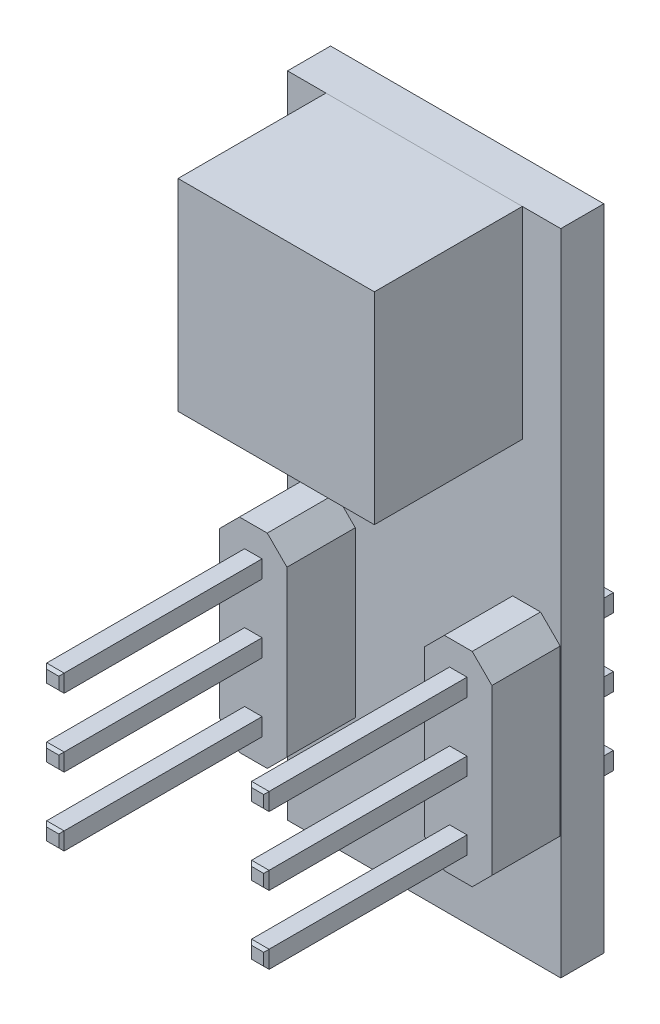
SolidWorks part; units mm, degrees
material "ABS"
ref_plane "Front Plane" through (0, 0, 0) normal (0, 0, 1) x (1, 0, 0)
ref_plane "Top Plane" through (0, 0, 0) normal (0, 1, 0) x (1, 0, 0)
ref_plane "Right Plane" through (0, 0, 0) normal (1, 0, 0) x (0, 0, -1)
sketch "Model" plane through (0, 0, 0) normal (0, 0, 1) x (1, 0, 0)
  line L0 (0, 24.13) -> (0, 0)
  line L1 (0, 0) -> (10.16, 0)
  line L2 (10.16, 0) -> (10.16, 24.13)
  line L3 (10.16, 24.13) -> (0, 24.13)
  line L4 (5.08, 11.43) -> (5.08, 3.81)
  line L5 (5.08, 11.43) -> (6.985, 11.43)
  line L6 (6.985, 11.43) -> (7.62, 10.795)
  line L7 (5.08, 11.43) -> (3.1496, 11.43)
  line L8 (3.1496, 11.43) -> (2.5146, 10.795)
  line L9 (5.08, 3.81) -> (7.0104, 3.81)
  line L10 (7.0104, 3.81) -> (7.62, 4.4196)
  line L11 (5.08, 3.81) -> (3.1242, 3.81)
  line L12 (3.1242, 3.81) -> (2.5146, 4.4196)
  line L13 (4.7371, 10.5035) -> (4.7371, 10.0459)
  line L14 (4.7371, 10.0459) -> (4.5083, 9.8171)
  line L15 (4.5083, 9.8171) -> (4.2795, 10.0459)
  line L16 (4.2795, 10.0459) -> (4.2795, 10.5035)
  line L17 (3.5311, 10.3891) -> (3.6455, 10.5035)
  line L18 (3.6455, 10.5035) -> (3.8743, 10.5035)
  line L19 (3.8743, 10.5035) -> (3.9887, 10.3891)
  line L20 (3.9887, 10.3891) -> (3.9887, 9.9315)
  line L21 (3.9887, 9.9315) -> (3.8743, 9.8171)
  line L22 (3.8743, 9.8171) -> (3.6455, 9.8171)
  line L23 (3.6455, 9.8171) -> (3.5311, 9.9315)
  line L24 (2.7827, 10.3891) -> (2.8971, 10.5035)
  line L25 (2.8971, 10.5035) -> (3.1259, 10.5035)
  line L26 (3.1259, 10.5035) -> (3.2403, 10.3891)
  line L27 (3.2403, 10.3891) -> (3.2403, 9.9315)
  line L28 (3.2403, 9.9315) -> (3.1259, 9.8171)
  line L29 (3.1259, 9.8171) -> (2.8971, 9.8171)
  line L30 (2.8971, 9.8171) -> (2.7827, 9.9315)
  line L31 (4.2795, 7.8491) -> (4.3939, 7.9635)
  line L32 (4.3939, 7.9635) -> (4.6227, 7.9635)
  line L33 (4.6227, 7.9635) -> (4.7371, 7.8491)
  line L34 (4.7371, 7.8491) -> (4.7371, 7.3915)
  line L35 (4.7371, 7.3915) -> (4.6227, 7.2771)
  line L36 (4.6227, 7.2771) -> (4.3939, 7.2771)
  line L37 (4.3939, 7.2771) -> (4.2795, 7.3915)
  line L38 (4.2795, 7.3915) -> (4.2795, 7.6203)
  line L39 (4.2795, 7.6203) -> (4.5083, 7.6203)
  line L40 (3.9887, 7.2771) -> (3.9887, 7.9635)
  line L41 (3.9887, 7.9635) -> (3.5311, 7.2771)
  line L42 (3.5311, 7.2771) -> (3.5311, 7.9635)
  line L43 (3.2403, 7.9635) -> (3.2403, 7.2771)
  line L44 (3.2403, 7.2771) -> (2.8971, 7.2771)
  line L45 (2.8971, 7.2771) -> (2.7827, 7.3915)
  line L46 (2.7827, 7.3915) -> (2.7827, 7.8491)
  line L47 (2.7827, 7.8491) -> (2.8971, 7.9635)
  line L48 (2.8971, 7.9635) -> (3.2403, 7.9635)
  line L49 (6.9211, 10.3891) -> (7.0355, 10.5035)
  line L50 (7.0355, 10.5035) -> (7.2643, 10.5035)
  line L51 (7.2643, 10.5035) -> (7.3787, 10.3891)
  line L52 (7.3787, 10.3891) -> (7.3787, 10.2747)
  line L53 (7.3787, 10.2747) -> (7.2643, 10.1603)
  line L54 (7.2643, 10.1603) -> (7.0355, 10.1603)
  line L55 (7.0355, 10.1603) -> (6.9211, 10.0459)
  line L56 (6.9211, 10.0459) -> (6.9211, 9.9315)
  line L57 (6.9211, 9.9315) -> (7.0355, 9.8171)
  line L58 (7.0355, 9.8171) -> (7.2643, 9.8171)
  line L59 (7.2643, 9.8171) -> (7.3787, 9.9315)
  line L60 (6.6303, 10.5035) -> (6.6303, 9.8171)
  line L61 (6.6303, 9.8171) -> (6.2871, 9.8171)
  line L62 (6.2871, 9.8171) -> (6.1727, 9.9315)
  line L63 (6.1727, 9.9315) -> (6.1727, 10.3891)
  line L64 (6.1727, 10.3891) -> (6.2871, 10.5035)
  line L65 (6.2871, 10.5035) -> (6.6303, 10.5035)
  line L66 (5.8819, 9.8171) -> (5.8819, 10.2747)
  line L67 (5.8819, 10.2747) -> (5.6531, 10.5035)
  line L68 (5.6531, 10.5035) -> (5.4243, 10.2747)
  line L69 (5.4243, 10.2747) -> (5.4243, 9.8171)
  line L70 (5.8819, 10.1603) -> (5.4243, 10.1603)
  line L71 (6.9211, 7.8491) -> (7.0355, 7.9635)
  line L72 (7.0355, 7.9635) -> (7.2643, 7.9635)
  line L73 (7.2643, 7.9635) -> (7.3787, 7.8491)
  line L74 (7.3787, 7.8491) -> (7.3787, 7.7347)
  line L75 (7.3787, 7.7347) -> (7.2643, 7.6203)
  line L76 (7.2643, 7.6203) -> (7.0355, 7.6203)
  line L77 (7.0355, 7.6203) -> (6.9211, 7.5059)
  line L78 (6.9211, 7.5059) -> (6.9211, 7.3915)
  line L79 (6.9211, 7.3915) -> (7.0355, 7.2771)
  line L80 (7.0355, 7.2771) -> (7.2643, 7.2771)
  line L81 (7.2643, 7.2771) -> (7.3787, 7.3915)
  line L82 (6.1727, 7.8491) -> (6.2871, 7.9635)
  line L83 (6.2871, 7.9635) -> (6.5159, 7.9635)
  line L84 (6.5159, 7.9635) -> (6.6303, 7.8491)
  line L85 (6.6303, 7.8491) -> (6.6303, 7.3915)
  line L86 (6.6303, 7.3915) -> (6.5159, 7.2771)
  line L87 (6.5159, 7.2771) -> (6.2871, 7.2771)
  line L88 (6.2871, 7.2771) -> (6.1727, 7.3915)
  line L89 (5.8819, 7.9635) -> (5.8819, 7.2771)
  line L90 (5.8819, 7.2771) -> (5.4243, 7.2771)
  line L91 (4.7371, 4.7371) -> (4.7371, 5.1947)
  line L92 (4.7371, 5.1947) -> (4.5083, 5.4235)
  line L93 (4.5083, 5.4235) -> (4.2795, 5.1947)
  line L94 (4.2795, 5.1947) -> (4.2795, 4.7371)
  line L95 (4.7371, 5.0803) -> (4.2795, 5.0803)
  line L96 (3.9887, 5.4235) -> (3.9887, 4.7371)
  line L97 (3.9887, 4.7371) -> (3.5311, 4.7371)
  line L98 (3.0115, 4.7371) -> (3.0115, 5.4235)
  line L99 (3.2403, 5.4235) -> (2.7827, 5.4235)
  line L100 (7.3787, 4.8515) -> (7.3787, 5.3091)
  line L101 (7.3787, 5.3091) -> (7.2643, 5.4235)
  line L102 (7.2643, 5.4235) -> (7.0355, 5.4235)
  line L103 (7.0355, 5.4235) -> (6.9211, 5.3091)
  line L104 (6.9211, 5.3091) -> (6.9211, 4.8515)
  line L105 (6.9211, 4.8515) -> (7.0355, 4.7371)
  line L106 (7.0355, 4.7371) -> (7.2643, 4.7371)
  line L107 (7.2643, 4.7371) -> (7.3787, 4.8515)
  line L108 (7.1499, 4.9659) -> (6.9211, 4.7371)
  line L109 (6.1727, 5.3091) -> (6.2871, 5.4235)
  line L110 (6.2871, 5.4235) -> (6.5159, 5.4235)
  line L111 (6.5159, 5.4235) -> (6.6303, 5.3091)
  line L112 (6.6303, 5.3091) -> (6.6303, 5.1947)
  line L113 (6.6303, 5.1947) -> (6.5159, 5.0803)
  line L114 (6.5159, 5.0803) -> (6.2871, 5.0803)
  line L115 (6.2871, 5.0803) -> (6.1727, 4.9659)
  line L116 (6.1727, 4.9659) -> (6.1727, 4.8515)
  line L117 (6.1727, 4.8515) -> (6.2871, 4.7371)
  line L118 (6.2871, 4.7371) -> (6.5159, 4.7371)
  line L119 (6.5159, 4.7371) -> (6.6303, 4.8515)
  line L120 (5.6531, 4.7371) -> (5.6531, 5.4235)
  line L121 (5.8819, 5.4235) -> (5.4243, 5.4235)
  line L122 (6.8961, 22.2123) -> (6.8961, 23.2546)
  line L123 (6.8961, 23.2546) -> (6.2012, 23.2546)
  line L124 (6.8961, 22.7334) -> (6.5487, 22.7334)
  line L125 (5.7267, 22.9072) -> (5.7267, 22.386)
  line L126 (5.7267, 22.386) -> (5.553, 22.2123)
  line L127 (5.553, 22.2123) -> (5.0318, 22.2123)
  line L128 (5.0318, 22.2123) -> (5.0318, 22.9072)
  line L129 (4.0362, 22.2123) -> (4.3836, 22.2123)
  line L130 (4.3836, 22.2123) -> (4.5573, 22.386)
  line L131 (4.5573, 22.386) -> (4.5573, 22.7334)
  line L132 (4.5573, 22.7334) -> (4.3836, 22.9072)
  line L133 (4.3836, 22.9072) -> (4.0362, 22.9072)
  line L134 (4.0362, 22.9072) -> (3.8624, 22.7334)
  line L135 (3.8624, 22.7334) -> (3.8624, 22.5597)
  line L136 (3.8624, 22.5597) -> (4.5573, 22.5597)
  line L137 (3.3879, 23.2546) -> (3.2142, 23.2546)
  line L138 (3.2142, 23.2546) -> (3.2142, 22.2123)
  line L139 (3.3879, 22.2123) -> (3.0405, 22.2123)
  line L140 (7.0902, 21.5315) -> (7.264, 21.7052)
  line L141 (7.264, 21.7052) -> (7.6114, 21.7052)
  line L142 (7.6114, 21.7052) -> (7.7851, 21.5315)
  line L143 (7.7851, 21.5315) -> (7.7851, 20.8366)
  line L144 (7.7851, 20.8366) -> (7.6114, 20.6629)
  line L145 (7.6114, 20.6629) -> (7.264, 20.6629)
  line L146 (7.264, 20.6629) -> (7.0902, 20.8366)
  line L147 (7.0902, 20.8366) -> (7.0902, 21.184)
  line L148 (7.0902, 21.184) -> (7.4377, 21.184)
  line L149 (6.442, 21.3578) -> (6.0946, 21.3578)
  line L150 (6.0946, 21.3578) -> (5.9208, 21.184)
  line L151 (5.9208, 21.184) -> (5.9208, 20.6629)
  line L152 (5.9208, 20.6629) -> (6.442, 20.6629)
  line L153 (6.442, 20.6629) -> (6.6157, 20.8366)
  line L154 (6.6157, 20.8366) -> (6.442, 21.0103)
  line L155 (6.442, 21.0103) -> (5.9208, 21.0103)
  line L156 (5.4463, 21.3578) -> (5.4463, 20.8366)
  line L157 (5.4463, 20.8366) -> (5.2726, 20.6629)
  line L158 (5.2726, 20.6629) -> (4.7514, 20.6629)
  line L159 (4.7514, 20.6629) -> (4.7514, 21.3578)
  line L160 (3.9295, 20.3155) -> (3.7558, 20.3155)
  line L161 (3.7558, 20.3155) -> (3.5821, 20.4892)
  line L162 (3.5821, 20.4892) -> (3.5821, 21.3578)
  line L163 (3.5821, 21.3578) -> (4.1032, 21.3578)
  line L164 (4.1032, 21.3578) -> (4.2769, 21.184)
  line L165 (4.2769, 21.184) -> (4.2769, 20.8366)
  line L166 (4.2769, 20.8366) -> (4.1032, 20.6629)
  line L167 (4.1032, 20.6629) -> (3.5821, 20.6629)
  line L168 (2.5864, 20.6629) -> (2.9338, 20.6629)
  line L169 (2.9338, 20.6629) -> (3.1075, 20.8366)
  line L170 (3.1075, 20.8366) -> (3.1075, 21.184)
  line L171 (3.1075, 21.184) -> (2.9338, 21.3578)
  line L172 (2.9338, 21.3578) -> (2.5864, 21.3578)
  line L173 (2.5864, 21.3578) -> (2.4127, 21.184)
  line L174 (2.4127, 21.184) -> (2.4127, 21.0103)
  line L175 (2.4127, 21.0103) -> (3.1075, 21.0103)
  line L176 (9.1313, 12.7006) -> (8.1314, 12.7006)
  line L177 (8.6313, 13.2006) -> (8.6313, 12.2007)
  line L178 (2.0193, 12.7006) -> (1.0194, 12.7006)
  line L179 (0.7611, 22.6901) -> (0.7611, 23.368)
  line L180 (0.7611, 23.368) -> (1.2696, 23.368)
  line L181 (1.2696, 23.368) -> (1.1001, 23.029)
  line L182 (1.1001, 23.029) -> (1.1001, 22.8596)
  line L183 (1.1001, 22.8596) -> (1.2696, 22.6901)
  line L184 (1.2696, 22.6901) -> (1.6085, 22.6901)
  line L185 (1.6085, 22.6901) -> (1.778, 22.8596)
  line L186 (1.778, 22.8596) -> (1.778, 23.1985)
  line L187 (1.778, 23.1985) -> (1.6085, 23.368)
  line L188 (1.2696, 22.1986) -> (1.2696, 21.5207)
  line L189 (0.9306, 21.0292) -> (0.7611, 20.8597)
  line L190 (0.7611, 20.8597) -> (0.7611, 20.5208)
  line L191 (0.7611, 20.5208) -> (0.9306, 20.3513)
  line L192 (0.9306, 20.3513) -> (1.1001, 20.3513)
  line L193 (1.1001, 20.3513) -> (1.2696, 20.5208)
  line L194 (1.2696, 20.5208) -> (1.2696, 20.6903)
  line L195 (1.2696, 20.5208) -> (1.439, 20.3513)
  line L196 (1.439, 20.3513) -> (1.6085, 20.3513)
  line L197 (1.6085, 20.3513) -> (1.778, 20.5208)
  line L198 (1.778, 20.5208) -> (1.778, 20.8597)
  line L199 (1.778, 20.8597) -> (1.6085, 21.0292)
  line L200 (1.2696, 19.8598) -> (1.2696, 19.1819)
  line L201 (1.1001, 18.6904) -> (0.7611, 18.3515)
  line L202 (0.7611, 18.3515) -> (1.778, 18.3515)
  line L203 (1.778, 18.6904) -> (1.778, 18.0125)
  line L204 (1.1001, 17.521) -> (0.7611, 17.1821)
  line L205 (0.7611, 17.1821) -> (1.778, 17.1821)
  line L206 (1.778, 17.521) -> (1.778, 16.8431)
  line L207 (8.666, 12.455) -> (8.666, 12.945)
  line L208 (9.114, 12.945) -> (9.114, 12.455)
  line L209 (8.407, 11.227) -> (8.407, 14.173)
  line L210 (8.407, 14.173) -> (9.373, 14.173)
  line L211 (9.373, 14.173) -> (9.373, 11.227)
  line L212 (9.373, 11.227) -> (8.407, 11.227)
  line L213 (8.8595, 12.7) -> (8.9205, 12.7)
  line L214 (7.861, 12.0779) -> (7.7975, 12.0144)
  line L215 (7.7975, 12.0144) -> (7.7975, 11.8873)
  line L216 (7.7975, 11.8873) -> (7.861, 11.8237)
  line L217 (7.861, 11.8237) -> (8.1152, 11.8237)
  line L218 (8.1152, 11.8237) -> (8.1788, 11.8873)
  line L219 (8.1788, 11.8873) -> (8.1788, 12.0144)
  line L220 (8.1788, 12.0144) -> (8.1152, 12.0779)
  line L221 (7.9246, 12.1979) -> (7.7975, 12.325)
  line L222 (7.7975, 12.325) -> (8.1788, 12.325)
  line L223 (8.1788, 12.1979) -> (8.1788, 12.4521)
  line L224 (9.7661, 11.6332) -> (9.639, 11.7603)
  line L225 (9.639, 11.7603) -> (10.0203, 11.7603)
  line L226 (10.0203, 11.6332) -> (10.0203, 11.8874)
  line L227 (9.7661, 12.0074) -> (9.9567, 12.0074)
  line L228 (9.9567, 12.0074) -> (10.0203, 12.071)
  line L229 (10.0203, 12.071) -> (10.0203, 12.2616)
  line L230 (10.0203, 12.2616) -> (9.7661, 12.2616)
  line L231 (10.0203, 12.3816) -> (9.639, 12.3816)
  line L232 (9.639, 12.3816) -> (9.639, 12.6358)
  line L233 (9.8296, 12.3816) -> (9.8296, 12.5087)
  line L234 (1.046, 12.455) -> (1.046, 12.945)
  line L235 (1.494, 12.945) -> (1.494, 12.455)
  line L236 (0.787, 11.227) -> (0.787, 14.173)
  line L237 (0.787, 14.173) -> (1.753, 14.173)
  line L238 (1.753, 14.173) -> (1.753, 11.227)
  line L239 (1.753, 11.227) -> (0.787, 11.227)
  line L240 (1.2395, 12.7) -> (1.3005, 12.7)
  line L241 (0.241, 12.0779) -> (0.1775, 12.0144)
  line L242 (0.1775, 12.0144) -> (0.1775, 11.8873)
  line L243 (0.1775, 11.8873) -> (0.241, 11.8237)
  line L244 (0.241, 11.8237) -> (0.4952, 11.8237)
  line L245 (0.4952, 11.8237) -> (0.5588, 11.8873)
  line L246 (0.5588, 11.8873) -> (0.5588, 12.0144)
  line L247 (0.5588, 12.0144) -> (0.4952, 12.0779)
  line L248 (0.5588, 12.4521) -> (0.5588, 12.1979)
  line L249 (0.5588, 12.1979) -> (0.3046, 12.4521)
  line L250 (0.3046, 12.4521) -> (0.241, 12.4521)
  line L251 (0.241, 12.4521) -> (0.1775, 12.3886)
  line L252 (0.1775, 12.3886) -> (0.1775, 12.2615)
  line L253 (0.1775, 12.2615) -> (0.241, 12.1979)
  line L254 (2.1461, 11.6332) -> (2.019, 11.7603)
  line L255 (2.019, 11.7603) -> (2.4003, 11.7603)
  line L256 (2.4003, 11.6332) -> (2.4003, 11.8874)
  line L257 (2.3367, 12.0074) -> (2.0825, 12.0074)
  line L258 (2.0825, 12.0074) -> (2.019, 12.071)
  line L259 (2.019, 12.071) -> (2.019, 12.1981)
  line L260 (2.019, 12.1981) -> (2.0825, 12.2616)
  line L261 (2.0825, 12.2616) -> (2.3367, 12.2616)
  line L262 (2.3367, 12.2616) -> (2.4003, 12.1981)
  line L263 (2.4003, 12.1981) -> (2.4003, 12.071)
  line L264 (2.4003, 12.071) -> (2.3367, 12.0074)
  line L265 (2.3367, 12.0074) -> (2.0825, 12.2616)
  line L266 (2.4003, 12.3816) -> (2.1461, 12.3816)
  line L267 (2.1461, 12.3816) -> (2.1461, 12.5723)
  line L268 (2.1461, 12.5723) -> (2.2096, 12.6358)
  line L269 (2.2096, 12.6358) -> (2.4003, 12.6358)
  line L270 (2.4003, 12.7558) -> (2.019, 12.7558)
  line L271 (2.019, 12.7558) -> (2.019, 13.01)
  line L272 (2.2096, 12.7558) -> (2.2096, 12.8829)
  line L273 (1.08, 19.32) -> (1.08, 15.82)
  line L274 (1.08, 15.82) -> (1.88, 15.82)
  line L275 (1.88, 15.82) -> (1.88, 18.32)
  line L276 (1.88, 18.32) -> (3.08, 18.32)
  line L277 (7.08, 18.32) -> (8.28, 18.32)
  line L278 (8.28, 18.32) -> (8.28, 15.82)
  line L279 (8.28, 15.82) -> (9.08, 15.82)
  line L280 (9.08, 15.82) -> (9.08, 19.32)
  line L281 (7.08, 23.32) -> (3.08, 23.32)
  line L282 (7.2898, 16.5105) -> (8.0694, 16.5105)
  line L283 (7.6796, 16.9003) -> (7.6796, 16.1207)
  line L284 (2.2098, 16.5105) -> (2.9894, 16.5105)
  line L285 (3.8227, 21.6663) -> (3.8863, 21.6027)
  line L286 (3.8863, 21.6027) -> (3.9498, 21.6027)
  line L287 (3.9498, 21.6027) -> (4.0134, 21.6663)
  line L288 (4.0134, 21.6663) -> (4.0134, 21.984)
  line L289 (3.9498, 21.984) -> (4.0769, 21.984)
  line L290 (4.1969, 21.6027) -> (4.1969, 21.984)
  line L291 (4.1969, 21.984) -> (4.3876, 21.984)
  line L292 (4.3876, 21.984) -> (4.4511, 21.9205)
  line L293 (4.4511, 21.9205) -> (4.4511, 21.7934)
  line L294 (4.4511, 21.7934) -> (4.3876, 21.7298)
  line L295 (4.3876, 21.7298) -> (4.1969, 21.7298)
  line L296 (4.5711, 21.8569) -> (4.6982, 21.984)
  line L297 (4.6982, 21.984) -> (4.6982, 21.6027)
  line L298 (4.5711, 21.6027) -> (4.8253, 21.6027)
  line L299 (3.8227, 20.5869) -> (3.8863, 20.5869)
  line L300 (3.8863, 20.5869) -> (3.8863, 20.3327)
  line L301 (3.8227, 20.3327) -> (3.9498, 20.3327)
  line L302 (3.8863, 20.7776) -> (3.8863, 20.714)
  line L303 (4.0722, 20.3327) -> (4.0722, 20.5869)
  line L304 (4.0722, 20.5869) -> (4.2628, 20.5869)
  line L305 (4.2628, 20.5869) -> (4.3264, 20.5234)
  line L306 (4.3264, 20.5234) -> (4.3264, 20.3327)
  line L307 (4.4464, 20.2056) -> (4.4464, 20.5869)
  line L308 (4.4464, 20.5869) -> (4.637, 20.5869)
  line L309 (4.637, 20.5869) -> (4.7006, 20.5234)
  line L310 (4.7006, 20.5234) -> (4.7006, 20.3963)
  line L311 (4.7006, 20.3963) -> (4.637, 20.3327)
  line L312 (4.637, 20.3327) -> (4.4464, 20.3327)
  line L313 (4.8206, 20.5869) -> (4.8206, 20.3963)
  line L314 (4.8206, 20.3963) -> (4.8841, 20.3327)
  line L315 (4.8841, 20.3327) -> (5.0748, 20.3327)
  line L316 (5.0748, 20.3327) -> (5.0748, 20.5869)
  line L317 (5.2583, 20.6505) -> (5.2583, 20.3963)
  line L318 (5.2583, 20.3963) -> (5.3219, 20.3327)
  line L319 (5.1948, 20.5869) -> (5.3219, 20.5869)
  line L320 (8.255, 6.35) -> (7.62, 5.715)
  line L321 (7.62, 5.715) -> (7.62, 4.445)
  line L322 (7.62, 4.445) -> (8.255, 3.81)
  line L323 (9.525, 3.81) -> (10.16, 4.445)
  line L324 (10.16, 4.445) -> (10.16, 5.715)
  line L325 (10.16, 5.715) -> (9.525, 6.35)
  line L326 (7.62, 10.795) -> (7.62, 9.525)
  line L327 (7.62, 9.525) -> (8.255, 8.89)
  line L328 (9.525, 8.89) -> (10.16, 9.525)
  line L329 (8.255, 8.89) -> (7.62, 8.255)
  line L330 (7.62, 8.255) -> (7.62, 6.985)
  line L331 (7.62, 6.985) -> (8.255, 6.35)
  line L332 (9.525, 6.35) -> (10.16, 6.985)
  line L333 (10.16, 6.985) -> (10.16, 8.255)
  line L334 (10.16, 8.255) -> (9.525, 8.89)
  line L335 (8.255, 11.43) -> (9.525, 11.43)
  line L336 (7.62, 10.795) -> (8.255, 11.43)
  line L337 (9.525, 11.43) -> (10.16, 10.795)
  line L338 (10.16, 9.525) -> (10.16, 10.795)
  line L339 (8.255, 3.81) -> (9.525, 3.81)
  line L340 (6.0454, 8.0615) -> (5.8547, 8.2522)
  line L341 (5.8547, 8.2522) -> (5.8547, 8.4428)
  line L342 (5.8547, 8.4428) -> (6.0454, 8.6335)
  line L343 (6.0454, 8.6335) -> (6.9987, 8.6335)
  line L344 (6.9987, 8.4428) -> (6.9987, 8.8242)
  line L345 (5.8547, 9.2309) -> (6.9987, 9.2309)
  line L346 (6.9987, 9.2309) -> (6.9987, 9.8029)
  line L347 (6.9987, 9.8029) -> (6.808, 9.9936)
  line L348 (6.808, 9.9936) -> (6.4267, 9.9936)
  line L349 (6.4267, 9.9936) -> (6.236, 9.8029)
  line L350 (6.236, 9.8029) -> (6.236, 9.2309)
  line L351 (5.8547, 11.1629) -> (5.8547, 10.4003)
  line L352 (5.8547, 10.4003) -> (6.6174, 11.1629)
  line L353 (6.6174, 11.1629) -> (6.808, 11.1629)
  line L354 (6.808, 11.1629) -> (6.9987, 10.9723)
  line L355 (6.9987, 10.9723) -> (6.9987, 10.591)
  line L356 (6.9987, 10.591) -> (6.808, 10.4003)
  line L357 (5.4228, 19.2456) -> (5.4711, 19.2532)
  line L358 (5.4711, 19.2532) -> (5.5651, 19.2606)
  line L359 (5.5651, 19.2606) -> (5.6591, 19.2532)
  line L360 (5.6591, 19.2532) -> (5.729, 19.2348)
  line L361 (5.729, 19.2348) -> (5.7938, 19.2027)
  line L362 (5.7938, 19.2027) -> (5.8508, 19.1583)
  line L363 (5.8508, 19.1583) -> (5.8978, 19.1033)
  line L364 (5.8978, 19.1033) -> (5.9379, 19.0301)
  line L365 (5.9379, 19.0301) -> (5.9619, 18.9502)
  line L366 (5.9619, 18.9502) -> (5.9689, 18.8671)
  line L367 (5.9689, 18.8671) -> (5.9689, 17.3507)
  line L368 (5.9689, 17.3507) -> (5.4813, 17.8994)
  line L369 (5.4813, 17.8994) -> (5.3945, 17.9789)
  line L370 (5.3945, 17.9789) -> (5.2933, 18.0391)
  line L371 (5.2933, 18.0391) -> (5.2561, 18.0526)
  line L372 (5.2561, 18.0526) -> (5.2171, 18.0594)
  line L373 (5.2171, 18.0594) -> (4.9885, 18.0594)
  line L374 (4.9885, 18.0594) -> (4.8522, 18.0718)
  line L375 (4.8522, 18.0718) -> (4.7203, 18.1086)
  line L376 (4.7203, 18.1086) -> (4.5973, 18.1686)
  line L377 (4.5973, 18.1686) -> (4.4816, 18.2503)
  line L378 (4.4816, 18.2503) -> (4.3784, 18.3475)
  line L379 (4.3784, 18.3475) -> (4.29, 18.4582)
  line L380 (4.29, 18.4582) -> (4.1953, 18.6263)
  line L381 (4.1953, 18.6263) -> (4.1325, 18.8087)
  line L382 (4.1325, 18.8087) -> (4.1037, 18.9994)
  line L383 (4.1037, 18.9994) -> (4.1097, 19.1922)
  line L384 (4.1097, 19.1922) -> (4.1304, 19.2962)
  line L385 (4.1304, 19.2962) -> (4.1662, 19.396)
  line L386 (4.1662, 19.396) -> (4.2163, 19.4894)
  line L387 (4.2163, 19.4894) -> (4.3069, 19.6031)
  line L388 (4.3069, 19.6031) -> (4.4195, 19.6952)
  line L389 (4.4195, 19.6952) -> (4.4195, 19.6063)
  line L390 (4.4195, 19.6063) -> (4.4215, 19.5918)
  line L391 (4.4215, 19.5918) -> (4.4272, 19.5783)
  line L392 (4.4272, 19.5783) -> (4.4568, 19.5416)
  line L393 (4.4568, 19.5416) -> (4.4957, 19.5148)
  line L394 (4.4957, 19.5148) -> (4.5161, 19.5072)
  line L395 (4.5161, 19.5072) -> (4.5733, 19.5011)
  line L396 (4.5733, 19.5011) -> (4.6299, 19.5115)
  line L397 (4.6299, 19.5115) -> (4.6812, 19.5377)
  line L398 (4.6812, 19.5377) -> (4.7726, 19.6037)
  line L399 (4.7726, 19.6037) -> (4.815, 19.6401)
  line L400 (4.815, 19.6401) -> (4.8513, 19.6825)
  line L401 (4.8513, 19.6825) -> (4.8806, 19.73)
  line L402 (4.8806, 19.73) -> (4.9021, 19.7815)
  line L403 (4.9021, 19.7815) -> (4.9086, 19.8142)
  line L404 (4.9086, 19.8142) -> (4.9072, 19.8476)
  line L405 (4.9072, 19.8476) -> (4.8906, 19.9026)
  line L406 (4.8906, 19.9026) -> (4.8603, 19.9515)
  line L407 (4.8603, 19.9515) -> (4.8183, 19.9907)
  line L408 (4.8183, 19.9907) -> (4.7675, 20.0177)
  line L409 (4.7675, 20.0177) -> (4.7163, 20.0322)
  line L410 (4.7163, 20.0322) -> (4.6634, 20.0381)
  line L411 (4.6634, 20.0381) -> (4.6025, 20.0381)
  line L412 (4.6025, 20.0381) -> (4.605, 20.0406)
  line L413 (4.605, 20.0406) -> (4.6485, 20.0744)
  line L414 (4.6485, 20.0744) -> (4.6989, 20.0965)
  line L415 (4.6989, 20.0965) -> (4.7345, 20.1117)
  line L416 (4.7345, 20.1117) -> (4.7574, 20.1219)
  line L417 (4.7574, 20.1219) -> (4.8452, 20.1439)
  line L418 (4.8452, 20.1439) -> (4.9352, 20.1524)
  line L419 (4.9352, 20.1524) -> (5.0221, 20.1458)
  line L420 (5.0221, 20.1458) -> (5.1061, 20.1226)
  line L421 (5.1061, 20.1226) -> (5.1841, 20.0838)
  line L422 (5.1841, 20.0838) -> (5.2618, 20.0278)
  line L423 (5.2618, 20.0278) -> (5.3314, 19.9619)
  line L424 (5.3314, 19.9619) -> (5.3745, 19.9015)
  line L425 (5.3745, 19.9015) -> (5.4013, 19.8323)
  line L426 (5.4013, 19.8323) -> (5.4099, 19.7586)
  line L427 (5.4099, 19.7586) -> (5.4, 19.6851)
  line L428 (5.4, 19.6851) -> (5.372, 19.6164)
  line L429 (5.372, 19.6164) -> (5.2534, 19.4406)
  line L430 (5.2534, 19.4406) -> (5.1079, 19.2862)
  line L431 (5.1079, 19.2862) -> (5.0696, 19.2413)
  line L432 (5.0696, 19.2413) -> (5.0441, 19.188)
  line L433 (5.0441, 19.188) -> (5.0334, 19.1299)
  line L434 (5.0334, 19.1299) -> (5.038, 19.071)
  line L435 (5.038, 19.071) -> (5.0576, 19.0153)
  line L436 (5.0576, 19.0153) -> (5.091, 18.9666)
  line L437 (5.091, 18.9666) -> (5.1358, 18.9281)
  line L438 (5.1358, 18.9281) -> (5.1922, 18.8977)
  line L439 (5.1922, 18.8977) -> (5.2529, 18.8772)
  line L440 (5.2529, 18.8772) -> (5.3162, 18.8671)
  line L441 (5.3162, 18.8671) -> (5.3902, 18.8708)
  line L442 (5.3902, 18.8708) -> (5.461, 18.8924)
  line L443 (5.461, 18.8924) -> (5.5244, 18.9306)
  line L444 (5.5244, 18.9306) -> (5.5581, 18.9659)
  line L445 (5.5581, 18.9659) -> (5.5803, 19.0094)
  line L446 (5.5803, 19.0094) -> (5.5902, 19.0539)
  line L447 (5.5902, 19.0539) -> (5.5902, 19.0995)
  line L448 (5.5902, 19.0995) -> (5.5803, 19.144)
  line L449 (5.5803, 19.144) -> (5.5713, 19.1611)
  line L450 (5.5713, 19.1611) -> (5.5575, 19.1745)
  line L451 (5.5575, 19.1745) -> (5.4736, 19.2354)
  line L452 (5.4736, 19.2354) -> (5.4579, 19.2438)
  line L453 (5.4579, 19.2438) -> (5.4405, 19.2473)
  line L454 (5.4405, 19.2473) -> (5.4228, 19.2456)
  line L455 (5.9689, 17.3736) -> (5.9486, 17.3736)
  line L456 (5.9689, 17.399) -> (5.926, 17.399)
  line L457 (5.9689, 17.4244) -> (5.9034, 17.4244)
  line L458 (5.9689, 17.4498) -> (5.8808, 17.4498)
  line L459 (5.9689, 17.4752) -> (5.8583, 17.4752)
  line L460 (5.9689, 17.5006) -> (5.8357, 17.5006)
  line L461 (5.9689, 17.526) -> (5.8131, 17.526)
  line L462 (5.9689, 17.5514) -> (5.7906, 17.5514)
  line L463 (5.9689, 17.5768) -> (5.768, 17.5768)
  line L464 (5.9689, 17.6022) -> (5.7454, 17.6022)
  line L465 (5.9689, 17.6276) -> (5.7228, 17.6276)
  line L466 (5.9689, 17.653) -> (5.7003, 17.653)
  line L467 (5.9689, 17.6784) -> (5.6777, 17.6784)
  line L468 (5.9689, 17.7038) -> (5.6551, 17.7038)
  line L469 (5.9689, 17.7292) -> (5.6326, 17.7292)
  line L470 (5.9689, 17.7546) -> (5.61, 17.7546)
  line L471 (5.9689, 17.78) -> (5.5874, 17.78)
  line L472 (5.9689, 17.8054) -> (5.5648, 17.8054)
  line L473 (5.9689, 17.8308) -> (5.5423, 17.8308)
  line L474 (5.9689, 17.8562) -> (5.5197, 17.8562)
  line L475 (5.9689, 17.8816) -> (5.4971, 17.8816)
  line L476 (5.9689, 17.907) -> (5.473, 17.907)
  line L477 (5.9689, 17.9324) -> (5.4453, 17.9324)
  line L478 (5.9689, 17.9578) -> (5.4176, 17.9578)
  line L479 (5.9689, 17.9832) -> (5.3873, 17.9832)
  line L480 (5.9689, 18.0086) -> (5.3446, 18.0086)
  line L481 (5.9689, 18.034) -> (5.3019, 18.034)
  line L482 (5.9689, 18.0594) -> (4.9885, 18.0594)
  line L483 (5.9689, 18.0848) -> (4.8056, 18.0848)
  line L484 (5.9689, 18.1102) -> (4.7171, 18.1102)
  line L485 (5.9689, 18.1356) -> (4.665, 18.1356)
  line L486 (5.9689, 18.161) -> (4.6129, 18.161)
  line L487 (5.9689, 18.1864) -> (4.5721, 18.1864)
  line L488 (5.9689, 18.2118) -> (4.5361, 18.2118)
  line L489 (5.9689, 18.2372) -> (4.5002, 18.2372)
  line L490 (5.9689, 18.2626) -> (4.4685, 18.2626)
  line L491 (5.9689, 18.288) -> (4.4416, 18.288)
  line L492 (5.9689, 18.3134) -> (4.4146, 18.3134)
  line L493 (5.9689, 18.3388) -> (4.3877, 18.3388)
  line L494 (5.9689, 18.3642) -> (4.3651, 18.3642)
  line L495 (5.9689, 18.3896) -> (4.3448, 18.3896)
  line L496 (5.9689, 18.415) -> (4.3245, 18.415)
  line L497 (5.9689, 18.4404) -> (4.3042, 18.4404)
  line L498 (5.9689, 18.4658) -> (4.2857, 18.4658)
  line L499 (5.9689, 18.4912) -> (4.2714, 18.4912)
  line L500 (5.9689, 18.5166) -> (4.2571, 18.5166)
  line L501 (5.9689, 18.542) -> (4.2428, 18.542)
  line L502 (5.9689, 18.5674) -> (4.2285, 18.5674)
  line L503 (5.9689, 18.5928) -> (4.2142, 18.5928)
  line L504 (5.9689, 18.6182) -> (4.1999, 18.6182)
  line L505 (5.9689, 18.6436) -> (4.1894, 18.6436)
  line L506 (5.9689, 18.669) -> (4.1806, 18.669)
  line L507 (5.9689, 18.6944) -> (4.1719, 18.6944)
  line L508 (5.9689, 18.7198) -> (4.1631, 18.7198)
  line L509 (5.9689, 18.7452) -> (4.1544, 18.7452)
  line L510 (5.9689, 18.7706) -> (4.1456, 18.7706)
  line L511 (5.9689, 18.796) -> (4.1369, 18.796)
  line L512 (5.9689, 18.8214) -> (4.1306, 18.8214)
  line L513 (5.9689, 18.8468) -> (4.1268, 18.8468)
  line L514 (5.9685, 18.8722) -> (5.3948, 18.8722)
  line L515 (5.2842, 18.8722) -> (4.1229, 18.8722)
  line L516 (5.9663, 18.8976) -> (5.4696, 18.8976)
  line L517 (5.1922, 18.8977) -> (4.1191, 18.8976)
  line L518 (5.9642, 18.923) -> (5.5118, 18.923)
  line L519 (5.1453, 18.923) -> (4.1152, 18.923)
  line L520 (5.9621, 18.9484) -> (5.5414, 18.9484)
  line L521 (5.1121, 18.9484) -> (4.1114, 18.9484)
  line L522 (5.9549, 18.9738) -> (5.5621, 18.9738)
  line L523 (5.086, 18.9738) -> (4.1075, 18.9738)
  line L524 (5.9472, 18.9992) -> (5.5751, 18.9992)
  line L525 (5.0686, 18.9992) -> (4.1037, 18.9994)
  line L526 (5.9396, 19.0246) -> (5.5837, 19.0246)
  line L527 (5.0543, 19.0246) -> (4.1045, 19.0246)
  line L528 (5.927, 19.05) -> (5.5894, 19.05)
  line L529 (5.0454, 19.05) -> (4.1052, 19.05)
  line L530 (5.9131, 19.0754) -> (5.5902, 19.0754)
  line L531 (5.0376, 19.0754) -> (4.106, 19.0754)
  line L532 (5.8992, 19.1008) -> (5.5899, 19.1008)
  line L533 (5.0356, 19.1008) -> (4.1068, 19.1008)
  line L534 (5.8782, 19.1262) -> (5.5843, 19.1262)
  line L535 (5.0337, 19.1262) -> (4.1076, 19.1262)
  line L536 (5.8566, 19.1516) -> (5.5763, 19.1516)
  line L537 (5.0374, 19.1516) -> (4.1084, 19.1516)
  line L538 (5.8268, 19.177) -> (5.5541, 19.177)
  line L539 (5.0421, 19.177) -> (4.1092, 19.177)
  line L540 (5.7938, 19.2027) -> (5.5191, 19.2024)
  line L541 (5.051, 19.2024) -> (4.1117, 19.2024)
  line L542 (5.7431, 19.2278) -> (5.4841, 19.2278)
  line L543 (5.0632, 19.2278) -> (4.1168, 19.2278)
  line L544 (5.6591, 19.2532) -> (5.4711, 19.2532)
  line L545 (5.0798, 19.2532) -> (4.1218, 19.2532)
  line L546 (5.1014, 19.2786) -> (4.1269, 19.2786)
  line L547 (5.1247, 19.304) -> (4.1332, 19.304)
  line L548 (5.1486, 19.3294) -> (4.1423, 19.3294)
  line L549 (5.1726, 19.3548) -> (4.1514, 19.3548)
  line L550 (5.1965, 19.3802) -> (4.1605, 19.3802)
  line L551 (5.2204, 19.4056) -> (4.1713, 19.4056)
  line L552 (5.2444, 19.431) -> (4.185, 19.431)
  line L553 (5.2641, 19.4564) -> (4.1986, 19.4564)
  line L554 (5.2812, 19.4818) -> (4.2122, 19.4818)
  line L555 (5.2983, 19.5072) -> (4.6066, 19.5072)
  line L556 (4.5161, 19.5072) -> (4.2305, 19.5072)
  line L557 (5.3155, 19.5326) -> (4.6712, 19.5326)
  line L558 (4.4699, 19.5326) -> (4.2507, 19.5326)
  line L559 (5.3326, 19.558) -> (4.7093, 19.558)
  line L560 (4.4436, 19.558) -> (4.271, 19.558)
  line L561 (5.3497, 19.5834) -> (4.7445, 19.5834)
  line L562 (4.425, 19.5834) -> (4.2912, 19.5834)
  line L563 (5.3669, 19.6088) -> (4.7785, 19.6088)
  line L564 (4.4195, 19.6088) -> (4.3139, 19.6088)
  line L565 (5.3792, 19.6342) -> (4.8081, 19.6342)
  line L566 (4.4195, 19.6342) -> (4.3449, 19.6342)
  line L567 (5.3896, 19.6596) -> (4.8317, 19.6596)
  line L568 (4.4195, 19.6596) -> (4.376, 19.6596)
  line L569 (5.4, 19.6851) -> (4.8528, 19.685)
  line L570 (4.4195, 19.685) -> (4.407, 19.685)
  line L571 (5.4034, 19.7104) -> (4.8685, 19.7104)
  line L572 (5.4068, 19.7358) -> (4.883, 19.7358)
  line L573 (5.4096, 19.7612) -> (4.8936, 19.7612)
  line L574 (5.4066, 19.7866) -> (4.9031, 19.7866)
  line L575 (5.4037, 19.812) -> (4.9082, 19.812)
  line L576 (5.3993, 19.8374) -> (4.9076, 19.8374)
  line L577 (5.3895, 19.8628) -> (4.9026, 19.8628)
  line L578 (5.3797, 19.8882) -> (4.895, 19.8882)
  line L579 (5.3659, 19.9136) -> (4.8838, 19.9136)
  line L580 (5.3478, 19.939) -> (4.868, 19.939)
  line L581 (5.3288, 19.9644) -> (4.8464, 19.9644)
  line L582 (5.3019, 19.9898) -> (4.8193, 19.9898)
  line L583 (5.2751, 20.0152) -> (4.7722, 20.0152)
  line L584 (5.244, 20.0406) -> (4.605, 20.0406)
  line L585 (5.2088, 20.066) -> (4.6376, 20.066)
  line L586 (5.1688, 20.0914) -> (4.6873, 20.0914)
  line L587 (5.1178, 20.1168) -> (4.746, 20.1168)
  line L588 (5.035, 20.1422) -> (4.8386, 20.1422)
  line L589 (0.635, 6.35) -> (0, 5.715)
  line L590 (0, 5.715) -> (0, 4.445)
  line L591 (0, 4.445) -> (0.635, 3.81)
  line L592 (1.905, 3.81) -> (2.54, 4.445)
  line L593 (2.54, 4.445) -> (2.54, 5.715)
  line L594 (2.54, 5.715) -> (1.905, 6.35)
  line L595 (0, 10.795) -> (0, 9.525)
  line L596 (0, 9.525) -> (0.635, 8.89)
  line L597 (1.905, 8.89) -> (2.54, 9.525)
  line L598 (0.635, 8.89) -> (0, 8.255)
  line L599 (0, 8.255) -> (0, 6.985)
  line L600 (0, 6.985) -> (0.635, 6.35)
  line L601 (1.905, 6.35) -> (2.54, 6.985)
  line L602 (2.54, 6.985) -> (2.54, 8.255)
  line L603 (2.54, 8.255) -> (1.905, 8.89)
  line L604 (0.635, 11.43) -> (1.905, 11.43)
  line L605 (0, 10.795) -> (0.635, 11.43)
  line L606 (1.905, 11.43) -> (2.54, 10.795)
  line L607 (2.54, 9.525) -> (2.54, 10.795)
  line L608 (0.635, 3.81) -> (1.905, 3.81)
  line L609 (6.985, 13.97) -> (5.715, 13.97)
  line L610 (5.715, 13.97) -> (5.08, 13.335)
  line L611 (5.08, 12.065) -> (5.715, 11.43)
  line L612 (5.08, 13.335) -> (4.445, 13.97)
  line L613 (4.445, 13.97) -> (3.175, 13.97)
  line L614 (3.175, 13.97) -> (2.54, 13.335)
  line L615 (2.54, 12.065) -> (3.175, 11.43)
  line L616 (3.175, 11.43) -> (4.445, 11.43)
  line L617 (4.445, 11.43) -> (5.08, 12.065)
  line L618 (7.62, 13.335) -> (7.62, 12.065)
  line L619 (6.985, 13.97) -> (7.62, 13.335)
  line L620 (7.62, 12.065) -> (6.985, 11.43)
  line L621 (5.715, 11.43) -> (6.985, 11.43)
  line L622 (2.54, 13.335) -> (2.54, 12.065)
  line L623 (7.6327, 14.783) -> (7.442, 14.5923)
  line L624 (7.442, 14.5923) -> (7.2514, 14.5923)
  line L625 (7.2514, 14.5923) -> (7.0607, 14.783)
  line L626 (7.0607, 14.783) -> (7.0607, 15.7363)
  line L627 (7.2514, 15.7363) -> (6.87, 15.7363)
  line L628 (6.4633, 14.5923) -> (6.4633, 15.7363)
  line L629 (6.4633, 15.7363) -> (5.8913, 15.7363)
  line L630 (5.8913, 15.7363) -> (5.7007, 15.5456)
  line L631 (5.7007, 15.5456) -> (5.7007, 15.1643)
  line L632 (5.7007, 15.1643) -> (5.8913, 14.9736)
  line L633 (5.8913, 14.9736) -> (6.4633, 14.9736)
  line L634 (4.5313, 15.7363) -> (5.2939, 15.7363)
  line L635 (5.2939, 15.7363) -> (5.2939, 15.1643)
  line L636 (5.2939, 15.1643) -> (4.9126, 15.355)
  line L637 (4.9126, 15.355) -> (4.7219, 15.355)
  line L638 (4.7219, 15.355) -> (4.5313, 15.1643)
  line L639 (4.5313, 15.1643) -> (4.5313, 14.783)
  line L640 (4.5313, 14.783) -> (4.7219, 14.5923)
  line L641 (4.7219, 14.5923) -> (5.1032, 14.5923)
  line L642 (5.1032, 14.5923) -> (5.2939, 14.783)
  line L643 (6.595, 9.936) -> (6.105, 9.936)
  line L644 (6.105, 10.384) -> (6.595, 10.384)
  line L645 (7.823, 9.677) -> (4.877, 9.677)
  line L646 (4.877, 9.677) -> (4.877, 10.643)
  line L647 (4.877, 10.643) -> (7.823, 10.643)
  line L648 (7.823, 10.643) -> (7.823, 9.677)
  line L649 (6.5033, 9.0678) -> (6.5033, 9.4491)
  line L650 (6.5033, 9.4491) -> (6.6939, 9.4491)
  line L651 (6.6939, 9.4491) -> (6.7575, 9.3856)
  line L652 (6.7575, 9.3856) -> (6.7575, 9.2585)
  line L653 (6.7575, 9.2585) -> (6.6939, 9.1949)
  line L654 (6.6939, 9.1949) -> (6.5033, 9.1949)
  line L655 (6.6304, 9.1949) -> (6.7575, 9.0678)
  line L656 (6.8775, 9.322) -> (7.0046, 9.4491)
  line L657 (7.0046, 9.4491) -> (7.0046, 9.0678)
  line L658 (6.8775, 9.0678) -> (7.1317, 9.0678)
  line L659 (6.7562, 11.1635) -> (6.8833, 11.2906)
  line L660 (6.8833, 11.2906) -> (6.8833, 10.9093)
  line L661 (6.7562, 10.9093) -> (7.0104, 10.9093)
  line L662 (7.1304, 10.9093) -> (7.1304, 11.2906)
  line L663 (7.321, 10.9093) -> (7.1304, 11.0364)
  line L664 (7.1304, 11.0364) -> (7.321, 11.1635)
  line L665 (4.055, 9.936) -> (3.565, 9.936)
  line L666 (3.565, 10.384) -> (4.055, 10.384)
  line L667 (5.283, 9.677) -> (2.337, 9.677)
  line L668 (2.337, 9.677) -> (2.337, 10.643)
  line L669 (2.337, 10.643) -> (5.283, 10.643)
  line L670 (5.283, 10.643) -> (5.283, 9.677)
  line L671 (3.9633, 9.0678) -> (3.9633, 9.4491)
  line L672 (3.9633, 9.4491) -> (4.1539, 9.4491)
  line L673 (4.1539, 9.4491) -> (4.2175, 9.3856)
  line L674 (4.2175, 9.3856) -> (4.2175, 9.2585)
  line L675 (4.2175, 9.2585) -> (4.1539, 9.1949)
  line L676 (4.1539, 9.1949) -> (3.9633, 9.1949)
  line L677 (4.0904, 9.1949) -> (4.2175, 9.0678)
  line L678 (4.5917, 9.0678) -> (4.3375, 9.0678)
  line L679 (4.3375, 9.0678) -> (4.5917, 9.322)
  line L680 (4.5917, 9.322) -> (4.5917, 9.3856)
  line L681 (4.5917, 9.3856) -> (4.5282, 9.4491)
  line L682 (4.5282, 9.4491) -> (4.401, 9.4491)
  line L683 (4.401, 9.4491) -> (4.3375, 9.3856)
  line L684 (3.7796, 11.1635) -> (3.9067, 11.2906)
  line L685 (3.9067, 11.2906) -> (3.9067, 10.9093)
  line L686 (3.7796, 10.9093) -> (4.0338, 10.9093)
  line L687 (4.1538, 11.2271) -> (4.2173, 11.2906)
  line L688 (4.2173, 11.2906) -> (4.3444, 11.2906)
  line L689 (4.3444, 11.2906) -> (4.408, 11.2271)
  line L690 (4.408, 11.2271) -> (4.408, 11.1635)
  line L691 (4.408, 11.1635) -> (4.3444, 11.1)
  line L692 (4.3444, 11.1) -> (4.408, 11.0364)
  line L693 (4.408, 11.0364) -> (4.408, 10.9729)
  line L694 (4.408, 10.9729) -> (4.3444, 10.9093)
  line L695 (4.3444, 10.9093) -> (4.2173, 10.9093)
  line L696 (4.2173, 10.9093) -> (4.1538, 10.9729)
  line L697 (4.1538, 10.9729) -> (4.1538, 11.0364)
  line L698 (4.1538, 11.0364) -> (4.2173, 11.1)
  line L699 (4.2173, 11.1) -> (4.1538, 11.1635)
  line L700 (4.1538, 11.1635) -> (4.1538, 11.2271)
  line L701 (4.2173, 11.1) -> (4.3444, 11.1)
  line L702 (4.528, 10.9729) -> (4.528, 11.2271)
  line L703 (4.528, 11.2271) -> (4.5915, 11.2906)
  line L704 (4.5915, 11.2906) -> (4.7187, 11.2906)
  line L705 (4.7187, 11.2906) -> (4.7822, 11.2271)
  line L706 (4.7822, 11.2271) -> (4.7822, 10.9729)
  line L707 (4.7822, 10.9729) -> (4.7187, 10.9093)
  line L708 (4.7187, 10.9093) -> (4.5915, 10.9093)
  line L709 (4.5915, 10.9093) -> (4.528, 10.9729)
  line L710 (4.528, 10.9729) -> (4.7822, 11.2271)
  line L711 (2.295, 1.494) -> (2.785, 1.494)
  line L712 (2.785, 1.046) -> (2.295, 1.046)
  line L713 (1.067, 1.753) -> (4.013, 1.753)
  line L714 (4.013, 1.753) -> (4.013, 0.787)
  line L715 (4.013, 0.787) -> (1.067, 0.787)
  line L716 (1.067, 0.787) -> (1.067, 1.753)
  line L717 (1.6637, 1.9812) -> (1.6637, 2.3625)
  line L718 (1.6637, 2.3625) -> (1.8544, 2.3625)
  line L719 (1.8544, 2.3625) -> (1.9179, 2.299)
  line L720 (1.9179, 2.299) -> (1.9179, 2.1719)
  line L721 (1.9179, 2.1719) -> (1.8544, 2.1083)
  line L722 (1.8544, 2.1083) -> (1.6637, 2.1083)
  line L723 (1.7908, 2.1083) -> (1.9179, 1.9812)
  line L724 (2.0379, 2.299) -> (2.1015, 2.3625)
  line L725 (2.1015, 2.3625) -> (2.2286, 2.3625)
  line L726 (2.2286, 2.3625) -> (2.2921, 2.299)
  line L727 (2.2921, 2.299) -> (2.2921, 2.2354)
  line L728 (2.2921, 2.2354) -> (2.2286, 2.1719)
  line L729 (2.2286, 2.1719) -> (2.165, 2.1719)
  line L730 (2.2286, 2.1719) -> (2.2921, 2.1083)
  line L731 (2.2921, 2.1083) -> (2.2921, 2.0448)
  line L732 (2.2921, 2.0448) -> (2.2286, 1.9812)
  line L733 (2.2286, 1.9812) -> (2.1015, 1.9812)
  line L734 (2.1015, 1.9812) -> (2.0379, 2.0448)
  line L735 (1.6639, 0.1397) -> (1.6639, 0.521)
  line L736 (1.6639, 0.521) -> (1.4732, 0.3304)
  line L737 (1.4732, 0.3304) -> (1.7274, 0.3304)
  line L738 (1.8474, 0.1397) -> (1.8474, 0.2033)
  line L739 (1.8474, 0.2033) -> (1.911, 0.2033)
  line L740 (1.911, 0.2033) -> (1.911, 0.1397)
  line L741 (1.911, 0.1397) -> (1.8474, 0.1397)
  line L742 (2.0345, 0.521) -> (2.2887, 0.521)
  line L743 (2.2887, 0.521) -> (2.2887, 0.4575)
  line L744 (2.2887, 0.4575) -> (2.0345, 0.2033)
  line L745 (2.0345, 0.2033) -> (2.0345, 0.1397)
  line L746 (2.4087, 0.1397) -> (2.4087, 0.521)
  line L747 (2.5994, 0.1397) -> (2.4087, 0.2668)
  line L748 (2.4087, 0.2668) -> (2.5994, 0.3939)
  line L749 (2.295, 2.764) -> (2.785, 2.764)
  line L750 (2.785, 2.316) -> (2.295, 2.316)
  line L751 (1.067, 3.023) -> (4.013, 3.023)
  line L752 (4.013, 3.023) -> (4.013, 2.057)
  line L753 (4.013, 2.057) -> (1.067, 2.057)
  line L754 (1.067, 2.057) -> (1.067, 3.023)
  line L755 (1.6637, 3.2512) -> (1.6637, 3.6325)
  line L756 (1.6637, 3.6325) -> (1.8544, 3.6325)
  line L757 (1.8544, 3.6325) -> (1.9179, 3.569)
  line L758 (1.9179, 3.569) -> (1.9179, 3.4419)
  line L759 (1.9179, 3.4419) -> (1.8544, 3.3783)
  line L760 (1.8544, 3.3783) -> (1.6637, 3.3783)
  line L761 (1.7908, 3.3783) -> (1.9179, 3.2512)
  line L762 (2.2286, 3.2512) -> (2.2286, 3.6325)
  line L763 (2.2286, 3.6325) -> (2.0379, 3.4419)
  line L764 (2.0379, 3.4419) -> (2.2921, 3.4419)
  line L765 (1.6639, 1.4097) -> (1.6639, 1.791)
  line L766 (1.6639, 1.791) -> (1.4732, 1.6004)
  line L767 (1.4732, 1.6004) -> (1.7274, 1.6004)
  line L768 (1.8474, 1.4097) -> (1.8474, 1.4733)
  line L769 (1.8474, 1.4733) -> (1.911, 1.4733)
  line L770 (1.911, 1.4733) -> (1.911, 1.4097)
  line L771 (1.911, 1.4097) -> (1.8474, 1.4097)
  line L772 (2.0345, 1.791) -> (2.2887, 1.791)
  line L773 (2.2887, 1.791) -> (2.2887, 1.7275)
  line L774 (2.2887, 1.7275) -> (2.0345, 1.4733)
  line L775 (2.0345, 1.4733) -> (2.0345, 1.4097)
  line L776 (2.4087, 1.4097) -> (2.4087, 1.791)
  line L777 (2.5994, 1.4097) -> (2.4087, 1.5368)
  line L778 (2.4087, 1.5368) -> (2.5994, 1.6639)
  line L779 (7.865, 1.046) -> (7.375, 1.046)
  line L780 (7.375, 1.494) -> (7.865, 1.494)
  line L781 (9.093, 0.787) -> (6.147, 0.787)
  line L782 (6.147, 0.787) -> (6.147, 1.753)
  line L783 (6.147, 1.753) -> (9.093, 1.753)
  line L784 (9.093, 1.753) -> (9.093, 0.787)
  line L785 (7.7733, 0.1778) -> (7.7733, 0.5591)
  line L786 (7.7733, 0.5591) -> (7.9639, 0.5591)
  line L787 (7.9639, 0.5591) -> (8.0275, 0.4956)
  line L788 (8.0275, 0.4956) -> (8.0275, 0.3685)
  line L789 (8.0275, 0.3685) -> (7.9639, 0.3049)
  line L790 (7.9639, 0.3049) -> (7.7733, 0.3049)
  line L791 (7.9004, 0.3049) -> (8.0275, 0.1778)
  line L792 (8.4017, 0.5591) -> (8.1475, 0.5591)
  line L793 (8.1475, 0.5591) -> (8.1475, 0.3685)
  line L794 (8.1475, 0.3685) -> (8.2746, 0.432)
  line L795 (8.2746, 0.432) -> (8.3382, 0.432)
  line L796 (8.3382, 0.432) -> (8.4017, 0.3685)
  line L797 (8.4017, 0.3685) -> (8.4017, 0.2414)
  line L798 (8.4017, 0.2414) -> (8.3382, 0.1778)
  line L799 (8.3382, 0.1778) -> (8.211, 0.1778)
  line L800 (8.211, 0.1778) -> (8.1475, 0.2414)
  line L801 (7.6555, 2.0193) -> (7.6555, 2.4006)
  line L802 (7.6555, 2.4006) -> (7.4648, 2.21)
  line L803 (7.4648, 2.21) -> (7.7191, 2.21)
  line L804 (7.839, 2.0193) -> (7.839, 2.0829)
  line L805 (7.839, 2.0829) -> (7.9026, 2.0829)
  line L806 (7.9026, 2.0829) -> (7.9026, 2.0193)
  line L807 (7.9026, 2.0193) -> (7.839, 2.0193)
  line L808 (8.0262, 2.4006) -> (8.2804, 2.4006)
  line L809 (8.2804, 2.4006) -> (8.2804, 2.3371)
  line L810 (8.2804, 2.3371) -> (8.0262, 2.0829)
  line L811 (8.0262, 2.0829) -> (8.0262, 2.0193)
  line L812 (8.4004, 2.0193) -> (8.4004, 2.4006)
  line L813 (8.591, 2.0193) -> (8.4004, 2.1464)
  line L814 (8.4004, 2.1464) -> (8.591, 2.2735)
  line L815 (7.865, 2.316) -> (7.375, 2.316)
  line L816 (7.375, 2.764) -> (7.865, 2.764)
  line L817 (9.093, 2.057) -> (6.147, 2.057)
  line L818 (6.147, 2.057) -> (6.147, 3.023)
  line L819 (6.147, 3.023) -> (9.093, 3.023)
  line L820 (9.093, 3.023) -> (9.093, 2.057)
  line L821 (7.7733, 1.4478) -> (7.7733, 1.8291)
  line L822 (7.7733, 1.8291) -> (7.9639, 1.8291)
  line L823 (7.9639, 1.8291) -> (8.0275, 1.7656)
  line L824 (8.0275, 1.7656) -> (8.0275, 1.6385)
  line L825 (8.0275, 1.6385) -> (7.9639, 1.5749)
  line L826 (7.9639, 1.5749) -> (7.7733, 1.5749)
  line L827 (7.9004, 1.5749) -> (8.0275, 1.4478)
  line L828 (8.4017, 1.8291) -> (8.2746, 1.7656)
  line L829 (8.2746, 1.7656) -> (8.1475, 1.6385)
  line L830 (8.1475, 1.6385) -> (8.1475, 1.5114)
  line L831 (8.1475, 1.5114) -> (8.211, 1.4478)
  line L832 (8.211, 1.4478) -> (8.3382, 1.4478)
  line L833 (8.3382, 1.4478) -> (8.4017, 1.5114)
  line L834 (8.4017, 1.5114) -> (8.4017, 1.5749)
  line L835 (8.4017, 1.5749) -> (8.3382, 1.6385)
  line L836 (8.3382, 1.6385) -> (8.1475, 1.6385)
  line L837 (7.6555, 3.2893) -> (7.6555, 3.6706)
  line L838 (7.6555, 3.6706) -> (7.4648, 3.48)
  line L839 (7.4648, 3.48) -> (7.7191, 3.48)
  line L840 (7.839, 3.2893) -> (7.839, 3.3529)
  line L841 (7.839, 3.3529) -> (7.9026, 3.3529)
  line L842 (7.9026, 3.3529) -> (7.9026, 3.2893)
  line L843 (7.9026, 3.2893) -> (7.839, 3.2893)
  line L844 (8.0262, 3.6706) -> (8.2804, 3.6706)
  line L845 (8.2804, 3.6706) -> (8.2804, 3.6071)
  line L846 (8.2804, 3.6071) -> (8.0262, 3.3529)
  line L847 (8.0262, 3.3529) -> (8.0262, 3.2893)
  line L848 (8.4004, 3.2893) -> (8.4004, 3.6706)
  line L849 (8.591, 3.2893) -> (8.4004, 3.4164)
  line L850 (8.4004, 3.4164) -> (8.591, 3.5435)
  line L851 (4.6853, 14.6682) -> (4.5335, 14.7464)
  line L852 (4.5335, 14.7464) -> (4.1565, 14.439)
  line L853 (4.1565, 14.439) -> (3.898, 14.6975)
  line L854 (3.898, 14.6975) -> (4.2054, 15.0745)
  line L855 (4.2054, 15.0745) -> (4.1272, 15.2263)
  line L856 (4.1272, 15.2263) -> (4.0751, 15.389)
  line L857 (4.0751, 15.389) -> (3.5912, 15.4382)
  line L858 (3.5912, 15.4382) -> (3.5912, 15.8038)
  line L859 (3.5912, 15.8038) -> (4.0751, 15.853)
  line L860 (4.0751, 15.853) -> (4.1272, 16.0157)
  line L861 (4.1272, 16.0157) -> (4.2054, 16.1675)
  line L862 (4.2054, 16.1675) -> (3.898, 16.5445)
  line L863 (3.898, 16.5445) -> (4.1565, 16.803)
  line L864 (4.1565, 16.803) -> (4.5335, 16.4956)
  line L865 (4.5335, 16.4956) -> (4.6853, 16.5738)
  line L866 (4.6853, 16.5738) -> (4.848, 16.6259)
  line L867 (4.848, 16.6259) -> (4.8972, 17.1098)
  line L868 (4.8972, 17.1098) -> (5.2628, 17.1098)
  line L869 (5.2628, 17.1098) -> (5.312, 16.6259)
  line L870 (5.312, 16.6259) -> (5.4747, 16.5738)
  line L871 (5.4747, 16.5738) -> (5.6265, 16.4956)
  line L872 (5.6265, 16.4956) -> (6.0035, 16.803)
  line L873 (6.0035, 16.803) -> (6.262, 16.5445)
  line L874 (6.262, 16.5445) -> (5.9546, 16.1675)
  line L875 (5.9546, 16.1675) -> (6.0328, 16.0157)
  line L876 (6.0328, 16.0157) -> (6.0849, 15.853)
  line L877 (6.0849, 15.853) -> (6.5688, 15.8038)
  line L878 (6.5688, 15.8038) -> (6.5688, 15.4382)
  line L879 (6.5688, 15.4382) -> (6.0849, 15.389)
  line L880 (6.0849, 15.389) -> (6.0328, 15.2263)
  line L881 (6.0328, 15.2263) -> (5.9546, 15.0745)
  line L882 (5.9546, 15.0745) -> (6.262, 14.6975)
  line L883 (6.262, 14.6975) -> (6.0035, 14.439)
  line L884 (6.0035, 14.439) -> (5.6265, 14.7464)
  line L885 (5.6265, 14.7464) -> (5.4747, 14.6682)
  line L886 (5.4747, 14.6682) -> (5.2594, 15.1879)
  line L887 (5.2594, 15.1879) -> (5.3556, 15.2417)
  line L888 (5.3556, 15.2417) -> (5.4365, 15.3165)
  line L889 (5.4365, 15.3165) -> (5.4977, 15.4082)
  line L890 (5.4977, 15.4082) -> (5.5359, 15.5116)
  line L891 (5.5359, 15.5116) -> (5.5488, 15.621)
  line L892 (5.5488, 15.621) -> (5.5353, 15.7324)
  line L893 (5.5353, 15.7324) -> (5.4958, 15.8374)
  line L894 (5.4958, 15.8374) -> (5.4324, 15.93)
  line L895 (5.4324, 15.93) -> (5.3489, 16.0049)
  line L896 (5.3489, 16.0049) -> (5.2499, 16.0578)
  line L897 (5.2499, 16.0578) -> (5.1412, 16.0856)
  line L898 (5.1412, 16.0856) -> (5.029, 16.0868)
  line L899 (5.029, 16.0868) -> (4.9198, 16.0614)
  line L900 (4.9198, 16.0614) -> (4.8197, 16.0106)
  line L901 (4.8197, 16.0106) -> (4.7345, 15.9376)
  line L902 (4.7345, 15.9376) -> (4.6692, 15.8464)
  line L903 (4.6692, 15.8464) -> (4.6273, 15.7423)
  line L904 (4.6273, 15.7423) -> (4.6115, 15.6312)
  line L905 (4.6115, 15.6312) -> (4.6225, 15.5195)
  line L906 (4.6225, 15.5195) -> (4.6597, 15.4137)
  line L907 (4.6597, 15.4137) -> (4.721, 15.3197)
  line L908 (4.721, 15.3197) -> (4.8028, 15.243)
  line L909 (4.8028, 15.243) -> (4.9006, 15.1879)
  line L910 (4.9006, 15.1879) -> (4.6853, 14.6682)
  line L911 (6.1355, 14.571) -> (5.8416, 14.571)
  line L912 (4.3184, 14.571) -> (4.0245, 14.571)
  line L913 (6.2428, 14.721) -> (5.6577, 14.721)
  line L914 (5.5772, 14.721) -> (5.4528, 14.721)
  line L915 (4.7072, 14.721) -> (4.5828, 14.721)
  line L916 (4.5023, 14.721) -> (3.9172, 14.721)
  line L917 (6.1205, 14.871) -> (5.3907, 14.871)
  line L918 (4.7693, 14.871) -> (4.0395, 14.871)
  line L919 (5.9982, 15.021) -> (5.3285, 15.021)
  line L920 (4.8315, 15.021) -> (4.1618, 15.021)
  line L921 (6.0043, 15.171) -> (5.2664, 15.171)
  line L922 (4.8936, 15.171) -> (4.1557, 15.171)
  line L923 (6.0631, 15.321) -> (5.4395, 15.321)
  line L924 (4.7201, 15.321) -> (4.0969, 15.321)
  line L925 (6.5688, 15.471) -> (5.5209, 15.471)
  line L926 (4.6395, 15.471) -> (3.5912, 15.471)
  line L927 (6.5688, 15.621) -> (5.5488, 15.621)
  line L928 (4.6125, 15.621) -> (3.5912, 15.621)
  line L929 (6.5688, 15.771) -> (5.5208, 15.771)
  line L930 (4.6389, 15.771) -> (3.5912, 15.771)
  line L931 (6.0631, 15.921) -> (5.4386, 15.921)
  line L932 (4.7226, 15.921) -> (4.0969, 15.921)
  line L933 (6.0043, 16.071) -> (5.1983, 16.071)
  line L934 (4.9611, 16.071) -> (4.1557, 16.071)
  line L935 (5.9982, 16.221) -> (4.1618, 16.221)
  line L936 (6.1205, 16.371) -> (4.0395, 16.371)
  line L937 (6.2428, 16.521) -> (5.6577, 16.521)
  line L938 (5.5772, 16.521) -> (4.5828, 16.521)
  line L939 (4.5023, 16.521) -> (3.9172, 16.521)
  line L940 (6.1355, 16.671) -> (5.8416, 16.671)
  line L941 (5.3074, 16.671) -> (4.8526, 16.671)
  line L942 (4.3184, 16.671) -> (4.0245, 16.671)
  line L943 (5.2922, 16.821) -> (4.8678, 16.821)
  line L944 (5.2769, 16.971) -> (4.8831, 16.971)
  line L945 (6.08, 9.12) -> (4.08, 9.12)
  line L946 (4.08, 9.12) -> (4.08, 6.12)
  line L947 (4.08, 6.12) -> (6.08, 6.12)
  line L948 (6.08, 6.12) -> (6.08, 9.12)
  line L949 (6.13, 9.12) -> (6.13, 9.07)
  line L950 (6.13, 9.07) -> (6.13, 6.12)
  line L951 (4.03, 9.12) -> (4.03, 6.12)
  line L952 (6.0924, 8.8843) -> (6.4101, 8.8843)
  line L953 (6.4101, 8.8843) -> (6.4737, 8.9478)
  line L954 (6.4737, 8.9478) -> (6.4737, 9.0749)
  line L955 (6.4737, 9.0749) -> (6.4101, 9.1385)
  line L956 (6.4101, 9.1385) -> (6.0924, 9.1385)
  line L957 (6.4737, 9.5127) -> (6.4737, 9.2585)
  line L958 (6.4737, 9.2585) -> (6.2195, 9.5127)
  line L959 (6.2195, 9.5127) -> (6.1559, 9.5127)
  line L960 (6.1559, 9.5127) -> (6.0924, 9.4492)
  line L961 (6.0924, 9.4492) -> (6.0924, 9.322)
  line L962 (6.0924, 9.322) -> (6.1559, 9.2585)
  line L963 (4.0737, 6.639) -> (3.6924, 6.639)
  line L964 (3.6924, 6.639) -> (3.8195, 6.7661)
  line L965 (3.8195, 6.7661) -> (3.6924, 6.8933)
  line L966 (3.6924, 6.8933) -> (4.0737, 6.8933)
  line L967 (4.0737, 7.0132) -> (3.8195, 7.0132)
  line L968 (3.8195, 7.0132) -> (3.6924, 7.1404)
  line L969 (3.6924, 7.1404) -> (3.8195, 7.2675)
  line L970 (3.8195, 7.2675) -> (4.0737, 7.2675)
  line L971 (3.883, 7.0132) -> (3.883, 7.2675)
  line L972 (3.6924, 7.3875) -> (4.0737, 7.6417)
  line L973 (3.6924, 7.6417) -> (4.0737, 7.3875)
  line L974 (3.8195, 7.7617) -> (3.6924, 7.8888)
  line L975 (3.6924, 7.8888) -> (4.0737, 7.8888)
  line L976 (4.0737, 7.7617) -> (4.0737, 8.0159)
  line L977 (3.6924, 8.1359) -> (3.6924, 8.3901)
  line L978 (3.6924, 8.3901) -> (3.7559, 8.3901)
  line L979 (3.7559, 8.3901) -> (4.0101, 8.1359)
  line L980 (4.0101, 8.1359) -> (4.0737, 8.1359)
  line L981 (4.0101, 8.5101) -> (3.7559, 8.5101)
  line L982 (3.7559, 8.5101) -> (3.6924, 8.5736)
  line L983 (3.6924, 8.5736) -> (3.6924, 8.7007)
  line L984 (3.6924, 8.7007) -> (3.7559, 8.7643)
  line L985 (3.7559, 8.7643) -> (4.0101, 8.7643)
  line L986 (4.0101, 8.7643) -> (4.0737, 8.7007)
  line L987 (4.0737, 8.7007) -> (4.0737, 8.5736)
  line L988 (4.0737, 8.5736) -> (4.0101, 8.5101)
  line L989 (4.0101, 8.5101) -> (3.7559, 8.7643)
  line L990 (4.0737, 9.0749) -> (3.6924, 9.0749)
  line L991 (3.6924, 9.0749) -> (3.883, 8.8843)
  line L992 (3.883, 8.8843) -> (3.883, 9.1385)
  line L993 (3.6924, 9.2585) -> (4.0737, 9.5127)
  line L994 (3.6924, 9.5127) -> (4.0737, 9.2585)
  line L995 (0.889, 4.699) -> (1.27, 5.08)
  line L996 (2.41, 6.22) -> (4.33, 6.22)
  line L997 (0.889, 1.651) -> (0.889, 4.699)
  line L998 (1.27, 1.27) -> (0.889, 1.651)
  line L999 (1.89, 1.27) -> (1.27, 1.27)
  line L1000 (1.27, 5.08) -> (2.41, 6.22)
  line L1001 (10.16, 24.13) -> (0, 24.13)
  line L1002 (0, 24.13) -> (0, 0)
  line L1003 (0, 0) -> (10.16, 0)
  line L1004 (10.16, 0) -> (10.16, 24.13)
  line L1005 (10.16, 24.13) -> (0, 24.13)
  line L1006 (0, 24.13) -> (0, 0)
  line L1007 (0, 0) -> (10.16, 0)
  line L1008 (10.16, 0) -> (10.16, 24.13)
  line L1009 (4.33, 9.02) -> (4.33, 8.37)
  line L1010 (4.33, 8.37) -> (5.08, 7.62)
  line L1011 (5.83, 8.267) -> (5.83, 9.02)
  line L1012 (5.842, 8.255) -> (5.83, 8.267)
  line L1013 (5.08, 7.62) -> (5.207, 7.62)
  line L1014 (5.207, 7.62) -> (5.842, 8.255)
  line L1015 (5.33, 9.02) -> (5.33, 9.79)
  line L1016 (5.33, 9.79) -> (5.7, 10.16)
  line L1017 (5.7, 10.16) -> (5.7, 10.907)
  line L1018 (5.7, 10.907) -> (5.969, 11.176)
  line L1019 (5.969, 11.176) -> (7.366, 11.176)
  line L1020 (8.24, 12.05) -> (8.89, 12.05)
  line L1021 (7.366, 11.176) -> (8.24, 12.05)
  line L1022 (6.35, 5.08) -> (8.89, 5.08)
  line L1023 (3.19, 2.54) -> (5.08, 2.54)
  line L1024 (4.83, 2.79) -> (4.83, 6.22)
  line L1025 (5.08, 2.54) -> (4.83, 2.79)
  line L1026 (5.08, 3.81) -> (6.35, 5.08)
  line L1027 (5.08, 2.54) -> (5.08, 3.81)
  line L1028 (7.62, 6.35) -> (8.89, 7.62)
  line L1029 (7.62, 1.92) -> (7.62, 3.175)
  line L1030 (8.27, 1.27) -> (7.62, 1.92)
  line L1031 (7.62, 4.572) -> (7.62, 6.35)
  line L1032 (9.144, 3.048) -> (7.62, 4.572)
  line L1033 (9.144, 1.524) -> (9.144, 3.048)
  line L1034 (8.89, 1.27) -> (9.144, 1.524)
  line L1035 (8.27, 1.27) -> (8.89, 1.27)
  line L1036 (5.33, 5.465) -> (5.33, 6.22)
  line L1037 (7.62, 3.175) -> (5.33, 5.465)
  line L1038 (7.62, 7.239) -> (7.62, 8.255)
  line L1039 (7.62, 8.255) -> (8.255, 8.89)
  line L1040 (8.255, 8.89) -> (8.255, 9.525)
  line L1041 (8.255, 9.525) -> (8.89, 10.16)
  line L1042 (7, 6.1976) -> (7, 6.619)
  line L1043 (7, 6.619) -> (7.62, 7.239)
  line L1044 (6.9776, 6.22) -> (5.83, 6.22)
  line L1045 (7, 6.1976) -> (6.9776, 6.22)
  line L1046 (7, 4.43) -> (7, 6.1976)
  line L1047 (8.27, 3.16) -> (8.27, 2.54)
  line L1048 (7, 4.43) -> (8.27, 3.16)
  line L1049 (1.27, 10.16) -> (3.16, 10.16)
  line L1050 (7.493, 14.605) -> (7.493, 13.843)
  line L1051 (7.493, 13.843) -> (6.35, 12.7)
  line L1052 (7.112, 11.938) -> (7.112, 8.9662)
  line L1053 (6.35, 12.7) -> (7.112, 11.938)
  line L1054 (7, 9.129) -> (7, 10.16)
  line L1055 (7.112, 8.9662) -> (7, 9.129)
  line L1056 (1.27, 10.16) -> (1.27, 13.589)
  line L1057 (1.27, 13.589) -> (2.286, 14.605)
  line L1058 (2.286, 14.605) -> (7.493, 14.605)
  line L1059 (1.27, 10.16) -> (1.27, 10.033)
  line L1060 (3.429, 7.493) -> (2.0574, 8.8646)
  line L1061 (2.0574, 8.8646) -> (2.0574, 9.3726)
  line L1062 (2.0574, 9.3726) -> (1.27, 10.16)
  line L1063 (6.97, 1.27) -> (6.97, 2.54)
  line L1064 (3.19, 1.27) -> (5.08, 1.27)
  line L1065 (5.08, 1.27) -> (6.97, 1.27)
  line L1066 (3.429, 2.921) -> (3.429, 7.493)
  line L1067 (5.08, 1.27) -> (3.429, 2.921)
  line L1068 (6.494, 16.62) -> (6.08, 16.62)
  line L1069 (7.493, 15.621) -> (6.494, 16.62)
  line L1070 (7.493, 14.605) -> (7.493, 15.621)
  line L1071 (4.83, 9.79) -> (4.83, 9.02)
  line L1072 (4.46, 10.16) -> (4.83, 9.79)
  line L1073 (4.46, 10.8816) -> (4.46, 10.16)
  line L1074 (1.27, 12.05) -> (1.539, 12.05)
  line L1075 (1.27, 12.05) -> (2.144, 11.176)
  line L1076 (2.144, 11.176) -> (4.1656, 11.176)
  line L1077 (4.1656, 11.176) -> (4.46, 10.8816)
  circle A0 centre (8.89, 10.16) radius 0.4699
  circle A1 centre (8.89, 10.16) radius 0.4699
  circle A2 centre (8.89, 10.16) radius 0.5207
  circle A3 centre (8.89, 10.16) radius 0.5207
  circle A4 centre (8.89, 7.62) radius 0.4699
  circle A5 centre (8.89, 7.62) radius 0.4699
  circle A6 centre (8.89, 7.62) radius 0.5207
  circle A7 centre (8.89, 7.62) radius 0.5207
  circle A8 centre (8.89, 5.08) radius 0.4699
  circle A9 centre (8.89, 5.08) radius 0.4699
  circle A10 centre (8.89, 5.08) radius 0.5207
  circle A11 centre (8.89, 5.08) radius 0.5207
  circle A12 centre (1.27, 10.16) radius 0.4699
  circle A13 centre (1.27, 10.16) radius 0.4699
  circle A14 centre (1.27, 10.16) radius 0.5207
  circle A15 centre (1.27, 10.16) radius 0.5207
  circle A16 centre (1.27, 7.62) radius 0.4699
  circle A17 centre (1.27, 7.62) radius 0.4699
  circle A18 centre (1.27, 7.62) radius 0.5207
  circle A19 centre (1.27, 7.62) radius 0.5207
  circle A20 centre (1.27, 5.08) radius 0.4699
  circle A21 centre (1.27, 5.08) radius 0.4699
  circle A22 centre (1.27, 5.08) radius 0.5207
  circle A23 centre (1.27, 5.08) radius 0.5207
  circle A24 centre (6.35, 12.7) radius 0.4699
  circle A25 centre (6.35, 12.7) radius 0.4699
  circle A26 centre (6.35, 12.7) radius 0.5207
  circle A27 centre (6.35, 12.7) radius 0.5207
  circle A28 centre (3.81, 12.7) radius 0.4699
  circle A29 centre (3.81, 12.7) radius 0.4699
  circle A30 centre (3.81, 12.7) radius 0.5207
  circle A31 centre (3.81, 12.7) radius 0.5207
  circle A32 centre (9.4996, 0.6096) radius 0.1588
  circle A33 centre (9.4996, 0.6096) radius 0.2096
  circle A34 centre (0.762, 14.986) radius 0.1587
  circle A35 centre (0.762, 14.986) radius 0.2096
  circle A36 centre (2.6416, 15.9258) radius 0.254
  circle A37 centre (2.6416, 15.9258) radius 0.254
  circle A38 centre (3.429, 8.9916) radius 0.254
  circle A39 centre (3.429, 8.9916) radius 0.254
  circle A40 centre (8.89, 14.8336) radius 0.254
  circle A41 centre (8.89, 14.8336) radius 0.254
  circle A42 centre (2.54, 3.7846) radius 0.254
  circle A43 centre (2.54, 3.7846) radius 0.254
  circle A44 centre (5.08, 2.54) radius 0.254
  circle A45 centre (5.08, 2.54) radius 0.254
  circle A46 centre (5.08, 1.27) radius 0.254
  circle A47 centre (5.08, 1.27) radius 0.254
  circle A48 centre (7.493, 14.605) radius 0.254
  circle A49 centre (7.493, 14.605) radius 0.254
  circle A50 centre (7.112, 8.9662) radius 0.254
  circle A51 centre (7.112, 8.9662) radius 0.254
  circle A52 centre (8.89, 10.16) radius 0.508
  circle A53 centre (8.89, 7.62) radius 0.508
  circle A54 centre (8.89, 5.08) radius 0.508
  circle A55 centre (1.27, 10.16) radius 0.508
  circle A56 centre (1.27, 7.62) radius 0.508
  circle A57 centre (1.27, 5.08) radius 0.508
  circle A58 centre (6.35, 12.7) radius 0.508
  circle A59 centre (3.81, 12.7) radius 0.508
  circle A60 centre (2.6416, 15.9258) radius 0.254
  circle A61 centre (3.429, 8.9916) radius 0.254
  circle A62 centre (8.89, 14.8336) radius 0.254
  circle A63 centre (2.54, 3.7846) radius 0.254
  circle A64 centre (5.08, 2.54) radius 0.254
  circle A65 centre (5.08, 1.27) radius 0.254
  circle A66 centre (7.493, 14.605) radius 0.254
  circle A67 centre (7.112, 8.9662) radius 0.254
  arc A68 (-0.0508, 0) -> (0.0508, 0) centre (0, 0) ccw
  arc A69 (0.0508, 24.13) -> (-0.0508, 24.13) centre (0, 24.13) ccw
  arc A70 (10.16, -0.0508) -> (10.16, 0.0508) centre (10.16, 0) ccw
  arc A71 (0, 0.0508) -> (0, -0.0508) centre (0, 0) ccw
  arc A72 (10.2108, 24.13) -> (10.1092, 24.13) centre (10.16, 24.13) ccw
  arc A73 (10.1092, 0) -> (10.2108, 0) centre (10.16, 0) ccw
  arc A74 (0, 24.1808) -> (0, 24.0792) centre (0, 24.13) ccw
  arc A75 (10.16, 24.0792) -> (10.16, 24.1808) centre (10.16, 24.13) ccw
  arc A76 (5.0292, 3.81) -> (5.1308, 3.81) centre (5.08, 3.81) ccw
  arc A77 (5.1308, 11.43) -> (5.0292, 11.43) centre (5.08, 11.43) ccw
  arc A78 (6.985, 11.3792) -> (6.985, 11.4808) centre (6.985, 11.43) ccw
  arc A79 (5.08, 11.4808) -> (5.08, 11.3792) centre (5.08, 11.43) ccw
  arc A80 (7.5841, 10.7591) -> (7.6559, 10.8309) centre (7.62, 10.795) ccw
  arc A81 (7.0209, 11.4659) -> (6.9491, 11.3941) centre (6.985, 11.43) ccw
  arc A82 (3.1496, 11.4808) -> (3.1496, 11.3792) centre (3.1496, 11.43) ccw
  arc A83 (5.08, 11.3792) -> (5.08, 11.4808) centre (5.08, 11.43) ccw
  arc A84 (2.4787, 10.8309) -> (2.5505, 10.7591) centre (2.5146, 10.795) ccw
  arc A85 (3.1855, 11.3941) -> (3.1137, 11.4659) centre (3.1496, 11.43) ccw
  arc A86 (7.0104, 3.7592) -> (7.0104, 3.8608) centre (7.0104, 3.81) ccw
  arc A87 (5.08, 3.8608) -> (5.08, 3.7592) centre (5.08, 3.81) ccw
  arc A88 (7.6559, 4.3837) -> (7.5841, 4.4555) centre (7.62, 4.4196) ccw
  arc A89 (6.9745, 3.8459) -> (7.0463, 3.7741) centre (7.0104, 3.81) ccw
  arc A90 (3.1242, 3.8608) -> (3.1242, 3.7592) centre (3.1242, 3.81) ccw
  arc A91 (5.08, 3.7592) -> (5.08, 3.8608) centre (5.08, 3.81) ccw
  arc A92 (2.5505, 4.4555) -> (2.4787, 4.3837) centre (2.5146, 4.4196) ccw
  arc A93 (3.0883, 3.7741) -> (3.1601, 3.8459) centre (3.1242, 3.81) ccw
  arc A94 (4.7054, 10.0459) -> (4.7688, 10.0459) centre (4.7371, 10.0459) ccw
  arc A95 (4.7688, 10.5035) -> (4.7054, 10.5035) centre (4.7371, 10.5035) ccw
  arc A96 (4.4859, 9.8396) -> (4.5308, 9.7946) centre (4.5084, 9.8171) ccw
  arc A97 (4.7596, 10.0234) -> (4.7146, 10.0683) centre (4.7371, 10.0458) ccw
  arc A98 (4.302, 10.0683) -> (4.2571, 10.0234) centre (4.2796, 10.0458) ccw
  arc A99 (4.4859, 9.7946) -> (4.5308, 9.8396) centre (4.5084, 9.8171) ccw
  arc A100 (4.3113, 10.5035) -> (4.2478, 10.5035) centre (4.2796, 10.5035) ccw
  arc A101 (4.2478, 10.0459) -> (4.3113, 10.0459) centre (4.2796, 10.0459) ccw
  arc A102 (3.6679, 10.481) -> (3.623, 10.5259) centre (3.6455, 10.5035) ccw
  arc A103 (3.5086, 10.4115) -> (3.5535, 10.3666) centre (3.5311, 10.3891) ccw
  arc A104 (3.8743, 10.4717) -> (3.8743, 10.5352) centre (3.8743, 10.5035) ccw
  arc A105 (3.6455, 10.5352) -> (3.6455, 10.4717) centre (3.6455, 10.5035) ccw
  arc A106 (3.9662, 10.3666) -> (4.0111, 10.4115) centre (3.9886, 10.3891) ccw
  arc A107 (3.8967, 10.5259) -> (3.8518, 10.481) centre (3.8742, 10.5035) ccw
  arc A108 (3.9569, 9.9315) -> (4.0204, 9.9315) centre (3.9886, 9.9315) ccw
  arc A109 (4.0204, 10.3891) -> (3.9569, 10.3891) centre (3.9886, 10.3891) ccw
  arc A110 (3.8518, 9.8396) -> (3.8967, 9.7946) centre (3.8742, 9.8171) ccw
  arc A111 (4.0111, 9.909) -> (3.9662, 9.9539) centre (3.9886, 9.9315) ccw
  arc A112 (3.6455, 9.8489) -> (3.6455, 9.7853) centre (3.6455, 9.8171) ccw
  arc A113 (3.8743, 9.7853) -> (3.8743, 9.8489) centre (3.8743, 9.8171) ccw
  arc A114 (3.5535, 9.9539) -> (3.5086, 9.909) centre (3.5311, 9.9315) ccw
  arc A115 (3.623, 9.7946) -> (3.6679, 9.8396) centre (3.6455, 9.8171) ccw
  arc A116 (2.9195, 10.481) -> (2.8746, 10.5259) centre (2.8971, 10.5035) ccw
  arc A117 (2.7602, 10.4115) -> (2.8051, 10.3666) centre (2.7827, 10.3891) ccw
  arc A118 (3.1259, 10.4717) -> (3.1259, 10.5352) centre (3.1259, 10.5035) ccw
  arc A119 (2.8971, 10.5352) -> (2.8971, 10.4717) centre (2.8971, 10.5035) ccw
  arc A120 (3.2178, 10.3666) -> (3.2627, 10.4115) centre (3.2403, 10.3891) ccw
  arc A121 (3.1483, 10.5259) -> (3.1034, 10.481) centre (3.1259, 10.5035) ccw
  arc A122 (3.2085, 9.9315) -> (3.272, 9.9315) centre (3.2403, 9.9315) ccw
  arc A123 (3.272, 10.3891) -> (3.2085, 10.3891) centre (3.2403, 10.3891) ccw
  arc A124 (3.1034, 9.8396) -> (3.1483, 9.7946) centre (3.1259, 9.8171) ccw
  arc A125 (3.2627, 9.909) -> (3.2178, 9.9539) centre (3.2403, 9.9315) ccw
  arc A126 (2.8971, 9.8489) -> (2.8971, 9.7853) centre (2.8971, 9.8171) ccw
  arc A127 (3.1259, 9.7853) -> (3.1259, 9.8489) centre (3.1259, 9.8171) ccw
  arc A128 (2.8051, 9.9539) -> (2.7602, 9.909) centre (2.7827, 9.9315) ccw
  arc A129 (2.8746, 9.7946) -> (2.9195, 9.8396) centre (2.8971, 9.8171) ccw
  arc A130 (4.4164, 7.941) -> (4.3715, 7.9859) centre (4.394, 7.9635) ccw
  arc A131 (4.2571, 7.8715) -> (4.302, 7.8266) centre (4.2796, 7.8491) ccw
  arc A132 (4.6227, 7.9317) -> (4.6227, 7.9952) centre (4.6227, 7.9635) ccw
  arc A133 (4.3939, 7.9952) -> (4.3939, 7.9317) centre (4.3939, 7.9635) ccw
  arc A134 (4.7146, 7.8266) -> (4.7596, 7.8715) centre (4.7371, 7.8491) ccw
  arc A135 (4.6452, 7.9859) -> (4.6003, 7.941) centre (4.6227, 7.9635) ccw
  arc A136 (4.7054, 7.3915) -> (4.7688, 7.3915) centre (4.7371, 7.3915) ccw
  arc A137 (4.7688, 7.8491) -> (4.7054, 7.8491) centre (4.7371, 7.8491) ccw
  arc A138 (4.6003, 7.2996) -> (4.6452, 7.2546) centre (4.6227, 7.2771) ccw
  arc A139 (4.7596, 7.369) -> (4.7146, 7.4139) centre (4.7371, 7.3914) ccw
  arc A140 (4.3939, 7.3089) -> (4.3939, 7.2454) centre (4.3939, 7.2771) ccw
  arc A141 (4.6227, 7.2454) -> (4.6227, 7.3089) centre (4.6227, 7.2771) ccw
  arc A142 (4.302, 7.4139) -> (4.2571, 7.369) centre (4.2796, 7.3914) ccw
  arc A143 (4.3715, 7.2546) -> (4.4164, 7.2996) centre (4.394, 7.2771) ccw
  arc A144 (4.3113, 7.6203) -> (4.2478, 7.6203) centre (4.2796, 7.6203) ccw
  arc A145 (4.2478, 7.3915) -> (4.3113, 7.3915) centre (4.2796, 7.3915) ccw
  arc A146 (4.5083, 7.5885) -> (4.5083, 7.652) centre (4.5083, 7.6203) ccw
  arc A147 (4.2795, 7.652) -> (4.2795, 7.5885) centre (4.2795, 7.6203) ccw
  arc A148 (4.0204, 7.9635) -> (3.9569, 7.9635) centre (3.9886, 7.9635) ccw
  arc A149 (3.9569, 7.2771) -> (4.0204, 7.2771) centre (3.9886, 7.2771) ccw
  arc A150 (3.5047, 7.2947) -> (3.5575, 7.2595) centre (3.5311, 7.2771) ccw
  arc A151 (4.0151, 7.9459) -> (3.9623, 7.9811) centre (3.9887, 7.9635) ccw
  arc A152 (3.5628, 7.9635) -> (3.4993, 7.9635) centre (3.5311, 7.9635) ccw
  arc A153 (3.4993, 7.2771) -> (3.5628, 7.2771) centre (3.5311, 7.2771) ccw
  arc A154 (3.2085, 7.2771) -> (3.272, 7.2771) centre (3.2403, 7.2771) ccw
  arc A155 (3.272, 7.9635) -> (3.2085, 7.9635) centre (3.2403, 7.9635) ccw
  arc A156 (2.8971, 7.3089) -> (2.8971, 7.2454) centre (2.8971, 7.2771) ccw
  arc A157 (3.2403, 7.2454) -> (3.2403, 7.3089) centre (3.2403, 7.2771) ccw
  arc A158 (2.8051, 7.4139) -> (2.7602, 7.369) centre (2.7827, 7.3914) ccw
  arc A159 (2.8746, 7.2546) -> (2.9195, 7.2996) centre (2.8971, 7.2771) ccw
  arc A160 (2.8144, 7.8491) -> (2.7509, 7.8491) centre (2.7827, 7.8491) ccw
  arc A161 (2.7509, 7.3915) -> (2.8144, 7.3915) centre (2.7827, 7.3915) ccw
  arc A162 (2.9195, 7.941) -> (2.8746, 7.9859) centre (2.8971, 7.9635) ccw
  arc A163 (2.7602, 7.8715) -> (2.8051, 7.8266) centre (2.7827, 7.8491) ccw
  arc A164 (3.2403, 7.9317) -> (3.2403, 7.9952) centre (3.2403, 7.9635) ccw
  arc A165 (2.8971, 7.9952) -> (2.8971, 7.9317) centre (2.8971, 7.9635) ccw
  arc A166 (7.058, 10.481) -> (7.0131, 10.5259) centre (7.0355, 10.5035) ccw
  arc A167 (6.8987, 10.4115) -> (6.9436, 10.3666) centre (6.9211, 10.3891) ccw
  arc A168 (7.2643, 10.4717) -> (7.2643, 10.5352) centre (7.2643, 10.5035) ccw
  arc A169 (7.0355, 10.5352) -> (7.0355, 10.4717) centre (7.0355, 10.5035) ccw
  arc A170 (7.3562, 10.3666) -> (7.4012, 10.4115) centre (7.3787, 10.3891) ccw
  arc A171 (7.2868, 10.5259) -> (7.2419, 10.481) centre (7.2644, 10.5035) ccw
  arc A172 (7.347, 10.2747) -> (7.4104, 10.2747) centre (7.3787, 10.2747) ccw
  arc A173 (7.4104, 10.3891) -> (7.347, 10.3891) centre (7.3787, 10.3891) ccw
  arc A174 (7.2419, 10.1827) -> (7.2868, 10.1378) centre (7.2644, 10.1603) ccw
  arc A175 (7.4012, 10.2522) -> (7.3562, 10.2971) centre (7.3787, 10.2746) ccw
  arc A176 (7.0355, 10.192) -> (7.0355, 10.1285) centre (7.0355, 10.1602) ccw
  arc A177 (7.2643, 10.1285) -> (7.2643, 10.192) centre (7.2643, 10.1602) ccw
  arc A178 (6.8987, 10.0683) -> (6.9436, 10.0234) centre (6.9211, 10.0458) ccw
  arc A179 (7.058, 10.1378) -> (7.0131, 10.1827) centre (7.0355, 10.1603) ccw
  arc A180 (6.8894, 9.9315) -> (6.9529, 9.9315) centre (6.9211, 9.9315) ccw
  arc A181 (6.9529, 10.0459) -> (6.8894, 10.0459) centre (6.9211, 10.0459) ccw
  arc A182 (7.0131, 9.7946) -> (7.058, 9.8396) centre (7.0355, 9.8171) ccw
  arc A183 (6.9436, 9.9539) -> (6.8987, 9.909) centre (6.9211, 9.9315) ccw
  arc A184 (7.2643, 9.7853) -> (7.2643, 9.8489) centre (7.2643, 9.8171) ccw
  arc A185 (7.0355, 9.8489) -> (7.0355, 9.7853) centre (7.0355, 9.8171) ccw
  arc A186 (7.4012, 9.909) -> (7.3562, 9.9539) centre (7.3787, 9.9315) ccw
  arc A187 (7.2419, 9.8396) -> (7.2868, 9.7946) centre (7.2644, 9.8171) ccw
  arc A188 (6.5985, 9.8171) -> (6.662, 9.8171) centre (6.6303, 9.8171) ccw
  arc A189 (6.662, 10.5035) -> (6.5985, 10.5035) centre (6.6303, 10.5035) ccw
  arc A190 (6.2871, 9.8489) -> (6.2871, 9.7853) centre (6.2871, 9.8171) ccw
  arc A191 (6.6303, 9.7853) -> (6.6303, 9.8489) centre (6.6303, 9.8171) ccw
  arc A192 (6.1951, 9.9539) -> (6.1502, 9.909) centre (6.1726, 9.9315) ccw
  arc A193 (6.2646, 9.7946) -> (6.3095, 9.8396) centre (6.287, 9.8171) ccw
  arc A194 (6.2044, 10.3891) -> (6.1409, 10.3891) centre (6.1726, 10.3891) ccw
  arc A195 (6.1409, 9.9315) -> (6.2044, 9.9315) centre (6.1726, 9.9315) ccw
  arc A196 (6.3095, 10.481) -> (6.2646, 10.5259) centre (6.287, 10.5035) ccw
  arc A197 (6.1502, 10.4115) -> (6.1951, 10.3666) centre (6.1726, 10.3891) ccw
  arc A198 (6.6303, 10.4717) -> (6.6303, 10.5352) centre (6.6303, 10.5035) ccw
  arc A199 (6.2871, 10.5352) -> (6.2871, 10.4717) centre (6.2871, 10.5035) ccw
  arc A200 (5.9136, 10.2747) -> (5.8501, 10.2747) centre (5.8819, 10.2747) ccw
  arc A201 (5.8501, 9.8171) -> (5.9136, 9.8171) centre (5.8819, 9.8171) ccw
  arc A202 (5.6755, 10.5259) -> (5.6306, 10.481) centre (5.6531, 10.5035) ccw
  arc A203 (5.8594, 10.2522) -> (5.9043, 10.2971) centre (5.8819, 10.2746) ccw
  arc A204 (5.4018, 10.2971) -> (5.4467, 10.2522) centre (5.4243, 10.2746) ccw
  arc A205 (5.6755, 10.481) -> (5.6306, 10.5259) centre (5.6531, 10.5035) ccw
  arc A206 (5.3925, 9.8171) -> (5.456, 9.8171) centre (5.4243, 9.8171) ccw
  arc A207 (5.456, 10.2747) -> (5.3925, 10.2747) centre (5.4243, 10.2747) ccw
  arc A208 (5.4243, 10.192) -> (5.4243, 10.1285) centre (5.4243, 10.1602) ccw
  arc A209 (5.8819, 10.1285) -> (5.8819, 10.192) centre (5.8819, 10.1602) ccw
  arc A210 (7.058, 7.941) -> (7.0131, 7.9859) centre (7.0355, 7.9635) ccw
  arc A211 (6.8987, 7.8715) -> (6.9436, 7.8266) centre (6.9211, 7.8491) ccw
  arc A212 (7.2643, 7.9317) -> (7.2643, 7.9952) centre (7.2643, 7.9635) ccw
  arc A213 (7.0355, 7.9952) -> (7.0355, 7.9317) centre (7.0355, 7.9635) ccw
  arc A214 (7.3562, 7.8266) -> (7.4012, 7.8715) centre (7.3787, 7.8491) ccw
  arc A215 (7.2868, 7.9859) -> (7.2419, 7.941) centre (7.2644, 7.9635) ccw
  arc A216 (7.347, 7.7347) -> (7.4104, 7.7347) centre (7.3787, 7.7347) ccw
  arc A217 (7.4104, 7.8491) -> (7.347, 7.8491) centre (7.3787, 7.8491) ccw
  arc A218 (7.2419, 7.6427) -> (7.2868, 7.5978) centre (7.2644, 7.6203) ccw
  arc A219 (7.4012, 7.7122) -> (7.3562, 7.7571) centre (7.3787, 7.7347) ccw
  arc A220 (7.0355, 7.652) -> (7.0355, 7.5885) centre (7.0355, 7.6203) ccw
  arc A221 (7.2643, 7.5885) -> (7.2643, 7.652) centre (7.2643, 7.6203) ccw
  arc A222 (6.8987, 7.5283) -> (6.9436, 7.4834) centre (6.9211, 7.5058) ccw
  arc A223 (7.058, 7.5978) -> (7.0131, 7.6427) centre (7.0355, 7.6203) ccw
  arc A224 (6.8894, 7.3915) -> (6.9529, 7.3915) centre (6.9211, 7.3915) ccw
  arc A225 (6.9529, 7.5059) -> (6.8894, 7.5059) centre (6.9211, 7.5059) ccw
  arc A226 (7.0131, 7.2546) -> (7.058, 7.2996) centre (7.0355, 7.2771) ccw
  arc A227 (6.9436, 7.4139) -> (6.8987, 7.369) centre (6.9211, 7.3914) ccw
  arc A228 (7.2643, 7.2454) -> (7.2643, 7.3089) centre (7.2643, 7.2771) ccw
  arc A229 (7.0355, 7.3089) -> (7.0355, 7.2454) centre (7.0355, 7.2771) ccw
  arc A230 (7.4012, 7.369) -> (7.3562, 7.4139) centre (7.3787, 7.3914) ccw
  arc A231 (7.2419, 7.2996) -> (7.2868, 7.2546) centre (7.2644, 7.2771) ccw
  arc A232 (6.3095, 7.941) -> (6.2646, 7.9859) centre (6.287, 7.9635) ccw
  arc A233 (6.1502, 7.8715) -> (6.1951, 7.8266) centre (6.1726, 7.8491) ccw
  arc A234 (6.5159, 7.9317) -> (6.5159, 7.9952) centre (6.5159, 7.9635) ccw
  arc A235 (6.2871, 7.9952) -> (6.2871, 7.9317) centre (6.2871, 7.9635) ccw
  arc A236 (6.6078, 7.8266) -> (6.6527, 7.8715) centre (6.6303, 7.8491) ccw
  arc A237 (6.5383, 7.9859) -> (6.4934, 7.941) centre (6.5159, 7.9635) ccw
  arc A238 (6.5985, 7.3915) -> (6.662, 7.3915) centre (6.6303, 7.3915) ccw
  arc A239 (6.662, 7.8491) -> (6.5985, 7.8491) centre (6.6303, 7.8491) ccw
  arc A240 (6.4934, 7.2996) -> (6.5383, 7.2546) centre (6.5159, 7.2771) ccw
  arc A241 (6.6527, 7.369) -> (6.6078, 7.4139) centre (6.6303, 7.3914) ccw
  arc A242 (6.2871, 7.3089) -> (6.2871, 7.2454) centre (6.2871, 7.2771) ccw
  arc A243 (6.5159, 7.2454) -> (6.5159, 7.3089) centre (6.5159, 7.2771) ccw
  arc A244 (6.1951, 7.4139) -> (6.1502, 7.369) centre (6.1726, 7.3914) ccw
  arc A245 (6.2646, 7.2546) -> (6.3095, 7.2996) centre (6.287, 7.2771) ccw
  arc A246 (5.8501, 7.2771) -> (5.9136, 7.2771) centre (5.8819, 7.2771) ccw
  arc A247 (5.9136, 7.9635) -> (5.8501, 7.9635) centre (5.8819, 7.9635) ccw
  arc A248 (5.4243, 7.3089) -> (5.4243, 7.2454) centre (5.4243, 7.2771) ccw
  arc A249 (5.8819, 7.2454) -> (5.8819, 7.3089) centre (5.8819, 7.2771) ccw
  arc A250 (4.7688, 5.1947) -> (4.7054, 5.1947) centre (4.7371, 5.1947) ccw
  arc A251 (4.7054, 4.7371) -> (4.7688, 4.7371) centre (4.7371, 4.7371) ccw
  arc A252 (4.5308, 5.4459) -> (4.4859, 5.401) centre (4.5084, 5.4234) ccw
  arc A253 (4.7146, 5.1722) -> (4.7596, 5.2171) centre (4.7371, 5.1947) ccw
  arc A254 (4.2571, 5.2171) -> (4.302, 5.1722) centre (4.2796, 5.1947) ccw
  arc A255 (4.5308, 5.401) -> (4.4859, 5.4459) centre (4.5084, 5.4234) ccw
  arc A256 (4.2478, 4.7371) -> (4.3113, 4.7371) centre (4.2796, 4.7371) ccw
  arc A257 (4.3113, 5.1947) -> (4.2478, 5.1947) centre (4.2796, 5.1947) ccw
  arc A258 (4.2795, 5.112) -> (4.2795, 5.0485) centre (4.2795, 5.0802) ccw
  arc A259 (4.7371, 5.0485) -> (4.7371, 5.112) centre (4.7371, 5.0802) ccw
  arc A260 (3.9569, 4.7371) -> (4.0204, 4.7371) centre (3.9886, 4.7371) ccw
  arc A261 (4.0204, 5.4235) -> (3.9569, 5.4235) centre (3.9886, 5.4235) ccw
  arc A262 (3.5311, 4.7688) -> (3.5311, 4.7054) centre (3.5311, 4.7371) ccw
  arc A263 (3.9887, 4.7054) -> (3.9887, 4.7688) centre (3.9887, 4.7371) ccw
  arc A264 (3.0432, 5.4235) -> (2.9797, 5.4235) centre (3.0114, 5.4235) ccw
  arc A265 (2.9797, 4.7371) -> (3.0432, 4.7371) centre (3.0114, 4.7371) ccw
  arc A266 (2.7827, 5.4552) -> (2.7827, 5.3917) centre (2.7827, 5.4234) ccw
  arc A267 (3.2403, 5.3917) -> (3.2403, 5.4552) centre (3.2403, 5.4234) ccw
  arc A268 (7.4104, 5.3091) -> (7.347, 5.3091) centre (7.3787, 5.3091) ccw
  arc A269 (7.347, 4.8515) -> (7.4104, 4.8515) centre (7.3787, 4.8515) ccw
  arc A270 (7.2868, 5.4459) -> (7.2419, 5.401) centre (7.2644, 5.4234) ccw
  arc A271 (7.3562, 5.2866) -> (7.4012, 5.3315) centre (7.3787, 5.3091) ccw
  arc A272 (7.0355, 5.4552) -> (7.0355, 5.3917) centre (7.0355, 5.4234) ccw
  arc A273 (7.2643, 5.3917) -> (7.2643, 5.4552) centre (7.2643, 5.4234) ccw
  arc A274 (6.8987, 5.3315) -> (6.9436, 5.2866) centre (6.9211, 5.3091) ccw
  arc A275 (7.058, 5.401) -> (7.0131, 5.4459) centre (7.0355, 5.4234) ccw
  arc A276 (6.8894, 4.8515) -> (6.9529, 4.8515) centre (6.9211, 4.8515) ccw
  arc A277 (6.9529, 5.3091) -> (6.8894, 5.3091) centre (6.9211, 5.3091) ccw
  arc A278 (7.0131, 4.7146) -> (7.058, 4.7596) centre (7.0355, 4.7371) ccw
  arc A279 (6.9436, 4.8739) -> (6.8987, 4.829) centre (6.9211, 4.8514) ccw
  arc A280 (7.2643, 4.7054) -> (7.2643, 4.7688) centre (7.2643, 4.7371) ccw
  arc A281 (7.0355, 4.7688) -> (7.0355, 4.7054) centre (7.0355, 4.7371) ccw
  arc A282 (7.4012, 4.829) -> (7.3562, 4.8739) centre (7.3787, 4.8514) ccw
  arc A283 (7.2419, 4.7596) -> (7.2868, 4.7146) centre (7.2644, 4.7371) ccw
  arc A284 (6.8987, 4.7596) -> (6.9436, 4.7146) centre (6.9211, 4.7371) ccw
  arc A285 (7.1724, 4.9434) -> (7.1275, 4.9883) centre (7.15, 4.9658) ccw
  arc A286 (6.3095, 5.401) -> (6.2646, 5.4459) centre (6.287, 5.4234) ccw
  arc A287 (6.1502, 5.3315) -> (6.1951, 5.2866) centre (6.1726, 5.3091) ccw
  arc A288 (6.5159, 5.3917) -> (6.5159, 5.4552) centre (6.5159, 5.4234) ccw
  arc A289 (6.2871, 5.4552) -> (6.2871, 5.3917) centre (6.2871, 5.4234) ccw
  arc A290 (6.6078, 5.2866) -> (6.6527, 5.3315) centre (6.6303, 5.3091) ccw
  arc A291 (6.5383, 5.4459) -> (6.4934, 5.401) centre (6.5159, 5.4234) ccw
  arc A292 (6.5985, 5.1947) -> (6.662, 5.1947) centre (6.6303, 5.1947) ccw
  arc A293 (6.662, 5.3091) -> (6.5985, 5.3091) centre (6.6303, 5.3091) ccw
  arc A294 (6.4934, 5.1027) -> (6.5383, 5.0578) centre (6.5159, 5.0802) ccw
  arc A295 (6.6527, 5.1722) -> (6.6078, 5.2171) centre (6.6303, 5.1947) ccw
  arc A296 (6.2871, 5.112) -> (6.2871, 5.0485) centre (6.2871, 5.0802) ccw
  arc A297 (6.5159, 5.0485) -> (6.5159, 5.112) centre (6.5159, 5.0802) ccw
  arc A298 (6.1502, 4.9883) -> (6.1951, 4.9434) centre (6.1726, 4.9658) ccw
  arc A299 (6.3095, 5.0578) -> (6.2646, 5.1027) centre (6.287, 5.0802) ccw
  arc A300 (6.1409, 4.8515) -> (6.2044, 4.8515) centre (6.1726, 4.8515) ccw
  arc A301 (6.2044, 4.9659) -> (6.1409, 4.9659) centre (6.1726, 4.9659) ccw
  arc A302 (6.2646, 4.7146) -> (6.3095, 4.7596) centre (6.287, 4.7371) ccw
  arc A303 (6.1951, 4.8739) -> (6.1502, 4.829) centre (6.1726, 4.8514) ccw
  arc A304 (6.5159, 4.7054) -> (6.5159, 4.7688) centre (6.5159, 4.7371) ccw
  arc A305 (6.2871, 4.7688) -> (6.2871, 4.7054) centre (6.2871, 4.7371) ccw
  arc A306 (6.6527, 4.829) -> (6.6078, 4.8739) centre (6.6303, 4.8514) ccw
  arc A307 (6.4934, 4.7596) -> (6.5383, 4.7146) centre (6.5159, 4.7371) ccw
  arc A308 (5.6848, 5.4235) -> (5.6213, 5.4235) centre (5.653, 5.4235) ccw
  arc A309 (5.6213, 4.7371) -> (5.6848, 4.7371) centre (5.653, 4.7371) ccw
  arc A310 (5.4243, 5.4552) -> (5.4243, 5.3917) centre (5.4243, 5.4234) ccw
  arc A311 (5.8819, 5.3917) -> (5.8819, 5.4552) centre (5.8819, 5.4234) ccw
  arc A312 (6.9533, 23.2546) -> (6.839, 23.2546) centre (6.8962, 23.2546) ccw
  arc A313 (6.839, 22.2123) -> (6.9533, 22.2123) centre (6.8962, 22.2123) ccw
  arc A314 (6.2012, 23.3117) -> (6.2012, 23.1974) centre (6.2012, 23.2545) ccw
  arc A315 (6.8961, 23.1974) -> (6.8961, 23.3117) centre (6.8961, 23.2545) ccw
  arc A316 (6.5487, 22.7906) -> (6.5487, 22.6763) centre (6.5487, 22.7335) ccw
  arc A317 (6.8961, 22.6763) -> (6.8961, 22.7906) centre (6.8961, 22.7335) ccw
  arc A318 (5.6696, 22.386) -> (5.7839, 22.386) centre (5.7268, 22.386) ccw
  arc A319 (5.7839, 22.9072) -> (5.6696, 22.9072) centre (5.7268, 22.9072) ccw
  arc A320 (5.5126, 22.2527) -> (5.5934, 22.1719) centre (5.553, 22.2123) ccw
  arc A321 (5.7671, 22.3456) -> (5.6863, 22.4264) centre (5.7267, 22.386) ccw
  arc A322 (5.0318, 22.2695) -> (5.0318, 22.1552) centre (5.0318, 22.2123) ccw
  arc A323 (5.553, 22.1552) -> (5.553, 22.2695) centre (5.553, 22.2123) ccw
  arc A324 (5.089, 22.9072) -> (4.9747, 22.9072) centre (5.0319, 22.9072) ccw
  arc A325 (4.9747, 22.2123) -> (5.089, 22.2123) centre (5.0319, 22.2123) ccw
  arc A326 (4.3836, 22.1552) -> (4.3836, 22.2695) centre (4.3836, 22.2123) ccw
  arc A327 (4.0362, 22.2695) -> (4.0362, 22.1552) centre (4.0362, 22.2123) ccw
  arc A328 (4.5977, 22.3456) -> (4.5169, 22.4264) centre (4.5573, 22.386) ccw
  arc A329 (4.3432, 22.2527) -> (4.424, 22.1719) centre (4.3836, 22.2123) ccw
  arc A330 (4.6145, 22.7334) -> (4.5002, 22.7334) centre (4.5573, 22.7334) ccw
  arc A331 (4.5002, 22.386) -> (4.6145, 22.386) centre (4.5573, 22.386) ccw
  arc A332 (4.424, 22.9476) -> (4.3432, 22.8667) centre (4.3836, 22.9072) ccw
  arc A333 (4.5169, 22.693) -> (4.5977, 22.7739) centre (4.5573, 22.7335) ccw
  arc A334 (4.0362, 22.9643) -> (4.0362, 22.85) centre (4.0362, 22.9072) ccw
  arc A335 (4.3836, 22.85) -> (4.3836, 22.9643) centre (4.3836, 22.9072) ccw
  arc A336 (3.822, 22.7739) -> (3.9029, 22.693) centre (3.8624, 22.7335) ccw
  arc A337 (4.0766, 22.8667) -> (3.9958, 22.9476) centre (4.0362, 22.9072) ccw
  arc A338 (3.8053, 22.5597) -> (3.9196, 22.5597) centre (3.8624, 22.5597) ccw
  arc A339 (3.9196, 22.7334) -> (3.8053, 22.7334) centre (3.8624, 22.7334) ccw
  arc A340 (4.5573, 22.5026) -> (4.5573, 22.6169) centre (4.5573, 22.5598) ccw
  arc A341 (3.8624, 22.6169) -> (3.8624, 22.5026) centre (3.8624, 22.5598) ccw
  arc A342 (3.2142, 23.3117) -> (3.2142, 23.1974) centre (3.2142, 23.2545) ccw
  arc A343 (3.3879, 23.1974) -> (3.3879, 23.3117) centre (3.3879, 23.2545) ccw
  arc A344 (3.157, 22.2123) -> (3.2713, 22.2123) centre (3.2141, 22.2123) ccw
  arc A345 (3.2713, 23.2546) -> (3.157, 23.2546) centre (3.2141, 23.2546) ccw
  arc A346 (3.0405, 22.2695) -> (3.0405, 22.1552) centre (3.0405, 22.2123) ccw
  arc A347 (3.3879, 22.1552) -> (3.3879, 22.2695) centre (3.3879, 22.2123) ccw
  arc A348 (7.3044, 21.6648) -> (7.2235, 21.7456) centre (7.264, 21.7052) ccw
  arc A349 (7.0498, 21.5719) -> (7.1307, 21.4911) centre (7.0903, 21.5315) ccw
  arc A350 (7.6114, 21.648) -> (7.6114, 21.7623) centre (7.6114, 21.7051) ccw
  arc A351 (7.264, 21.7623) -> (7.264, 21.648) centre (7.264, 21.7051) ccw
  arc A352 (7.7447, 21.4911) -> (7.8255, 21.5719) centre (7.7851, 21.5315) ccw
  arc A353 (7.6518, 21.7456) -> (7.571, 21.6648) centre (7.6114, 21.7052) ccw
  arc A354 (7.728, 20.8366) -> (7.8423, 20.8366) centre (7.7851, 20.8366) ccw
  arc A355 (7.8423, 21.5315) -> (7.728, 21.5315) centre (7.7851, 21.5315) ccw
  arc A356 (7.571, 20.7033) -> (7.6518, 20.6225) centre (7.6114, 20.6629) ccw
  arc A357 (7.8255, 20.7962) -> (7.7447, 20.877) centre (7.7851, 20.8366) ccw
  arc A358 (7.264, 20.7201) -> (7.264, 20.6058) centre (7.264, 20.6629) ccw
  arc A359 (7.6114, 20.6058) -> (7.6114, 20.7201) centre (7.6114, 20.6629) ccw
  arc A360 (7.1307, 20.877) -> (7.0498, 20.7962) centre (7.0903, 20.8366) ccw
  arc A361 (7.2235, 20.6225) -> (7.3044, 20.7033) centre (7.264, 20.6629) ccw
  arc A362 (7.1474, 21.184) -> (7.0331, 21.184) centre (7.0903, 21.184) ccw
  arc A363 (7.0331, 20.8366) -> (7.1474, 20.8366) centre (7.0903, 20.8366) ccw
  arc A364 (7.4377, 21.1269) -> (7.4377, 21.2412) centre (7.4377, 21.184) ccw
  arc A365 (7.0902, 21.2412) -> (7.0902, 21.1269) centre (7.0902, 21.184) ccw
  arc A366 (6.0946, 21.4149) -> (6.0946, 21.3006) centre (6.0946, 21.3578) ccw
  arc A367 (6.442, 21.3006) -> (6.442, 21.4149) centre (6.442, 21.3578) ccw
  arc A368 (5.8804, 21.2245) -> (5.9613, 21.1436) centre (5.9208, 21.184) ccw
  arc A369 (6.135, 21.3173) -> (6.0541, 21.3982) centre (6.0945, 21.3578) ccw
  arc A370 (5.8637, 20.6629) -> (5.978, 20.6629) centre (5.9208, 20.6629) ccw
  arc A371 (5.978, 21.184) -> (5.8637, 21.184) centre (5.9208, 21.184) ccw
  arc A372 (6.442, 20.6058) -> (6.442, 20.7201) centre (6.442, 20.6629) ccw
  arc A373 (5.9208, 20.7201) -> (5.9208, 20.6058) centre (5.9208, 20.6629) ccw
  arc A374 (6.6561, 20.7962) -> (6.5753, 20.877) centre (6.6157, 20.8366) ccw
  arc A375 (6.4016, 20.7033) -> (6.4824, 20.6225) centre (6.442, 20.6629) ccw
  arc A376 (6.4824, 21.0507) -> (6.4016, 20.9699) centre (6.442, 21.0103) ccw
  arc A377 (6.5753, 20.7962) -> (6.6561, 20.877) centre (6.6157, 20.8366) ccw
  arc A378 (5.9208, 21.0675) -> (5.9208, 20.9532) centre (5.9208, 21.0103) ccw
  arc A379 (6.442, 20.9532) -> (6.442, 21.0675) centre (6.442, 21.0103) ccw
  arc A380 (5.3892, 20.8366) -> (5.5035, 20.8366) centre (5.4463, 20.8366) ccw
  arc A381 (5.5035, 21.3578) -> (5.3892, 21.3578) centre (5.4463, 21.3578) ccw
  arc A382 (5.2322, 20.7033) -> (5.313, 20.6225) centre (5.2726, 20.6629) ccw
  arc A383 (5.4867, 20.7962) -> (5.4059, 20.877) centre (5.4463, 20.8366) ccw
  arc A384 (4.7514, 20.7201) -> (4.7514, 20.6058) centre (4.7514, 20.6629) ccw
  arc A385 (5.2726, 20.6058) -> (5.2726, 20.7201) centre (5.2726, 20.6629) ccw
  arc A386 (4.8086, 21.3578) -> (4.6943, 21.3578) centre (4.7515, 21.3578) ccw
  arc A387 (4.6943, 20.6629) -> (4.8086, 20.6629) centre (4.7515, 20.6629) ccw
  arc A388 (3.7558, 20.3726) -> (3.7558, 20.2583) centre (3.7558, 20.3154) ccw
  arc A389 (3.9295, 20.2583) -> (3.9295, 20.3726) centre (3.9295, 20.3154) ccw
  arc A390 (3.6225, 20.5296) -> (3.5416, 20.4488) centre (3.582, 20.4892) ccw
  arc A391 (3.7154, 20.2751) -> (3.7962, 20.3559) centre (3.7558, 20.3155) ccw
  arc A392 (3.6392, 21.3578) -> (3.5249, 21.3578) centre (3.5821, 21.3578) ccw
  arc A393 (3.5249, 20.4892) -> (3.6392, 20.4892) centre (3.582, 20.4892) ccw
  arc A394 (4.1032, 21.3006) -> (4.1032, 21.4149) centre (4.1032, 21.3578) ccw
  arc A395 (3.5821, 21.4149) -> (3.5821, 21.3006) centre (3.5821, 21.3578) ccw
  arc A396 (4.2365, 21.1436) -> (4.3173, 21.2245) centre (4.2769, 21.184) ccw
  arc A397 (4.1436, 21.3982) -> (4.0628, 21.3173) centre (4.1032, 21.3578) ccw
  arc A398 (4.2198, 20.8366) -> (4.3341, 20.8366) centre (4.277, 20.8366) ccw
  arc A399 (4.3341, 21.184) -> (4.2198, 21.184) centre (4.277, 21.184) ccw
  arc A400 (4.0628, 20.7033) -> (4.1436, 20.6225) centre (4.1032, 20.6629) ccw
  arc A401 (4.3173, 20.7962) -> (4.2365, 20.877) centre (4.2769, 20.8366) ccw
  arc A402 (3.5821, 20.7201) -> (3.5821, 20.6058) centre (3.5821, 20.6629) ccw
  arc A403 (4.1032, 20.6058) -> (4.1032, 20.7201) centre (4.1032, 20.6629) ccw
  arc A404 (2.9338, 20.6058) -> (2.9338, 20.7201) centre (2.9338, 20.6629) ccw
  arc A405 (2.5864, 20.7201) -> (2.5864, 20.6058) centre (2.5864, 20.6629) ccw
  arc A406 (3.1479, 20.7962) -> (3.0671, 20.877) centre (3.1075, 20.8366) ccw
  arc A407 (2.8934, 20.7033) -> (2.9742, 20.6225) centre (2.9338, 20.6629) ccw
  arc A408 (3.1647, 21.184) -> (3.0504, 21.184) centre (3.1075, 21.184) ccw
  arc A409 (3.0504, 20.8366) -> (3.1647, 20.8366) centre (3.1075, 20.8366) ccw
  arc A410 (2.9742, 21.3982) -> (2.8934, 21.3173) centre (2.9338, 21.3578) ccw
  arc A411 (3.0671, 21.1436) -> (3.1479, 21.2245) centre (3.1075, 21.184) ccw
  arc A412 (2.5864, 21.4149) -> (2.5864, 21.3006) centre (2.5864, 21.3578) ccw
  arc A413 (2.9338, 21.3006) -> (2.9338, 21.4149) centre (2.9338, 21.3578) ccw
  arc A414 (2.3722, 21.2245) -> (2.4531, 21.1436) centre (2.4127, 21.184) ccw
  arc A415 (2.6268, 21.3173) -> (2.546, 21.3982) centre (2.5864, 21.3578) ccw
  arc A416 (2.3555, 21.0103) -> (2.4698, 21.0103) centre (2.4127, 21.0103) ccw
  arc A417 (2.4698, 21.184) -> (2.3555, 21.184) centre (2.4127, 21.184) ccw
  arc A418 (3.1075, 20.9532) -> (3.1075, 21.0675) centre (3.1075, 21.0103) ccw
  arc A419 (2.4127, 21.0675) -> (2.4127, 20.9532) centre (2.4127, 21.0103) ccw
  arc A420 (8.1314, 12.7705) -> (8.1314, 12.6308) centre (8.1314, 12.7007) ccw
  arc A421 (9.1313, 12.6308) -> (9.1313, 12.7705) centre (9.1313, 12.7007) ccw
  arc A422 (8.5615, 12.2007) -> (8.7012, 12.2007) centre (8.6314, 12.2007) ccw
  arc A423 (8.7012, 13.2006) -> (8.5615, 13.2006) centre (8.6314, 13.2006) ccw
  arc A424 (1.0194, 12.7705) -> (1.0194, 12.6308) centre (1.0194, 12.7007) ccw
  arc A425 (2.0193, 12.6308) -> (2.0193, 12.7705) centre (2.0193, 12.7007) ccw
  arc A426 (0.8246, 23.368) -> (0.6976, 23.368) centre (0.7611, 23.368) ccw
  arc A427 (0.6976, 22.6901) -> (0.8246, 22.6901) centre (0.7611, 22.6901) ccw
  arc A428 (1.2696, 23.3045) -> (1.2696, 23.4315) centre (1.2696, 23.368) ccw
  arc A429 (0.7611, 23.4315) -> (0.7611, 23.3045) centre (0.7611, 23.368) ccw
  arc A430 (1.0433, 23.0574) -> (1.1569, 23.0006) centre (1.1001, 23.029) ccw
  arc A431 (1.3264, 23.3396) -> (1.2128, 23.3964) centre (1.2696, 23.368) ccw
  arc A432 (1.0366, 22.8596) -> (1.1636, 22.8596) centre (1.1001, 22.8596) ccw
  arc A433 (1.1636, 23.029) -> (1.0366, 23.029) centre (1.1001, 23.029) ccw
  arc A434 (1.2247, 22.6452) -> (1.3145, 22.735) centre (1.2696, 22.6901) ccw
  arc A435 (1.145, 22.9045) -> (1.0552, 22.8147) centre (1.1001, 22.8596) ccw
  arc A436 (1.6085, 22.6266) -> (1.6085, 22.7536) centre (1.6085, 22.6901) ccw
  arc A437 (1.2696, 22.7536) -> (1.2696, 22.6266) centre (1.2696, 22.6901) ccw
  arc A438 (1.8229, 22.8147) -> (1.7331, 22.9045) centre (1.778, 22.8596) ccw
  arc A439 (1.5636, 22.735) -> (1.6534, 22.6452) centre (1.6085, 22.6901) ccw
  arc A440 (1.8415, 23.1985) -> (1.7145, 23.1985) centre (1.778, 23.1985) ccw
  arc A441 (1.7145, 22.8596) -> (1.8415, 22.8596) centre (1.778, 22.8596) ccw
  arc A442 (1.6534, 23.4129) -> (1.5636, 23.3231) centre (1.6085, 23.368) ccw
  arc A443 (1.7331, 23.1536) -> (1.8229, 23.2434) centre (1.778, 23.1985) ccw
  arc A444 (1.2061, 21.5207) -> (1.3331, 21.5207) centre (1.2696, 21.5207) ccw
  arc A445 (1.3331, 22.1986) -> (1.2061, 22.1986) centre (1.2696, 22.1986) ccw
  arc A446 (0.7162, 20.9046) -> (0.806, 20.8148) centre (0.7611, 20.8597) ccw
  arc A447 (0.9755, 20.9843) -> (0.8857, 21.0741) centre (0.9306, 21.0292) ccw
  arc A448 (0.6976, 20.5208) -> (0.8246, 20.5208) centre (0.7611, 20.5208) ccw
  arc A449 (0.8246, 20.8597) -> (0.6976, 20.8597) centre (0.7611, 20.8597) ccw
  arc A450 (0.8857, 20.3064) -> (0.9755, 20.3962) centre (0.9306, 20.3513) ccw
  arc A451 (0.806, 20.5657) -> (0.7162, 20.4759) centre (0.7611, 20.5208) ccw
  arc A452 (1.1001, 20.2878) -> (1.1001, 20.4148) centre (1.1001, 20.3513) ccw
  arc A453 (0.9306, 20.4148) -> (0.9306, 20.2878) centre (0.9306, 20.3513) ccw
  arc A454 (1.3145, 20.4759) -> (1.2247, 20.5657) centre (1.2696, 20.5208) ccw
  arc A455 (1.0552, 20.3962) -> (1.145, 20.3064) centre (1.1001, 20.3513) ccw
  arc A456 (1.3331, 20.6903) -> (1.2061, 20.6903) centre (1.2696, 20.6903) ccw
  arc A457 (1.2061, 20.5208) -> (1.3331, 20.5208) centre (1.2696, 20.5208) ccw
  arc A458 (1.3941, 20.3064) -> (1.4839, 20.3962) centre (1.439, 20.3513) ccw
  arc A459 (1.3145, 20.5657) -> (1.2247, 20.4759) centre (1.2696, 20.5208) ccw
  arc A460 (1.6085, 20.2878) -> (1.6085, 20.4148) centre (1.6085, 20.3513) ccw
  arc A461 (1.439, 20.4148) -> (1.439, 20.2878) centre (1.439, 20.3513) ccw
  arc A462 (1.8229, 20.4759) -> (1.7331, 20.5657) centre (1.778, 20.5208) ccw
  arc A463 (1.5636, 20.3962) -> (1.6534, 20.3064) centre (1.6085, 20.3513) ccw
  arc A464 (1.8415, 20.8597) -> (1.7145, 20.8597) centre (1.778, 20.8597) ccw
  arc A465 (1.7145, 20.5208) -> (1.8415, 20.5208) centre (1.778, 20.5208) ccw
  arc A466 (1.6534, 21.0741) -> (1.5636, 20.9843) centre (1.6085, 21.0292) ccw
  arc A467 (1.7331, 20.8148) -> (1.8229, 20.9046) centre (1.778, 20.8597) ccw
  arc A468 (1.2061, 19.1819) -> (1.3331, 19.1819) centre (1.2696, 19.1819) ccw
  arc A469 (1.3331, 19.8598) -> (1.2061, 19.8598) centre (1.2696, 19.8598) ccw
  arc A470 (0.7162, 18.3964) -> (0.806, 18.3066) centre (0.7611, 18.3515) ccw
  arc A471 (1.145, 18.6455) -> (1.0552, 18.7353) centre (1.1001, 18.6904) ccw
  arc A472 (1.778, 18.288) -> (1.778, 18.415) centre (1.778, 18.3515) ccw
  arc A473 (0.7611, 18.415) -> (0.7611, 18.288) centre (0.7611, 18.3515) ccw
  arc A474 (1.7145, 18.0125) -> (1.8415, 18.0125) centre (1.778, 18.0125) ccw
  arc A475 (1.8415, 18.6904) -> (1.7145, 18.6904) centre (1.778, 18.6904) ccw
  arc A476 (0.7162, 17.227) -> (0.806, 17.1372) centre (0.7611, 17.1821) ccw
  arc A477 (1.145, 17.4761) -> (1.0552, 17.5659) centre (1.1001, 17.521) ccw
  arc A478 (1.778, 17.1186) -> (1.778, 17.2456) centre (1.778, 17.1821) ccw
  arc A479 (0.7611, 17.2456) -> (0.7611, 17.1186) centre (0.7611, 17.1821) ccw
  arc A480 (1.7145, 16.8431) -> (1.8415, 16.8431) centre (1.778, 16.8431) ccw
  arc A481 (1.8415, 17.521) -> (1.7145, 17.521) centre (1.778, 17.521) ccw
  arc A482 (8.7041, 12.945) -> (8.6279, 12.945) centre (8.666, 12.945) ccw
  arc A483 (8.6279, 12.455) -> (8.7041, 12.455) centre (8.666, 12.455) ccw
  arc A484 (9.0759, 12.455) -> (9.1521, 12.455) centre (9.114, 12.455) ccw
  arc A485 (9.1521, 12.945) -> (9.0759, 12.945) centre (9.114, 12.945) ccw
  arc A486 (8.4197, 14.173) -> (8.3943, 14.173) centre (8.407, 14.173) ccw
  arc A487 (8.3943, 11.227) -> (8.4197, 11.227) centre (8.407, 11.227) ccw
  arc A488 (9.373, 14.1603) -> (9.373, 14.1857) centre (9.373, 14.173) ccw
  arc A489 (8.407, 14.1857) -> (8.407, 14.1603) centre (8.407, 14.173) ccw
  arc A490 (9.3603, 11.227) -> (9.3857, 11.227) centre (9.373, 11.227) ccw
  arc A491 (9.3857, 14.173) -> (9.3603, 14.173) centre (9.373, 14.173) ccw
  arc A492 (8.407, 11.2397) -> (8.407, 11.2143) centre (8.407, 11.227) ccw
  arc A493 (9.373, 11.2143) -> (9.373, 11.2397) centre (9.373, 11.227) ccw
  arc A494 (8.9205, 12.5984) -> (8.9205, 12.8016) centre (8.9205, 12.7) ccw
  arc A495 (8.8595, 12.8016) -> (8.8595, 12.5984) centre (8.8595, 12.7) ccw
  arc A496 (7.793, 12.0189) -> (7.802, 12.0099) centre (7.7975, 12.0144) ccw
  arc A497 (7.8655, 12.0734) -> (7.8565, 12.0824) centre (7.861, 12.0779) ccw
  arc A498 (7.7911, 11.8873) -> (7.8038, 11.8873) centre (7.7975, 11.8873) ccw
  arc A499 (7.8038, 12.0144) -> (7.7911, 12.0144) centre (7.7975, 12.0144) ccw
  arc A500 (7.8565, 11.8192) -> (7.8655, 11.8282) centre (7.861, 11.8237) ccw
  arc A501 (7.802, 11.8917) -> (7.793, 11.8828) centre (7.7975, 11.8872) ccw
  arc A502 (8.1152, 11.8174) -> (8.1152, 11.83) centre (8.1152, 11.8237) ccw
  arc A503 (7.861, 11.83) -> (7.861, 11.8174) centre (7.861, 11.8237) ccw
  arc A504 (8.1833, 11.8828) -> (8.1743, 11.8917) centre (8.1788, 11.8872) ccw
  arc A505 (8.1108, 11.8282) -> (8.1197, 11.8192) centre (8.1153, 11.8237) ccw
  arc A506 (8.1852, 12.0144) -> (8.1725, 12.0144) centre (8.1788, 12.0144) ccw
  arc A507 (8.1725, 11.8873) -> (8.1852, 11.8873) centre (8.1788, 11.8873) ccw
  arc A508 (8.1197, 12.0824) -> (8.1108, 12.0734) centre (8.1153, 12.0779) ccw
  arc A509 (8.1743, 12.0099) -> (8.1833, 12.0189) centre (8.1788, 12.0144) ccw
  arc A510 (7.802, 12.3295) -> (7.793, 12.3205) centre (7.7975, 12.325) ccw
  arc A511 (7.9201, 12.1934) -> (7.9291, 12.2024) centre (7.9246, 12.1979) ccw
  arc A512 (8.1788, 12.3187) -> (8.1788, 12.3314) centre (8.1788, 12.3251) ccw
  arc A513 (7.7975, 12.3314) -> (7.7975, 12.3187) centre (7.7975, 12.3251) ccw
  arc A514 (8.1852, 12.4521) -> (8.1725, 12.4521) centre (8.1788, 12.4521) ccw
  arc A515 (8.1725, 12.1979) -> (8.1852, 12.1979) centre (8.1788, 12.1979) ccw
  arc A516 (9.6435, 11.7648) -> (9.6345, 11.7558) centre (9.639, 11.7603) ccw
  arc A517 (9.7616, 11.6287) -> (9.7706, 11.6377) centre (9.7661, 11.6332) ccw
  arc A518 (10.0203, 11.754) -> (10.0203, 11.7667) centre (10.0203, 11.7603) ccw
  arc A519 (9.639, 11.7667) -> (9.639, 11.754) centre (9.639, 11.7603) ccw
  arc A520 (10.0267, 11.8874) -> (10.014, 11.8874) centre (10.0204, 11.8874) ccw
  arc A521 (10.014, 11.6332) -> (10.0267, 11.6332) centre (10.0204, 11.6332) ccw
  arc A522 (9.9567, 12.0011) -> (9.9567, 12.0138) centre (9.9567, 12.0074) ccw
  arc A523 (9.7661, 12.0138) -> (9.7661, 12.0011) centre (9.7661, 12.0074) ccw
  arc A524 (10.0248, 12.0665) -> (10.0158, 12.0754) centre (10.0203, 12.0709) ccw
  arc A525 (9.9523, 12.0119) -> (9.9612, 12.0029) centre (9.9567, 12.0074) ccw
  arc A526 (10.0267, 12.2616) -> (10.014, 12.2616) centre (10.0204, 12.2616) ccw
  arc A527 (10.014, 12.071) -> (10.0267, 12.071) centre (10.0204, 12.071) ccw
  arc A528 (9.7661, 12.268) -> (9.7661, 12.2553) centre (9.7661, 12.2617) ccw
  arc A529 (10.0203, 12.2553) -> (10.0203, 12.268) centre (10.0203, 12.2617) ccw
  arc A530 (9.639, 12.388) -> (9.639, 12.3753) centre (9.639, 12.3816) ccw
  arc A531 (10.0203, 12.3753) -> (10.0203, 12.388) centre (10.0203, 12.3816) ccw
  arc A532 (9.6453, 12.6358) -> (9.6326, 12.6358) centre (9.6389, 12.6358) ccw
  arc A533 (9.6326, 12.3816) -> (9.6453, 12.3816) centre (9.6389, 12.3816) ccw
  arc A534 (9.836, 12.5087) -> (9.8233, 12.5087) centre (9.8297, 12.5087) ccw
  arc A535 (9.8233, 12.3816) -> (9.836, 12.3816) centre (9.8297, 12.3816) ccw
  arc A536 (1.0841, 12.945) -> (1.0079, 12.945) centre (1.046, 12.945) ccw
  arc A537 (1.0079, 12.455) -> (1.0841, 12.455) centre (1.046, 12.455) ccw
  arc A538 (1.4559, 12.455) -> (1.5321, 12.455) centre (1.494, 12.455) ccw
  arc A539 (1.5321, 12.945) -> (1.4559, 12.945) centre (1.494, 12.945) ccw
  arc A540 (0.7997, 14.173) -> (0.7743, 14.173) centre (0.787, 14.173) ccw
  arc A541 (0.7743, 11.227) -> (0.7997, 11.227) centre (0.787, 11.227) ccw
  arc A542 (1.753, 14.1603) -> (1.753, 14.1857) centre (1.753, 14.173) ccw
  arc A543 (0.787, 14.1857) -> (0.787, 14.1603) centre (0.787, 14.173) ccw
  arc A544 (1.7403, 11.227) -> (1.7657, 11.227) centre (1.753, 11.227) ccw
  arc A545 (1.7657, 14.173) -> (1.7403, 14.173) centre (1.753, 14.173) ccw
  arc A546 (0.787, 11.2397) -> (0.787, 11.2143) centre (0.787, 11.227) ccw
  arc A547 (1.753, 11.2143) -> (1.753, 11.2397) centre (1.753, 11.227) ccw
  arc A548 (1.3005, 12.5984) -> (1.3005, 12.8016) centre (1.3005, 12.7) ccw
  arc A549 (1.2395, 12.8016) -> (1.2395, 12.5984) centre (1.2395, 12.7) ccw
  arc A550 (0.173, 12.0189) -> (0.182, 12.0099) centre (0.1775, 12.0144) ccw
  arc A551 (0.2455, 12.0734) -> (0.2365, 12.0824) centre (0.241, 12.0779) ccw
  arc A552 (0.1711, 11.8873) -> (0.1838, 11.8873) centre (0.1774, 11.8873) ccw
  arc A553 (0.1838, 12.0144) -> (0.1711, 12.0144) centre (0.1774, 12.0144) ccw
  arc A554 (0.2365, 11.8192) -> (0.2455, 11.8282) centre (0.241, 11.8237) ccw
  arc A555 (0.182, 11.8917) -> (0.173, 11.8828) centre (0.1775, 11.8872) ccw
  arc A556 (0.4952, 11.8174) -> (0.4952, 11.83) centre (0.4952, 11.8237) ccw
  arc A557 (0.241, 11.83) -> (0.241, 11.8174) centre (0.241, 11.8237) ccw
  arc A558 (0.5633, 11.8828) -> (0.5543, 11.8917) centre (0.5588, 11.8872) ccw
  arc A559 (0.4908, 11.8282) -> (0.4997, 11.8192) centre (0.4953, 11.8237) ccw
  arc A560 (0.5652, 12.0144) -> (0.5525, 12.0144) centre (0.5589, 12.0144) ccw
  arc A561 (0.5525, 11.8873) -> (0.5652, 11.8873) centre (0.5589, 11.8873) ccw
  arc A562 (0.4997, 12.0824) -> (0.4908, 12.0734) centre (0.4953, 12.0779) ccw
  arc A563 (0.5543, 12.0099) -> (0.5633, 12.0189) centre (0.5588, 12.0144) ccw
  arc A564 (0.5525, 12.1979) -> (0.5652, 12.1979) centre (0.5589, 12.1979) ccw
  arc A565 (0.5652, 12.4521) -> (0.5525, 12.4521) centre (0.5589, 12.4521) ccw
  arc A566 (0.3091, 12.4566) -> (0.3001, 12.4476) centre (0.3046, 12.4521) ccw
  arc A567 (0.5543, 12.1934) -> (0.5633, 12.2024) centre (0.5588, 12.1979) ccw
  arc A568 (0.241, 12.4585) -> (0.241, 12.4458) centre (0.241, 12.4521) ccw
  arc A569 (0.3046, 12.4458) -> (0.3046, 12.4585) centre (0.3046, 12.4521) ccw
  arc A570 (0.173, 12.3931) -> (0.182, 12.3841) centre (0.1775, 12.3886) ccw
  arc A571 (0.2455, 12.4476) -> (0.2365, 12.4566) centre (0.241, 12.4521) ccw
  arc A572 (0.1711, 12.2615) -> (0.1838, 12.2615) centre (0.1774, 12.2615) ccw
  arc A573 (0.1838, 12.3886) -> (0.1711, 12.3886) centre (0.1774, 12.3886) ccw
  arc A574 (0.2365, 12.1934) -> (0.2455, 12.2024) centre (0.241, 12.1979) ccw
  arc A575 (0.182, 12.2659) -> (0.173, 12.257) centre (0.1775, 12.2614) ccw
  arc A576 (2.0235, 11.7648) -> (2.0145, 11.7558) centre (2.019, 11.7603) ccw
  arc A577 (2.1416, 11.6287) -> (2.1506, 11.6377) centre (2.1461, 11.6332) ccw
  arc A578 (2.4003, 11.754) -> (2.4003, 11.7667) centre (2.4003, 11.7603) ccw
  arc A579 (2.019, 11.7667) -> (2.019, 11.754) centre (2.019, 11.7603) ccw
  arc A580 (2.4066, 11.8874) -> (2.394, 11.8874) centre (2.4003, 11.8874) ccw
  arc A581 (2.394, 11.6332) -> (2.4066, 11.6332) centre (2.4003, 11.6332) ccw
  arc A582 (2.0825, 12.0138) -> (2.0825, 12.0011) centre (2.0825, 12.0074) ccw
  arc A583 (2.3367, 12.0011) -> (2.3367, 12.0138) centre (2.3367, 12.0074) ccw
  arc A584 (2.0235, 12.0754) -> (2.0145, 12.0665) centre (2.019, 12.0709) ccw
  arc A585 (2.078, 12.0029) -> (2.087, 12.0119) centre (2.0825, 12.0074) ccw
  arc A586 (2.0253, 12.1981) -> (2.0126, 12.1981) centre (2.019, 12.1981) ccw
  arc A587 (2.0126, 12.071) -> (2.0253, 12.071) centre (2.019, 12.071) ccw
  arc A588 (2.087, 12.2571) -> (2.078, 12.2661) centre (2.0825, 12.2616) ccw
  arc A589 (2.0145, 12.2026) -> (2.0235, 12.1936) centre (2.019, 12.1981) ccw
  arc A590 (2.3367, 12.2553) -> (2.3367, 12.268) centre (2.3367, 12.2617) ccw
  arc A591 (2.0825, 12.268) -> (2.0825, 12.2553) centre (2.0825, 12.2617) ccw
  arc A592 (2.3958, 12.1936) -> (2.4048, 12.2026) centre (2.4003, 12.1981) ccw
  arc A593 (2.3412, 12.2661) -> (2.3323, 12.2571) centre (2.3368, 12.2616) ccw
  arc A594 (2.394, 12.071) -> (2.4066, 12.071) centre (2.4003, 12.071) ccw
  arc A595 (2.4066, 12.1981) -> (2.394, 12.1981) centre (2.4003, 12.1981) ccw
  arc A596 (2.3323, 12.0119) -> (2.3412, 12.0029) centre (2.3368, 12.0074) ccw
  arc A597 (2.4048, 12.0665) -> (2.3958, 12.0754) centre (2.4003, 12.0709) ccw
  arc A598 (2.087, 12.2661) -> (2.078, 12.2571) centre (2.0825, 12.2616) ccw
  arc A599 (2.3323, 12.0029) -> (2.3412, 12.0119) centre (2.3368, 12.0074) ccw
  arc A600 (2.1461, 12.388) -> (2.1461, 12.3753) centre (2.1461, 12.3816) ccw
  arc A601 (2.4003, 12.3753) -> (2.4003, 12.388) centre (2.4003, 12.3816) ccw
  arc A602 (2.1524, 12.5723) -> (2.1397, 12.5723) centre (2.1461, 12.5723) ccw
  arc A603 (2.1397, 12.3816) -> (2.1524, 12.3816) centre (2.1461, 12.3816) ccw
  arc A604 (2.2141, 12.6313) -> (2.2051, 12.6403) centre (2.2096, 12.6358) ccw
  arc A605 (2.1416, 12.5768) -> (2.1506, 12.5678) centre (2.1461, 12.5723) ccw
  arc A606 (2.4003, 12.6295) -> (2.4003, 12.6422) centre (2.4003, 12.6359) ccw
  arc A607 (2.2096, 12.6422) -> (2.2096, 12.6295) centre (2.2096, 12.6359) ccw
  arc A608 (2.019, 12.7622) -> (2.019, 12.7495) centre (2.019, 12.7558) ccw
  arc A609 (2.4003, 12.7495) -> (2.4003, 12.7622) centre (2.4003, 12.7558) ccw
  arc A610 (2.0253, 13.01) -> (2.0126, 13.01) centre (2.019, 13.01) ccw
  arc A611 (2.0126, 12.7558) -> (2.0253, 12.7558) centre (2.019, 12.7558) ccw
  arc A612 (2.216, 12.8829) -> (2.2033, 12.8829) centre (2.2096, 12.8829) ccw
  arc A613 (2.2033, 12.7558) -> (2.216, 12.7558) centre (2.2096, 12.7558) ccw
  arc A614 (1.0292, 15.82) -> (1.1308, 15.82) centre (1.08, 15.82) ccw
  arc A615 (1.1308, 19.32) -> (1.0292, 19.32) centre (1.08, 19.32) ccw
  arc A616 (1.88, 15.7692) -> (1.88, 15.8708) centre (1.88, 15.82) ccw
  arc A617 (1.08, 15.8708) -> (1.08, 15.7692) centre (1.08, 15.82) ccw
  arc A618 (1.9308, 18.32) -> (1.8292, 18.32) centre (1.88, 18.32) ccw
  arc A619 (1.8292, 15.82) -> (1.9308, 15.82) centre (1.88, 15.82) ccw
  arc A620 (3.08, 18.2692) -> (3.08, 18.3708) centre (3.08, 18.32) ccw
  arc A621 (1.88, 18.3708) -> (1.88, 18.2692) centre (1.88, 18.32) ccw
  arc A622 (8.28, 18.2692) -> (8.28, 18.3708) centre (8.28, 18.32) ccw
  arc A623 (7.08, 18.3708) -> (7.08, 18.2692) centre (7.08, 18.32) ccw
  arc A624 (8.2292, 15.82) -> (8.3308, 15.82) centre (8.28, 15.82) ccw
  arc A625 (8.3308, 18.32) -> (8.2292, 18.32) centre (8.28, 18.32) ccw
  arc A626 (9.08, 15.7692) -> (9.08, 15.8708) centre (9.08, 15.82) ccw
  arc A627 (8.28, 15.8708) -> (8.28, 15.7692) centre (8.28, 15.82) ccw
  arc A628 (9.1308, 19.32) -> (9.0292, 19.32) centre (9.08, 19.32) ccw
  arc A629 (9.0292, 15.82) -> (9.1308, 15.82) centre (9.08, 15.82) ccw
  arc A630 (3.08, 23.3708) -> (3.08, 23.2692) centre (3.08, 23.32) ccw
  arc A631 (7.08, 23.2692) -> (7.08, 23.3708) centre (7.08, 23.32) ccw
  arc A632 (8.0694, 16.4851) -> (8.0694, 16.5359) centre (8.0694, 16.5105) ccw
  arc A633 (7.2898, 16.5359) -> (7.2898, 16.4851) centre (7.2898, 16.5105) ccw
  arc A634 (7.6542, 16.1207) -> (7.705, 16.1207) centre (7.6796, 16.1207) ccw
  arc A635 (7.705, 16.9003) -> (7.6542, 16.9003) centre (7.6796, 16.9003) ccw
  arc A636 (2.9894, 16.4851) -> (2.9894, 16.5359) centre (2.9894, 16.5105) ccw
  arc A637 (2.2098, 16.5359) -> (2.2098, 16.4851) centre (2.2098, 16.5105) ccw
  arc A638 (3.8818, 21.5982) -> (3.8907, 21.6072) centre (3.8862, 21.6027) ccw
  arc A639 (3.8272, 21.6707) -> (3.8182, 21.6618) centre (3.8227, 21.6662) ccw
  arc A640 (3.9498, 21.5964) -> (3.9498, 21.6091) centre (3.9498, 21.6028) ccw
  arc A641 (3.8863, 21.6091) -> (3.8863, 21.5964) centre (3.8863, 21.6028) ccw
  arc A642 (4.0179, 21.6618) -> (4.0089, 21.6707) centre (4.0134, 21.6662) ccw
  arc A643 (3.9453, 21.6072) -> (3.9543, 21.5982) centre (3.9498, 21.6027) ccw
  arc A644 (4.0197, 21.984) -> (4.007, 21.984) centre (4.0134, 21.984) ccw
  arc A645 (4.007, 21.6663) -> (4.0197, 21.6663) centre (4.0134, 21.6663) ccw
  arc A646 (4.0769, 21.9777) -> (4.0769, 21.9904) centre (4.0769, 21.984) ccw
  arc A647 (3.9498, 21.9904) -> (3.9498, 21.9777) centre (3.9498, 21.984) ccw
  arc A648 (4.2033, 21.984) -> (4.1906, 21.984) centre (4.1969, 21.984) ccw
  arc A649 (4.1906, 21.6027) -> (4.2033, 21.6027) centre (4.1969, 21.6027) ccw
  arc A650 (4.3876, 21.9777) -> (4.3876, 21.9904) centre (4.3876, 21.984) ccw
  arc A651 (4.1969, 21.9904) -> (4.1969, 21.9777) centre (4.1969, 21.984) ccw
  arc A652 (4.4466, 21.916) -> (4.4556, 21.925) centre (4.4511, 21.9205) ccw
  arc A653 (4.3921, 21.9885) -> (4.3831, 21.9795) centre (4.3876, 21.984) ccw
  arc A654 (4.4448, 21.7934) -> (4.4575, 21.7934) centre (4.4511, 21.7934) ccw
  arc A655 (4.4575, 21.9205) -> (4.4448, 21.9205) centre (4.4511, 21.9205) ccw
  arc A656 (4.3831, 21.7343) -> (4.3921, 21.7253) centre (4.3876, 21.7298) ccw
  arc A657 (4.4556, 21.7889) -> (4.4466, 21.7979) centre (4.4511, 21.7934) ccw
  arc A658 (4.1969, 21.7362) -> (4.1969, 21.7235) centre (4.1969, 21.7299) ccw
  arc A659 (4.3876, 21.7235) -> (4.3876, 21.7362) centre (4.3876, 21.7299) ccw
  arc A660 (4.7027, 21.9795) -> (4.6937, 21.9885) centre (4.6982, 21.984) ccw
  arc A661 (4.5666, 21.8614) -> (4.5756, 21.8524) centre (4.5711, 21.8569) ccw
  arc A662 (4.6919, 21.6027) -> (4.7046, 21.6027) centre (4.6983, 21.6027) ccw
  arc A663 (4.7046, 21.984) -> (4.6919, 21.984) centre (4.6983, 21.984) ccw
  arc A664 (4.8253, 21.5964) -> (4.8253, 21.6091) centre (4.8253, 21.6028) ccw
  arc A665 (4.5711, 21.6091) -> (4.5711, 21.5964) centre (4.5711, 21.6028) ccw
  arc A666 (3.8863, 20.5806) -> (3.8863, 20.5933) centre (3.8863, 20.5869) ccw
  arc A667 (3.8227, 20.5933) -> (3.8227, 20.5806) centre (3.8227, 20.5869) ccw
  arc A668 (3.8799, 20.3327) -> (3.8926, 20.3327) centre (3.8862, 20.3327) ccw
  arc A669 (3.8926, 20.5869) -> (3.8799, 20.5869) centre (3.8862, 20.5869) ccw
  arc A670 (3.9498, 20.3264) -> (3.9498, 20.3391) centre (3.9498, 20.3328) ccw
  arc A671 (3.8227, 20.3391) -> (3.8227, 20.3264) centre (3.8227, 20.3328) ccw
  arc A672 (3.8799, 20.714) -> (3.8926, 20.714) centre (3.8862, 20.714) ccw
  arc A673 (3.8926, 20.7776) -> (3.8799, 20.7776) centre (3.8862, 20.7776) ccw
  arc A674 (4.0785, 20.5869) -> (4.0658, 20.5869) centre (4.0721, 20.5869) ccw
  arc A675 (4.0658, 20.3327) -> (4.0785, 20.3327) centre (4.0721, 20.3327) ccw
  arc A676 (4.2628, 20.5806) -> (4.2628, 20.5933) centre (4.2628, 20.5869) ccw
  arc A677 (4.0722, 20.5933) -> (4.0722, 20.5806) centre (4.0722, 20.5869) ccw
  arc A678 (4.3219, 20.5189) -> (4.3309, 20.5279) centre (4.3264, 20.5234) ccw
  arc A679 (4.2673, 20.5914) -> (4.2583, 20.5824) centre (4.2628, 20.5869) ccw
  arc A680 (4.32, 20.3327) -> (4.3327, 20.3327) centre (4.3263, 20.3327) ccw
  arc A681 (4.3327, 20.5234) -> (4.32, 20.5234) centre (4.3263, 20.5234) ccw
  arc A682 (4.4527, 20.5869) -> (4.44, 20.5869) centre (4.4463, 20.5869) ccw
  arc A683 (4.44, 20.2056) -> (4.4527, 20.2056) centre (4.4463, 20.2056) ccw
  arc A684 (4.637, 20.5806) -> (4.637, 20.5933) centre (4.637, 20.5869) ccw
  arc A685 (4.4464, 20.5933) -> (4.4464, 20.5806) centre (4.4464, 20.5869) ccw
  arc A686 (4.6961, 20.5189) -> (4.7051, 20.5279) centre (4.7006, 20.5234) ccw
  arc A687 (4.6415, 20.5914) -> (4.6326, 20.5824) centre (4.6371, 20.5869) ccw
  arc A688 (4.6942, 20.3963) -> (4.7069, 20.3963) centre (4.7006, 20.3963) ccw
  arc A689 (4.7069, 20.5234) -> (4.6942, 20.5234) centre (4.7006, 20.5234) ccw
  arc A690 (4.6326, 20.3372) -> (4.6415, 20.3282) centre (4.6371, 20.3327) ccw
  arc A691 (4.7051, 20.3918) -> (4.6961, 20.4007) centre (4.7006, 20.3963) ccw
  arc A692 (4.4464, 20.3391) -> (4.4464, 20.3264) centre (4.4464, 20.3328) ccw
  arc A693 (4.637, 20.3264) -> (4.637, 20.3391) centre (4.637, 20.3328) ccw
  arc A694 (4.8142, 20.3963) -> (4.8269, 20.3963) centre (4.8205, 20.3963) ccw
  arc A695 (4.8269, 20.5869) -> (4.8142, 20.5869) centre (4.8205, 20.5869) ccw
  arc A696 (4.8796, 20.3282) -> (4.8886, 20.3372) centre (4.8841, 20.3327) ccw
  arc A697 (4.8251, 20.4007) -> (4.8161, 20.3918) centre (4.8206, 20.3963) ccw
  arc A698 (5.0748, 20.3264) -> (5.0748, 20.3391) centre (5.0748, 20.3328) ccw
  arc A699 (4.8841, 20.3391) -> (4.8841, 20.3264) centre (4.8841, 20.3328) ccw
  arc A700 (5.0812, 20.5869) -> (5.0685, 20.5869) centre (5.0749, 20.5869) ccw
  arc A701 (5.0685, 20.3327) -> (5.0812, 20.3327) centre (5.0749, 20.3327) ccw
  arc A702 (5.252, 20.3963) -> (5.2647, 20.3963) centre (5.2584, 20.3963) ccw
  arc A703 (5.2647, 20.6505) -> (5.252, 20.6505) centre (5.2584, 20.6505) ccw
  arc A704 (5.3174, 20.3282) -> (5.3264, 20.3372) centre (5.3219, 20.3327) ccw
  arc A705 (5.2628, 20.4007) -> (5.2539, 20.3918) centre (5.2584, 20.3963) ccw
  arc A706 (5.3219, 20.5806) -> (5.3219, 20.5933) centre (5.3219, 20.5869) ccw
  arc A707 (5.1948, 20.5933) -> (5.1948, 20.5806) centre (5.1948, 20.5869) ccw
  arc A708 (7.5841, 5.7509) -> (7.6559, 5.6791) centre (7.62, 5.715) ccw
  arc A709 (8.2909, 6.3141) -> (8.2191, 6.3859) centre (8.255, 6.35) ccw
  arc A710 (7.5692, 4.445) -> (7.6708, 4.445) centre (7.62, 4.445) ccw
  arc A711 (7.6708, 5.715) -> (7.5692, 5.715) centre (7.62, 5.715) ccw
  arc A712 (8.2191, 3.7741) -> (8.2909, 3.8459) centre (8.255, 3.81) ccw
  arc A713 (7.6559, 4.4809) -> (7.5841, 4.4091) centre (7.62, 4.445) ccw
  arc A714 (10.1959, 4.4091) -> (10.1241, 4.4809) centre (10.16, 4.445) ccw
  arc A715 (9.4891, 3.8459) -> (9.5609, 3.7741) centre (9.525, 3.81) ccw
  arc A716 (10.2108, 5.715) -> (10.1092, 5.715) centre (10.16, 5.715) ccw
  arc A717 (10.1092, 4.445) -> (10.2108, 4.445) centre (10.16, 4.445) ccw
  arc A718 (9.5609, 6.3859) -> (9.4891, 6.3141) centre (9.525, 6.35) ccw
  arc A719 (10.1241, 5.6791) -> (10.1959, 5.7509) centre (10.16, 5.715) ccw
  arc A720 (7.5692, 9.525) -> (7.6708, 9.525) centre (7.62, 9.525) ccw
  arc A721 (7.6708, 10.795) -> (7.5692, 10.795) centre (7.62, 10.795) ccw
  arc A722 (8.2191, 8.8541) -> (8.2909, 8.9259) centre (8.255, 8.89) ccw
  arc A723 (7.6559, 9.5609) -> (7.5841, 9.4891) centre (7.62, 9.525) ccw
  arc A724 (10.1959, 9.4891) -> (10.1241, 9.5609) centre (10.16, 9.525) ccw
  arc A725 (9.4891, 8.9259) -> (9.5609, 8.8541) centre (9.525, 8.89) ccw
  arc A726 (7.5841, 8.2909) -> (7.6559, 8.2191) centre (7.62, 8.255) ccw
  arc A727 (8.2909, 8.8541) -> (8.2191, 8.9259) centre (8.255, 8.89) ccw
  arc A728 (7.5692, 6.985) -> (7.6708, 6.985) centre (7.62, 6.985) ccw
  arc A729 (7.6708, 8.255) -> (7.5692, 8.255) centre (7.62, 8.255) ccw
  arc A730 (8.2191, 6.3141) -> (8.2909, 6.3859) centre (8.255, 6.35) ccw
  arc A731 (7.6559, 7.0209) -> (7.5841, 6.9491) centre (7.62, 6.985) ccw
  arc A732 (10.1959, 6.9491) -> (10.1241, 7.0209) centre (10.16, 6.985) ccw
  arc A733 (9.4891, 6.3859) -> (9.5609, 6.3141) centre (9.525, 6.35) ccw
  arc A734 (10.2108, 8.255) -> (10.1092, 8.255) centre (10.16, 8.255) ccw
  arc A735 (10.1092, 6.985) -> (10.2108, 6.985) centre (10.16, 6.985) ccw
  arc A736 (9.5609, 8.9259) -> (9.4891, 8.8541) centre (9.525, 8.89) ccw
  arc A737 (10.1241, 8.2191) -> (10.1959, 8.2909) centre (10.16, 8.255) ccw
  arc A738 (9.525, 11.3792) -> (9.525, 11.4808) centre (9.525, 11.43) ccw
  arc A739 (8.255, 11.4808) -> (8.255, 11.3792) centre (8.255, 11.43) ccw
  arc A740 (8.2909, 11.3941) -> (8.2191, 11.4659) centre (8.255, 11.43) ccw
  arc A741 (7.5841, 10.8309) -> (7.6559, 10.7591) centre (7.62, 10.795) ccw
  arc A742 (10.1241, 10.7591) -> (10.1959, 10.8309) centre (10.16, 10.795) ccw
  arc A743 (9.5609, 11.4659) -> (9.4891, 11.3941) centre (9.525, 11.43) ccw
  arc A744 (10.2108, 10.795) -> (10.1092, 10.795) centre (10.16, 10.795) ccw
  arc A745 (10.1092, 9.525) -> (10.2108, 9.525) centre (10.16, 9.525) ccw
  arc A746 (9.525, 3.7592) -> (9.525, 3.8608) centre (9.525, 3.81) ccw
  arc A747 (8.255, 3.8608) -> (8.255, 3.7592) centre (8.255, 3.81) ccw
  arc A748 (5.8772, 8.2746) -> (5.8322, 8.2297) centre (5.8547, 8.2522) ccw
  arc A749 (6.0229, 8.0391) -> (6.0678, 8.084) centre (6.0454, 8.0616) ccw
  arc A750 (5.8864, 8.4428) -> (5.823, 8.4428) centre (5.8547, 8.4428) ccw
  arc A751 (5.823, 8.2522) -> (5.8864, 8.2522) centre (5.8547, 8.2522) ccw
  arc A752 (6.0678, 8.611) -> (6.0229, 8.6559) centre (6.0454, 8.6335) ccw
  arc A753 (5.8322, 8.4653) -> (5.8772, 8.4204) centre (5.8547, 8.4428) ccw
  arc A754 (6.9987, 8.6017) -> (6.9987, 8.6652) centre (6.9987, 8.6335) ccw
  arc A755 (6.0454, 8.6652) -> (6.0454, 8.6017) centre (6.0454, 8.6335) ccw
  arc A756 (7.0304, 8.8242) -> (6.9669, 8.8242) centre (6.9987, 8.8242) ccw
  arc A757 (6.9669, 8.4428) -> (7.0304, 8.4428) centre (6.9987, 8.4428) ccw
  arc A758 (6.9987, 9.1991) -> (6.9987, 9.2627) centre (6.9987, 9.2309) ccw
  arc A759 (5.8547, 9.2627) -> (5.8547, 9.1991) centre (5.8547, 9.2309) ccw
  arc A760 (7.0304, 9.8029) -> (6.9669, 9.8029) centre (6.9987, 9.8029) ccw
  arc A761 (6.9669, 9.2309) -> (7.0304, 9.2309) centre (6.9987, 9.2309) ccw
  arc A762 (6.8305, 10.016) -> (6.7856, 9.9711) centre (6.808, 9.9936) ccw
  arc A763 (6.9762, 9.7804) -> (7.0211, 9.8253) centre (6.9987, 9.8028) ccw
  arc A764 (6.4267, 10.0253) -> (6.4267, 9.9618) centre (6.4267, 9.9936) ccw
  arc A765 (6.808, 9.9618) -> (6.808, 10.0253) centre (6.808, 9.9936) ccw
  arc A766 (6.2136, 9.8253) -> (6.2585, 9.7804) centre (6.236, 9.8028) ccw
  arc A767 (6.4491, 9.9711) -> (6.4042, 10.016) centre (6.4267, 9.9936) ccw
  arc A768 (6.2043, 9.2309) -> (6.2678, 9.2309) centre (6.236, 9.2309) ccw
  arc A769 (6.2678, 9.8029) -> (6.2043, 9.8029) centre (6.236, 9.8029) ccw
  arc A770 (5.823, 10.4003) -> (5.8864, 10.4003) centre (5.8547, 10.4003) ccw
  arc A771 (5.8864, 11.1629) -> (5.823, 11.1629) centre (5.8547, 11.1629) ccw
  arc A772 (6.6398, 11.1405) -> (6.5949, 11.1854) centre (6.6174, 11.163) ccw
  arc A773 (5.8322, 10.4227) -> (5.8772, 10.3778) centre (5.8547, 10.4003) ccw
  arc A774 (6.808, 11.1312) -> (6.808, 11.1947) centre (6.808, 11.163) ccw
  arc A775 (6.6174, 11.1947) -> (6.6174, 11.1312) centre (6.6174, 11.163) ccw
  arc A776 (6.9762, 10.9498) -> (7.0211, 10.9947) centre (6.9987, 10.9722) ccw
  arc A777 (6.8305, 11.1854) -> (6.7856, 11.1405) centre (6.808, 11.163) ccw
  arc A778 (6.9669, 10.591) -> (7.0304, 10.591) centre (6.9987, 10.591) ccw
  arc A779 (7.0304, 10.9723) -> (6.9669, 10.9723) centre (6.9987, 10.9723) ccw
  arc A780 (6.7856, 10.4227) -> (6.8305, 10.3778) centre (6.808, 10.4003) ccw
  arc A781 (7.0211, 10.5685) -> (6.9762, 10.6134) centre (6.9987, 10.5909) ccw
  arc A782 (5.4716, 19.2469) -> (5.4706, 19.2595) centre (5.4711, 19.2532) ccw
  arc A783 (5.4222, 19.2519) -> (5.4234, 19.2393) centre (5.4228, 19.2456) ccw
  arc A784 (5.5656, 19.2542) -> (5.5646, 19.2669) centre (5.5651, 19.2606) ccw
  arc A785 (5.4706, 19.2595) -> (5.4716, 19.2469) centre (5.4711, 19.2532) ccw
  arc A786 (5.6591, 19.2468) -> (5.6591, 19.2596) centre (5.6591, 19.2532) ccw
  arc A787 (5.5656, 19.2669) -> (5.5646, 19.2542) centre (5.5651, 19.2606) ccw
  arc A788 (5.7274, 19.2286) -> (5.7306, 19.2409) centre (5.729, 19.2348) ccw
  arc A789 (5.6607, 19.2593) -> (5.6575, 19.2471) centre (5.6591, 19.2532) ccw
  arc A790 (5.791, 19.197) -> (5.7966, 19.2084) centre (5.7938, 19.2027) ccw
  arc A791 (5.7318, 19.2405) -> (5.7262, 19.2291) centre (5.729, 19.2348) ccw
  arc A792 (5.8469, 19.1533) -> (5.8547, 19.1633) centre (5.8508, 19.1583) ccw
  arc A793 (5.7977, 19.2077) -> (5.7899, 19.1977) centre (5.7938, 19.2027) ccw
  arc A794 (5.893, 19.0992) -> (5.9026, 19.1074) centre (5.8978, 19.1033) ccw
  arc A795 (5.8557, 19.1624) -> (5.846, 19.1542) centre (5.8509, 19.1583) ccw
  arc A796 (5.9323, 19.0271) -> (5.9435, 19.0332) centre (5.9379, 19.0302) ccw
  arc A797 (5.9034, 19.1064) -> (5.8922, 19.1002) centre (5.8978, 19.1033) ccw
  arc A798 (5.9559, 18.9484) -> (5.968, 18.9521) centre (5.962, 18.9503) ccw
  arc A799 (5.944, 19.032) -> (5.9318, 19.0283) centre (5.9379, 19.0302) ccw
  arc A800 (5.9626, 18.8671) -> (5.9753, 18.8671) centre (5.969, 18.8671) ccw
  arc A801 (5.9683, 18.9508) -> (5.9556, 18.9497) centre (5.962, 18.9503) ccw
  arc A802 (5.9626, 17.3507) -> (5.9753, 17.3507) centre (5.969, 17.3507) ccw
  arc A803 (5.9753, 18.8671) -> (5.9626, 18.8671) centre (5.969, 18.8671) ccw
  arc A804 (5.4856, 17.9041) -> (5.477, 17.8947) centre (5.4813, 17.8994) ccw
  arc A805 (5.9642, 17.3465) -> (5.9736, 17.3549) centre (5.9689, 17.3507) ccw
  arc A806 (5.3988, 17.9836) -> (5.3902, 17.9743) centre (5.3945, 17.979) ccw
  arc A807 (5.477, 17.8947) -> (5.4856, 17.9041) centre (5.4813, 17.8994) ccw
  arc A808 (5.2965, 18.0446) -> (5.2901, 18.0336) centre (5.2933, 18.0391) ccw
  arc A809 (5.3913, 17.9735) -> (5.3977, 17.9844) centre (5.3945, 17.979) ccw
  arc A810 (5.2582, 18.0585) -> (5.2539, 18.0466) centre (5.2561, 18.0526) ccw
  arc A811 (5.2911, 18.0331) -> (5.2955, 18.0451) centre (5.2933, 18.0391) ccw
  arc A812 (5.2182, 18.0657) -> (5.216, 18.0531) centre (5.2171, 18.0594) ccw
  arc A813 (5.255, 18.0463) -> (5.2572, 18.0588) centre (5.2561, 18.0526) ccw
  arc A814 (4.9885, 18.0658) -> (4.9885, 18.053) centre (4.9885, 18.0594) ccw
  arc A815 (5.2171, 18.053) -> (5.2171, 18.0658) centre (5.2171, 18.0594) ccw
  arc A816 (4.8528, 18.0781) -> (4.8516, 18.0655) centre (4.8522, 18.0718) ccw
  arc A817 (4.9885, 18.053) -> (4.9885, 18.0658) centre (4.9885, 18.0594) ccw
  arc A818 (4.722, 18.1147) -> (4.7186, 18.1025) centre (4.7203, 18.1086) ccw
  arc A819 (4.8505, 18.0657) -> (4.8539, 18.0779) centre (4.8522, 18.0718) ccw
  arc A820 (4.6001, 18.1743) -> (4.5945, 18.1629) centre (4.5973, 18.1686) ccw
  arc A821 (4.7171, 18.1039) -> (4.7231, 18.1143) centre (4.7201, 18.1091) ccw
  arc A822 (4.4859, 18.2549) -> (4.4772, 18.2457) centre (4.4816, 18.2503) ccw
  arc A823 (4.5936, 18.1634) -> (4.601, 18.1738) centre (4.5973, 18.1686) ccw
  arc A824 (4.3834, 18.3515) -> (4.3735, 18.3435) centre (4.3784, 18.3475) ccw
  arc A825 (4.4772, 18.2457) -> (4.4859, 18.2549) centre (4.4816, 18.2503) ccw
  arc A826 (4.2955, 18.4613) -> (4.2845, 18.4551) centre (4.29, 18.4582) ccw
  arc A827 (4.3735, 18.3435) -> (4.3834, 18.3515) centre (4.3784, 18.3475) ccw
  arc A828 (4.2009, 18.6294) -> (4.1893, 18.6242) centre (4.1951, 18.6268) ccw
  arc A829 (4.2845, 18.4551) -> (4.2955, 18.4613) centre (4.29, 18.4582) ccw
  arc A830 (4.1385, 18.8107) -> (4.1265, 18.8066) centre (4.1325, 18.8087) ccw
  arc A831 (4.1893, 18.6242) -> (4.2013, 18.6283) centre (4.1953, 18.6262) ccw
  arc A832 (4.1099, 19.0003) -> (4.0974, 18.9984) centre (4.1037, 18.9994) ccw
  arc A833 (4.1262, 18.8077) -> (4.1388, 18.8096) centre (4.1325, 18.8087) ccw
  arc A834 (4.116, 19.192) -> (4.1034, 19.1924) centre (4.1097, 19.1922) ccw
  arc A835 (4.0973, 18.9996) -> (4.11, 18.9992) centre (4.1037, 18.9994) ccw
  arc A836 (4.1363, 19.294) -> (4.1244, 19.2983) centre (4.1303, 19.2962) ccw
  arc A837 (4.1035, 19.1934) -> (4.1159, 19.191) centre (4.1097, 19.1922) ccw
  arc A838 (4.1718, 19.393) -> (4.1606, 19.399) centre (4.1662, 19.396) ccw
  arc A839 (4.1244, 19.2983) -> (4.1363, 19.294) centre (4.1303, 19.2962) ccw
  arc A840 (4.2219, 19.4864) -> (4.2107, 19.4924) centre (4.2163, 19.4894) ccw
  arc A841 (4.1606, 19.399) -> (4.1718, 19.393) centre (4.1662, 19.396) ccw
  arc A842 (4.3119, 19.5992) -> (4.302, 19.6071) centre (4.3069, 19.6031) ccw
  arc A843 (4.2113, 19.4934) -> (4.2213, 19.4854) centre (4.2163, 19.4894) ccw
  arc A844 (4.4235, 19.6903) -> (4.4155, 19.7001) centre (4.4195, 19.6952) ccw
  arc A845 (4.3029, 19.608) -> (4.311, 19.5982) centre (4.307, 19.6031) ccw
  arc A846 (4.4132, 19.6063) -> (4.4258, 19.6063) centre (4.4195, 19.6063) ccw
  arc A847 (4.4259, 19.6952) -> (4.4131, 19.6952) centre (4.4195, 19.6952) ccw
  arc A848 (4.4152, 19.5909) -> (4.4278, 19.5926) centre (4.4215, 19.5918) ccw
  arc A849 (4.4258, 19.6063) -> (4.4132, 19.6063) centre (4.4195, 19.6063) ccw
  arc A850 (4.4214, 19.5758) -> (4.433, 19.5808) centre (4.4272, 19.5783) ccw
  arc A851 (4.4273, 19.5943) -> (4.4156, 19.5893) centre (4.4215, 19.5918) ccw
  arc A852 (4.4519, 19.5376) -> (4.4618, 19.5456) centre (4.4569, 19.5416) ccw
  arc A853 (4.4321, 19.5823) -> (4.4223, 19.5743) centre (4.4272, 19.5783) ccw
  arc A854 (4.4921, 19.5096) -> (4.4993, 19.52) centre (4.4957, 19.5148) ccw
  arc A855 (4.4604, 19.5468) -> (4.4532, 19.5363) centre (4.4568, 19.5416) ccw
  arc A856 (4.5139, 19.5012) -> (4.5183, 19.5132) centre (4.5161, 19.5072) ccw
  arc A857 (4.4979, 19.5208) -> (4.4935, 19.5088) centre (4.4957, 19.5148) ccw
  arc A858 (4.5727, 19.4947) -> (4.574, 19.5074) centre (4.5734, 19.5011) ccw
  arc A859 (4.5161, 19.5136) -> (4.5161, 19.5008) centre (4.5161, 19.5072) ccw
  arc A860 (4.6311, 19.5053) -> (4.6288, 19.5178) centre (4.63, 19.5116) ccw
  arc A861 (4.5722, 19.5073) -> (4.5745, 19.4948) centre (4.5734, 19.5011) ccw
  arc A862 (4.6841, 19.532) -> (4.6783, 19.5434) centre (4.6812, 19.5377) ccw
  arc A863 (4.627, 19.5172) -> (4.6328, 19.5059) centre (4.6299, 19.5115) ccw
  arc A864 (4.7767, 19.5989) -> (4.7685, 19.6085) centre (4.7726, 19.6037) ccw
  arc A865 (4.6775, 19.5428) -> (4.6849, 19.5326) centre (4.6812, 19.5377) ccw
  arc A866 (4.8198, 19.636) -> (4.8101, 19.6442) centre (4.815, 19.6401) ccw
  arc A867 (4.7685, 19.6085) -> (4.7767, 19.5989) centre (4.7726, 19.6037) ccw
  arc A868 (4.8567, 19.6792) -> (4.8459, 19.6858) centre (4.8513, 19.6825) ccw
  arc A869 (4.8101, 19.6442) -> (4.8198, 19.636) centre (4.815, 19.6401) ccw
  arc A870 (4.8865, 19.7275) -> (4.8748, 19.7324) centre (4.8807, 19.7299) ccw
  arc A871 (4.8459, 19.6858) -> (4.8567, 19.6792) centre (4.8513, 19.6825) ccw
  arc A872 (4.908, 19.7791) -> (4.8962, 19.7839) centre (4.9021, 19.7815) ccw
  arc A873 (4.8748, 19.7324) -> (4.8865, 19.7275) centre (4.8807, 19.7299) ccw
  arc A874 (4.9148, 19.813) -> (4.9024, 19.8155) centre (4.9086, 19.8142) ccw
  arc A875 (4.8959, 19.7827) -> (4.9083, 19.7803) centre (4.9021, 19.7815) ccw
  arc A876 (4.9135, 19.8479) -> (4.9009, 19.8473) centre (4.9072, 19.8476) ccw
  arc A877 (4.9023, 19.814) -> (4.915, 19.8145) centre (4.9087, 19.8142) ccw
  arc A878 (4.8967, 19.9045) -> (4.8845, 19.9008) centre (4.8906, 19.9027) ccw
  arc A879 (4.9011, 19.8458) -> (4.9133, 19.8494) centre (4.9072, 19.8476) ccw
  arc A880 (4.8657, 19.9548) -> (4.8549, 19.9481) centre (4.8603, 19.9514) ccw
  arc A881 (4.8852, 19.8993) -> (4.896, 19.906) centre (4.8906, 19.9027) ccw
  arc A882 (4.8226, 19.9954) -> (4.8139, 19.9861) centre (4.8183, 19.9908) ccw
  arc A883 (4.8559, 19.9468) -> (4.8646, 19.9561) centre (4.8602, 19.9515) ccw
  arc A884 (4.7705, 20.0233) -> (4.7645, 20.0121) centre (4.7675, 20.0177) ccw
  arc A885 (4.8153, 19.9851) -> (4.8212, 19.9963) centre (4.8182, 19.9907) ccw
  arc A886 (4.718, 20.0383) -> (4.7146, 20.0261) centre (4.7163, 20.0322) ccw
  arc A887 (4.7658, 20.0116) -> (4.7692, 20.0238) centre (4.7675, 20.0177) ccw
  arc A888 (4.6634, 20.0445) -> (4.6634, 20.0317) centre (4.6634, 20.0381) ccw
  arc A889 (4.7156, 20.0259) -> (4.717, 20.0385) centre (4.7163, 20.0322) ccw
  arc A890 (4.6024, 20.0445) -> (4.6024, 20.0317) centre (4.6024, 20.0381) ccw
  arc A891 (4.6634, 20.0317) -> (4.6634, 20.0445) centre (4.6634, 20.0381) ccw
  arc A892 (4.6024, 20.0317) -> (4.6024, 20.0445) centre (4.6024, 20.0381) ccw
  arc A893 (4.6024, 20.0445) -> (4.6024, 20.0317) centre (4.6024, 20.0381) ccw
  arc A894 (4.6089, 20.0356) -> (4.6011, 20.0456) centre (4.605, 20.0406) ccw
  arc A895 (4.598, 20.0426) -> (4.607, 20.0336) centre (4.6025, 20.0381) ccw
  arc A896 (4.6524, 20.0694) -> (4.6446, 20.0794) centre (4.6485, 20.0744) ccw
  arc A897 (4.6011, 20.0456) -> (4.6089, 20.0356) centre (4.605, 20.0406) ccw
  arc A898 (4.7014, 20.0907) -> (4.6964, 20.1023) centre (4.6989, 20.0965) ccw
  arc A899 (4.6459, 20.0802) -> (4.651, 20.0686) centre (4.6485, 20.0744) ccw
  arc A900 (4.7371, 20.1059) -> (4.7319, 20.1175) centre (4.7345, 20.1117) ccw
  arc A901 (4.6964, 20.1023) -> (4.7014, 20.0907) centre (4.6989, 20.0965) ccw
  arc A902 (4.76, 20.1161) -> (4.7548, 20.1277) centre (4.7574, 20.1219) ccw
  arc A903 (4.7319, 20.1175) -> (4.7371, 20.1059) centre (4.7345, 20.1117) ccw
  arc A904 (4.8467, 20.1377) -> (4.8436, 20.15) centre (4.8452, 20.1438) ccw
  arc A905 (4.7559, 20.1281) -> (4.7589, 20.1157) centre (4.7574, 20.1219) ccw
  arc A906 (4.9358, 20.1461) -> (4.9346, 20.1587) centre (4.9352, 20.1524) ccw
  arc A907 (4.8445, 20.1502) -> (4.8458, 20.1375) centre (4.8452, 20.1438) ccw
  arc A908 (5.0216, 20.1394) -> (5.0226, 20.1521) centre (5.0221, 20.1457) ccw
  arc A909 (4.9357, 20.1587) -> (4.9347, 20.1461) centre (4.9352, 20.1524) ccw
  arc A910 (5.1044, 20.1165) -> (5.1078, 20.1287) centre (5.1061, 20.1226) ccw
  arc A911 (5.0238, 20.1519) -> (5.0204, 20.1397) centre (5.0221, 20.1458) ccw
  arc A912 (5.1813, 20.0781) -> (5.1869, 20.0895) centre (5.1841, 20.0838) ccw
  arc A913 (5.1089, 20.1283) -> (5.1033, 20.1169) centre (5.1061, 20.1226) ccw
  arc A914 (5.2574, 20.0231) -> (5.2662, 20.0324) centre (5.2618, 20.0277) ccw
  arc A915 (5.1878, 20.089) -> (5.1804, 20.0786) centre (5.1841, 20.0838) ccw
  arc A916 (5.327, 19.9573) -> (5.3358, 19.9665) centre (5.3314, 19.9619) ccw
  arc A917 (5.2662, 20.0324) -> (5.2574, 20.0231) centre (5.2618, 20.0277) ccw
  arc A918 (5.3694, 19.8978) -> (5.3797, 19.9052) centre (5.3745, 19.9015) ccw
  arc A919 (5.3366, 19.9656) -> (5.3262, 19.9582) centre (5.3314, 19.9619) ccw
  arc A920 (5.3953, 19.83) -> (5.4072, 19.8346) centre (5.4013, 19.8323) ccw
  arc A921 (5.3805, 19.9038) -> (5.3686, 19.8992) centre (5.3745, 19.9015) ccw
  arc A922 (5.4036, 19.7579) -> (5.4162, 19.7594) centre (5.4099, 19.7586) ccw
  arc A923 (5.4076, 19.8331) -> (5.395, 19.8316) centre (5.4013, 19.8324) ccw
  arc A924 (5.3937, 19.686) -> (5.4063, 19.6843) centre (5.4, 19.6852) ccw
  arc A925 (5.4162, 19.7578) -> (5.4036, 19.7595) centre (5.4099, 19.7586) ccw
  arc A926 (5.3661, 19.6188) -> (5.3779, 19.614) centre (5.372, 19.6164) ccw
  arc A927 (5.4058, 19.6827) -> (5.3941, 19.6875) centre (5.4, 19.6851) ccw
  arc A928 (5.2488, 19.4449) -> (5.258, 19.4362) centre (5.2534, 19.4406) ccw
  arc A929 (5.3773, 19.6128) -> (5.3667, 19.62) centre (5.372, 19.6164) ccw
  arc A930 (5.1031, 19.2903) -> (5.1127, 19.2821) centre (5.1079, 19.2862) ccw
  arc A931 (5.258, 19.4362) -> (5.2488, 19.4449) centre (5.2534, 19.4406) ccw
  arc A932 (5.0647, 19.2454) -> (5.0744, 19.2371) centre (5.0695, 19.2413) ccw
  arc A933 (5.1127, 19.2821) -> (5.1031, 19.2903) centre (5.1079, 19.2862) ccw
  arc A934 (5.0384, 19.1907) -> (5.0499, 19.1852) centre (5.0442, 19.188) ccw
  arc A935 (5.0753, 19.2385) -> (5.0638, 19.244) centre (5.0695, 19.2413) ccw
  arc A936 (5.0271, 19.131) -> (5.0396, 19.1287) centre (5.0333, 19.1299) ccw
  arc A937 (5.0504, 19.1868) -> (5.0379, 19.1891) centre (5.0442, 19.188) ccw
  arc A938 (5.0316, 19.0705) -> (5.0443, 19.0715) centre (5.0379, 19.071) ccw
  arc A939 (5.0397, 19.1304) -> (5.027, 19.1294) centre (5.0334, 19.1299) ccw
  arc A940 (5.0516, 19.0132) -> (5.0636, 19.0174) centre (5.0576, 19.0153) ccw
  arc A941 (5.0439, 19.0731) -> (5.032, 19.0689) centre (5.0379, 19.071) ccw
  arc A942 (5.0857, 18.963) -> (5.0962, 18.9701) centre (5.091, 18.9665) ccw
  arc A943 (5.0628, 19.0189) -> (5.0524, 19.0117) centre (5.0576, 19.0153) ccw
  arc A944 (5.1317, 18.9233) -> (5.1399, 18.9329) centre (5.1358, 18.9281) ccw
  arc A945 (5.0951, 18.9714) -> (5.0868, 18.9617) centre (5.091, 18.9665) ccw
  arc A946 (5.1892, 18.8921) -> (5.1952, 18.9033) centre (5.1922, 18.8977) ccw
  arc A947 (5.1388, 18.9337) -> (5.1328, 18.9225) centre (5.1358, 18.9281) ccw
  arc A948 (5.2509, 18.8712) -> (5.2549, 18.8832) centre (5.2529, 18.8772) ccw
  arc A949 (5.1942, 18.9037) -> (5.1902, 18.8917) centre (5.1922, 18.8977) ccw
  arc A950 (5.3152, 18.8608) -> (5.3172, 18.8734) centre (5.3162, 18.8671) ccw
  arc A951 (5.2539, 18.8834) -> (5.2519, 18.8709) centre (5.2529, 18.8772) ccw
  arc A952 (5.3905, 18.8644) -> (5.3898, 18.8771) centre (5.3902, 18.8707) ccw
  arc A953 (5.3159, 18.8734) -> (5.3165, 18.8608) centre (5.3162, 18.8671) ccw
  arc A954 (5.4628, 18.8863) -> (5.4591, 18.8985) centre (5.461, 18.8924) ccw
  arc A955 (5.3883, 18.8768) -> (5.392, 18.8647) centre (5.3902, 18.8707) ccw
  arc A956 (5.5277, 18.9252) -> (5.5211, 18.936) centre (5.5244, 18.9306) ccw
  arc A957 (5.4577, 18.8978) -> (5.4643, 18.8869) centre (5.461, 18.8924) ccw
  arc A958 (5.5627, 18.9616) -> (5.5535, 18.9703) centre (5.5581, 18.966) ccw
  arc A959 (5.5198, 18.935) -> (5.529, 18.9262) centre (5.5244, 18.9306) ccw
  arc A960 (5.586, 19.0065) -> (5.5746, 19.0123) centre (5.5803, 19.0094) ccw
  arc A961 (5.5524, 18.9688) -> (5.5637, 18.9631) centre (5.558, 18.966) ccw
  arc A962 (5.5964, 19.0525) -> (5.584, 19.0553) centre (5.5902, 19.0539) ccw
  arc A963 (5.5741, 19.0108) -> (5.5865, 19.008) centre (5.5803, 19.0094) ccw
  arc A964 (5.5966, 19.0995) -> (5.5839, 19.0995) centre (5.5903, 19.0995) ccw
  arc A965 (5.5839, 19.0539) -> (5.5966, 19.0539) centre (5.5903, 19.0539) ccw
  arc A966 (5.5865, 19.1454) -> (5.5741, 19.1426) centre (5.5803, 19.144) ccw
  arc A967 (5.584, 19.0981) -> (5.5964, 19.1009) centre (5.5902, 19.0995) ccw
  arc A968 (5.5769, 19.164) -> (5.5657, 19.1581) centre (5.5713, 19.161) ccw
  arc A969 (5.5747, 19.141) -> (5.5859, 19.147) centre (5.5803, 19.144) ccw
  arc A970 (5.5612, 19.1796) -> (5.5538, 19.1694) centre (5.5575, 19.1745) ccw
  arc A971 (5.5669, 19.1565) -> (5.5757, 19.1656) centre (5.5713, 19.161) ccw
  arc A972 (5.4766, 19.241) -> (5.4706, 19.2298) centre (5.4736, 19.2354) ccw
  arc A973 (5.5538, 19.1694) -> (5.5612, 19.1796) centre (5.5575, 19.1745) ccw
  arc A974 (5.4609, 19.2494) -> (5.4549, 19.2382) centre (5.4579, 19.2438) ccw
  arc A975 (5.4706, 19.2298) -> (5.4766, 19.241) centre (5.4736, 19.2354) ccw
  arc A976 (5.4418, 19.2535) -> (5.4392, 19.2411) centre (5.4405, 19.2473) ccw
  arc A977 (5.4567, 19.2376) -> (5.4592, 19.25) centre (5.4579, 19.2438) ccw
  arc A978 (5.4222, 19.2519) -> (5.4234, 19.2393) centre (5.4228, 19.2456) ccw
  arc A979 (5.4411, 19.241) -> (5.4399, 19.2536) centre (5.4405, 19.2473) ccw
  arc A980 (5.9486, 17.38) -> (5.9486, 17.3672) centre (5.9486, 17.3736) ccw
  arc A981 (5.9689, 17.3672) -> (5.9689, 17.38) centre (5.9689, 17.3736) ccw
  arc A982 (5.926, 17.4054) -> (5.926, 17.3926) centre (5.926, 17.399) ccw
  arc A983 (5.9689, 17.3926) -> (5.9689, 17.4054) centre (5.9689, 17.399) ccw
  arc A984 (5.9034, 17.4308) -> (5.9034, 17.4181) centre (5.9034, 17.4245) ccw
  arc A985 (5.9689, 17.4181) -> (5.9689, 17.4308) centre (5.9689, 17.4245) ccw
  arc A986 (5.8808, 17.4562) -> (5.8808, 17.4434) centre (5.8808, 17.4498) ccw
  arc A987 (5.9689, 17.4434) -> (5.9689, 17.4562) centre (5.9689, 17.4498) ccw
  arc A988 (5.8583, 17.4816) -> (5.8583, 17.4688) centre (5.8583, 17.4752) ccw
  arc A989 (5.9689, 17.4688) -> (5.9689, 17.4816) centre (5.9689, 17.4752) ccw
  arc A990 (5.8357, 17.507) -> (5.8357, 17.4943) centre (5.8357, 17.5007) ccw
  arc A991 (5.9689, 17.4943) -> (5.9689, 17.507) centre (5.9689, 17.5007) ccw
  arc A992 (5.8131, 17.5324) -> (5.8131, 17.5196) centre (5.8131, 17.526) ccw
  arc A993 (5.9689, 17.5196) -> (5.9689, 17.5324) centre (5.9689, 17.526) ccw
  arc A994 (5.7906, 17.5578) -> (5.7906, 17.545) centre (5.7906, 17.5514) ccw
  arc A995 (5.9689, 17.545) -> (5.9689, 17.5578) centre (5.9689, 17.5514) ccw
  arc A996 (5.768, 17.5832) -> (5.768, 17.5705) centre (5.768, 17.5768) ccw
  arc A997 (5.9689, 17.5705) -> (5.9689, 17.5832) centre (5.9689, 17.5768) ccw
  arc A998 (5.7454, 17.6086) -> (5.7454, 17.5958) centre (5.7454, 17.6022) ccw
  arc A999 (5.9689, 17.5958) -> (5.9689, 17.6086) centre (5.9689, 17.6022) ccw
  arc A1000 (5.7228, 17.634) -> (5.7228, 17.6212) centre (5.7228, 17.6276) ccw
  arc A1001 (5.9689, 17.6212) -> (5.9689, 17.634) centre (5.9689, 17.6276) ccw
  arc A1002 (5.7003, 17.6594) -> (5.7003, 17.6467) centre (5.7003, 17.6531) ccw
  arc A1003 (5.9689, 17.6467) -> (5.9689, 17.6594) centre (5.9689, 17.6531) ccw
  arc A1004 (5.6777, 17.6848) -> (5.6777, 17.672) centre (5.6777, 17.6784) ccw
  arc A1005 (5.9689, 17.672) -> (5.9689, 17.6848) centre (5.9689, 17.6784) ccw
  arc A1006 (5.6551, 17.7102) -> (5.6551, 17.6974) centre (5.6551, 17.7038) ccw
  arc A1007 (5.9689, 17.6974) -> (5.9689, 17.7102) centre (5.9689, 17.7038) ccw
  arc A1008 (5.6326, 17.7356) -> (5.6326, 17.7229) centre (5.6326, 17.7293) ccw
  arc A1009 (5.9689, 17.7229) -> (5.9689, 17.7356) centre (5.9689, 17.7293) ccw
  arc A1010 (5.61, 17.761) -> (5.61, 17.7482) centre (5.61, 17.7546) ccw
  arc A1011 (5.9689, 17.7482) -> (5.9689, 17.761) centre (5.9689, 17.7546) ccw
  arc A1012 (5.5874, 17.7864) -> (5.5874, 17.7736) centre (5.5874, 17.78) ccw
  arc A1013 (5.9689, 17.7736) -> (5.9689, 17.7864) centre (5.9689, 17.78) ccw
  arc A1014 (5.5648, 17.8118) -> (5.5648, 17.7991) centre (5.5648, 17.8055) ccw
  arc A1015 (5.9689, 17.7991) -> (5.9689, 17.8118) centre (5.9689, 17.8055) ccw
  arc A1016 (5.5423, 17.8372) -> (5.5423, 17.8244) centre (5.5423, 17.8308) ccw
  arc A1017 (5.9689, 17.8244) -> (5.9689, 17.8372) centre (5.9689, 17.8308) ccw
  arc A1018 (5.5197, 17.8626) -> (5.5197, 17.8498) centre (5.5197, 17.8562) ccw
  arc A1019 (5.9689, 17.8498) -> (5.9689, 17.8626) centre (5.9689, 17.8562) ccw
  arc A1020 (5.4971, 17.888) -> (5.4971, 17.8753) centre (5.4971, 17.8817) ccw
  arc A1021 (5.9689, 17.8753) -> (5.9689, 17.888) centre (5.9689, 17.8817) ccw
  arc A1022 (5.473, 17.9134) -> (5.473, 17.9006) centre (5.473, 17.907) ccw
  arc A1023 (5.9689, 17.9006) -> (5.9689, 17.9134) centre (5.9689, 17.907) ccw
  arc A1024 (5.4453, 17.9388) -> (5.4453, 17.9261) centre (5.4453, 17.9325) ccw
  arc A1025 (5.9689, 17.9261) -> (5.9689, 17.9388) centre (5.9689, 17.9325) ccw
  arc A1026 (5.4176, 17.9642) -> (5.4176, 17.9515) centre (5.4176, 17.9579) ccw
  arc A1027 (5.9689, 17.9515) -> (5.9689, 17.9642) centre (5.9689, 17.9579) ccw
  arc A1028 (5.3873, 17.9896) -> (5.3873, 17.9768) centre (5.3873, 17.9832) ccw
  arc A1029 (5.9689, 17.9768) -> (5.9689, 17.9896) centre (5.9689, 17.9832) ccw
  arc A1030 (5.3446, 18.015) -> (5.3446, 18.0023) centre (5.3446, 18.0086) ccw
  arc A1031 (5.9689, 18.0023) -> (5.9689, 18.015) centre (5.9689, 18.0086) ccw
  arc A1032 (5.3019, 18.0404) -> (5.3019, 18.0277) centre (5.3019, 18.0341) ccw
  arc A1033 (5.9689, 18.0277) -> (5.9689, 18.0404) centre (5.9689, 18.0341) ccw
  arc A1034 (4.9885, 18.0658) -> (4.9885, 18.053) centre (4.9885, 18.0594) ccw
  arc A1035 (5.9689, 18.053) -> (5.9689, 18.0658) centre (5.9689, 18.0594) ccw
  arc A1036 (4.8056, 18.0912) -> (4.8056, 18.0785) centre (4.8056, 18.0848) ccw
  arc A1037 (5.9689, 18.0785) -> (5.9689, 18.0912) centre (5.9689, 18.0848) ccw
  arc A1038 (4.7171, 18.1166) -> (4.7171, 18.1039) centre (4.7171, 18.1103) ccw
  arc A1039 (5.9689, 18.1039) -> (5.9689, 18.1166) centre (5.9689, 18.1103) ccw
  arc A1040 (4.665, 18.142) -> (4.665, 18.1292) centre (4.665, 18.1356) ccw
  arc A1041 (5.9689, 18.1292) -> (5.9689, 18.142) centre (5.9689, 18.1356) ccw
  arc A1042 (4.6129, 18.1674) -> (4.6129, 18.1547) centre (4.6129, 18.161) ccw
  arc A1043 (5.9689, 18.1547) -> (5.9689, 18.1674) centre (5.9689, 18.161) ccw
  arc A1044 (4.5721, 18.1928) -> (4.5721, 18.1801) centre (4.5721, 18.1865) ccw
  arc A1045 (5.9689, 18.1801) -> (5.9689, 18.1928) centre (5.9689, 18.1865) ccw
  arc A1046 (4.5361, 18.2182) -> (4.5361, 18.2054) centre (4.5361, 18.2118) ccw
  arc A1047 (5.9689, 18.2054) -> (5.9689, 18.2182) centre (5.9689, 18.2118) ccw
  arc A1048 (4.5002, 18.2436) -> (4.5002, 18.2309) centre (4.5002, 18.2372) ccw
  arc A1049 (5.9689, 18.2309) -> (5.9689, 18.2436) centre (5.9689, 18.2372) ccw
  arc A1050 (4.4685, 18.269) -> (4.4685, 18.2563) centre (4.4685, 18.2626) ccw
  arc A1051 (5.9689, 18.2563) -> (5.9689, 18.269) centre (5.9689, 18.2626) ccw
  arc A1052 (4.4416, 18.2944) -> (4.4416, 18.2816) centre (4.4416, 18.288) ccw
  arc A1053 (5.9689, 18.2816) -> (5.9689, 18.2944) centre (5.9689, 18.288) ccw
  arc A1054 (4.4146, 18.3198) -> (4.4146, 18.3071) centre (4.4146, 18.3135) ccw
  arc A1055 (5.9689, 18.3071) -> (5.9689, 18.3198) centre (5.9689, 18.3135) ccw
  arc A1056 (4.3877, 18.3452) -> (4.3877, 18.3325) centre (4.3877, 18.3389) ccw
  arc A1057 (5.9689, 18.3325) -> (5.9689, 18.3452) centre (5.9689, 18.3389) ccw
  arc A1058 (4.3651, 18.3706) -> (4.3651, 18.3578) centre (4.3651, 18.3642) ccw
  arc A1059 (5.9689, 18.3578) -> (5.9689, 18.3706) centre (5.9689, 18.3642) ccw
  arc A1060 (4.3448, 18.396) -> (4.3448, 18.3833) centre (4.3448, 18.3896) ccw
  arc A1061 (5.9689, 18.3833) -> (5.9689, 18.396) centre (5.9689, 18.3896) ccw
  arc A1062 (4.3245, 18.4214) -> (4.3245, 18.4086) centre (4.3245, 18.415) ccw
  arc A1063 (5.9689, 18.4086) -> (5.9689, 18.4214) centre (5.9689, 18.415) ccw
  arc A1064 (4.3042, 18.4468) -> (4.3042, 18.434) centre (4.3042, 18.4404) ccw
  arc A1065 (5.9689, 18.434) -> (5.9689, 18.4468) centre (5.9689, 18.4404) ccw
  arc A1066 (4.2857, 18.4722) -> (4.2857, 18.4595) centre (4.2857, 18.4658) ccw
  arc A1067 (5.9689, 18.4595) -> (5.9689, 18.4722) centre (5.9689, 18.4658) ccw
  arc A1068 (4.2714, 18.4976) -> (4.2714, 18.4848) centre (4.2714, 18.4912) ccw
  arc A1069 (5.9689, 18.4848) -> (5.9689, 18.4976) centre (5.9689, 18.4912) ccw
  arc A1070 (4.2571, 18.523) -> (4.2571, 18.5102) centre (4.2571, 18.5166) ccw
  arc A1071 (5.9689, 18.5102) -> (5.9689, 18.523) centre (5.9689, 18.5166) ccw
  arc A1072 (4.2428, 18.5484) -> (4.2428, 18.5357) centre (4.2428, 18.542) ccw
  arc A1073 (5.9689, 18.5357) -> (5.9689, 18.5484) centre (5.9689, 18.542) ccw
  arc A1074 (4.2285, 18.5738) -> (4.2285, 18.561) centre (4.2285, 18.5674) ccw
  arc A1075 (5.9689, 18.561) -> (5.9689, 18.5738) centre (5.9689, 18.5674) ccw
  arc A1076 (4.2142, 18.5992) -> (4.2142, 18.5864) centre (4.2142, 18.5928) ccw
  arc A1077 (5.9689, 18.5864) -> (5.9689, 18.5992) centre (5.9689, 18.5928) ccw
  arc A1078 (4.1999, 18.6246) -> (4.1999, 18.6119) centre (4.1999, 18.6183) ccw
  arc A1079 (5.9689, 18.6119) -> (5.9689, 18.6246) centre (5.9689, 18.6183) ccw
  arc A1080 (4.1894, 18.65) -> (4.1894, 18.6372) centre (4.1894, 18.6436) ccw
  arc A1081 (5.9689, 18.6372) -> (5.9689, 18.65) centre (5.9689, 18.6436) ccw
  arc A1082 (4.1806, 18.6754) -> (4.1806, 18.6626) centre (4.1806, 18.669) ccw
  arc A1083 (5.9689, 18.6626) -> (5.9689, 18.6754) centre (5.9689, 18.669) ccw
  arc A1084 (4.1719, 18.7008) -> (4.1719, 18.6881) centre (4.1719, 18.6944) ccw
  arc A1085 (5.9689, 18.6881) -> (5.9689, 18.7008) centre (5.9689, 18.6944) ccw
  arc A1086 (4.1631, 18.7262) -> (4.1631, 18.7134) centre (4.1631, 18.7198) ccw
  arc A1087 (5.9689, 18.7134) -> (5.9689, 18.7262) centre (5.9689, 18.7198) ccw
  arc A1088 (4.1544, 18.7516) -> (4.1544, 18.7388) centre (4.1544, 18.7452) ccw
  arc A1089 (5.9689, 18.7388) -> (5.9689, 18.7516) centre (5.9689, 18.7452) ccw
  arc A1090 (4.1456, 18.777) -> (4.1456, 18.7643) centre (4.1456, 18.7706) ccw
  arc A1091 (5.9689, 18.7643) -> (5.9689, 18.777) centre (5.9689, 18.7706) ccw
  arc A1092 (4.1369, 18.8024) -> (4.1369, 18.7896) centre (4.1369, 18.796) ccw
  arc A1093 (5.9689, 18.7896) -> (5.9689, 18.8024) centre (5.9689, 18.796) ccw
  arc A1094 (4.1306, 18.8278) -> (4.1306, 18.815) centre (4.1306, 18.8214) ccw
  arc A1095 (5.9689, 18.815) -> (5.9689, 18.8278) centre (5.9689, 18.8214) ccw
  arc A1096 (4.1268, 18.8532) -> (4.1268, 18.8405) centre (4.1268, 18.8468) ccw
  arc A1097 (5.9689, 18.8405) -> (5.9689, 18.8532) centre (5.9689, 18.8468) ccw
  arc A1098 (5.3948, 18.8786) -> (5.3948, 18.8658) centre (5.3948, 18.8722) ccw
  arc A1099 (5.9685, 18.8658) -> (5.9685, 18.8786) centre (5.9685, 18.8722) ccw
  arc A1100 (4.1229, 18.8786) -> (4.1229, 18.8658) centre (4.1229, 18.8722) ccw
  arc A1101 (5.2842, 18.8658) -> (5.2842, 18.8786) centre (5.2842, 18.8722) ccw
  arc A1102 (5.4696, 18.904) -> (5.4696, 18.8912) centre (5.4696, 18.8976) ccw
  arc A1103 (5.9663, 18.8912) -> (5.9663, 18.904) centre (5.9663, 18.8976) ccw
  arc A1104 (4.1191, 18.904) -> (4.1191, 18.8912) centre (4.1191, 18.8976) ccw
  arc A1105 (5.1925, 18.8912) -> (5.1925, 18.904) centre (5.1925, 18.8976) ccw
  arc A1106 (5.5118, 18.9294) -> (5.5118, 18.9167) centre (5.5118, 18.923) ccw
  arc A1107 (5.9642, 18.9167) -> (5.9642, 18.9294) centre (5.9642, 18.923) ccw
  arc A1108 (4.1152, 18.9294) -> (4.1152, 18.9167) centre (4.1152, 18.923) ccw
  arc A1109 (5.1453, 18.9167) -> (5.1453, 18.9294) centre (5.1453, 18.923) ccw
  arc A1110 (5.5414, 18.9548) -> (5.5414, 18.942) centre (5.5414, 18.9484) ccw
  arc A1111 (5.9621, 18.942) -> (5.9621, 18.9548) centre (5.9621, 18.9484) ccw
  arc A1112 (4.1114, 18.9548) -> (4.1114, 18.942) centre (4.1114, 18.9484) ccw
  arc A1113 (5.1121, 18.942) -> (5.1121, 18.9548) centre (5.1121, 18.9484) ccw
  arc A1114 (5.5621, 18.9802) -> (5.5621, 18.9674) centre (5.5621, 18.9738) ccw
  arc A1115 (5.9549, 18.9674) -> (5.9549, 18.9802) centre (5.9549, 18.9738) ccw
  arc A1116 (4.1075, 18.9802) -> (4.1075, 18.9674) centre (4.1075, 18.9738) ccw
  arc A1117 (5.086, 18.9674) -> (5.086, 18.9802) centre (5.086, 18.9738) ccw
  arc A1118 (5.5751, 19.0056) -> (5.5751, 18.9929) centre (5.5751, 18.9993) ccw
  arc A1119 (5.9472, 18.9929) -> (5.9472, 19.0056) centre (5.9472, 18.9993) ccw
  arc A1120 (4.1037, 19.0056) -> (4.1037, 18.9929) centre (4.1037, 18.9993) ccw
  arc A1121 (5.0686, 18.9929) -> (5.0686, 19.0056) centre (5.0686, 18.9993) ccw
  arc A1122 (5.5837, 19.031) -> (5.5837, 19.0182) centre (5.5837, 19.0246) ccw
  arc A1123 (5.9396, 19.0182) -> (5.9396, 19.031) centre (5.9396, 19.0246) ccw
  arc A1124 (4.1045, 19.031) -> (4.1045, 19.0182) centre (4.1045, 19.0246) ccw
  arc A1125 (5.0543, 19.0182) -> (5.0543, 19.031) centre (5.0543, 19.0246) ccw
  arc A1126 (5.5894, 19.0564) -> (5.5894, 19.0436) centre (5.5894, 19.05) ccw
  arc A1127 (5.927, 19.0436) -> (5.927, 19.0564) centre (5.927, 19.05) ccw
  arc A1128 (4.1052, 19.0564) -> (4.1052, 19.0436) centre (4.1052, 19.05) ccw
  arc A1129 (5.0454, 19.0436) -> (5.0454, 19.0564) centre (5.0454, 19.05) ccw
  arc A1130 (5.5902, 19.0818) -> (5.5902, 19.0691) centre (5.5902, 19.0755) ccw
  arc A1131 (5.9131, 19.0691) -> (5.9131, 19.0818) centre (5.9131, 19.0755) ccw
  arc A1132 (4.106, 19.0818) -> (4.106, 19.0691) centre (4.106, 19.0755) ccw
  arc A1133 (5.0376, 19.0691) -> (5.0376, 19.0818) centre (5.0376, 19.0755) ccw
  arc A1134 (5.5899, 19.1072) -> (5.5899, 19.0944) centre (5.5899, 19.1008) ccw
  arc A1135 (5.8992, 19.0944) -> (5.8992, 19.1072) centre (5.8992, 19.1008) ccw
  arc A1136 (4.1068, 19.1072) -> (4.1068, 19.0944) centre (4.1068, 19.1008) ccw
  arc A1137 (5.0356, 19.0944) -> (5.0356, 19.1072) centre (5.0356, 19.1008) ccw
  arc A1138 (5.5843, 19.1326) -> (5.5843, 19.1198) centre (5.5843, 19.1262) ccw
  arc A1139 (5.8782, 19.1198) -> (5.8782, 19.1326) centre (5.8782, 19.1262) ccw
  arc A1140 (4.1076, 19.1326) -> (4.1076, 19.1198) centre (4.1076, 19.1262) ccw
  arc A1141 (5.0337, 19.1198) -> (5.0337, 19.1326) centre (5.0337, 19.1262) ccw
  arc A1142 (5.5763, 19.158) -> (5.5763, 19.1453) centre (5.5763, 19.1517) ccw
  arc A1143 (5.8566, 19.1453) -> (5.8566, 19.158) centre (5.8566, 19.1517) ccw
  arc A1144 (4.1084, 19.158) -> (4.1084, 19.1453) centre (4.1084, 19.1517) ccw
  arc A1145 (5.0374, 19.1453) -> (5.0374, 19.158) centre (5.0374, 19.1517) ccw
  arc A1146 (5.5541, 19.1834) -> (5.5541, 19.1706) centre (5.5541, 19.177) ccw
  arc A1147 (5.8268, 19.1706) -> (5.8268, 19.1834) centre (5.8268, 19.177) ccw
  arc A1148 (4.1092, 19.1834) -> (4.1092, 19.1706) centre (4.1092, 19.177) ccw
  arc A1149 (5.0421, 19.1706) -> (5.0421, 19.1834) centre (5.0421, 19.177) ccw
  arc A1150 (5.5191, 19.2088) -> (5.5191, 19.196) centre (5.5191, 19.2024) ccw
  arc A1151 (5.7942, 19.196) -> (5.7942, 19.2088) centre (5.7942, 19.2024) ccw
  arc A1152 (4.1117, 19.2088) -> (4.1117, 19.196) centre (4.1117, 19.2024) ccw
  arc A1153 (5.051, 19.196) -> (5.051, 19.2088) centre (5.051, 19.2024) ccw
  arc A1154 (5.4841, 19.2342) -> (5.4841, 19.2215) centre (5.4841, 19.2279) ccw
  arc A1155 (5.7431, 19.2215) -> (5.7431, 19.2342) centre (5.7431, 19.2279) ccw
  arc A1156 (4.1168, 19.2342) -> (4.1168, 19.2215) centre (4.1168, 19.2279) ccw
  arc A1157 (5.0632, 19.2215) -> (5.0632, 19.2342) centre (5.0632, 19.2279) ccw
  arc A1158 (5.4706, 19.2595) -> (5.4716, 19.2469) centre (5.4711, 19.2532) ccw
  arc A1159 (5.6591, 19.2468) -> (5.6591, 19.2596) centre (5.6591, 19.2532) ccw
  arc A1160 (4.1218, 19.2596) -> (4.1218, 19.2468) centre (4.1218, 19.2532) ccw
  arc A1161 (5.0798, 19.2468) -> (5.0798, 19.2596) centre (5.0798, 19.2532) ccw
  arc A1162 (4.1269, 19.285) -> (4.1269, 19.2722) centre (4.1269, 19.2786) ccw
  arc A1163 (5.1014, 19.2722) -> (5.1014, 19.285) centre (5.1014, 19.2786) ccw
  arc A1164 (4.1332, 19.3104) -> (4.1332, 19.2977) centre (4.1332, 19.3041) ccw
  arc A1165 (5.1247, 19.2977) -> (5.1247, 19.3104) centre (5.1247, 19.3041) ccw
  arc A1166 (4.1423, 19.3358) -> (4.1423, 19.323) centre (4.1423, 19.3294) ccw
  arc A1167 (5.1486, 19.323) -> (5.1486, 19.3358) centre (5.1486, 19.3294) ccw
  arc A1168 (4.1514, 19.3612) -> (4.1514, 19.3484) centre (4.1514, 19.3548) ccw
  arc A1169 (5.1726, 19.3484) -> (5.1726, 19.3612) centre (5.1726, 19.3548) ccw
  arc A1170 (4.1605, 19.3866) -> (4.1605, 19.3739) centre (4.1605, 19.3803) ccw
  arc A1171 (5.1965, 19.3739) -> (5.1965, 19.3866) centre (5.1965, 19.3803) ccw
  arc A1172 (4.1713, 19.412) -> (4.1713, 19.3992) centre (4.1713, 19.4056) ccw
  arc A1173 (5.2204, 19.3992) -> (5.2204, 19.412) centre (5.2204, 19.4056) ccw
  arc A1174 (4.185, 19.4374) -> (4.185, 19.4246) centre (4.185, 19.431) ccw
  arc A1175 (5.2444, 19.4246) -> (5.2444, 19.4374) centre (5.2444, 19.431) ccw
  arc A1176 (4.1986, 19.4628) -> (4.1986, 19.4501) centre (4.1986, 19.4565) ccw
  arc A1177 (5.2641, 19.4501) -> (5.2641, 19.4628) centre (5.2641, 19.4565) ccw
  arc A1178 (4.2122, 19.4882) -> (4.2122, 19.4754) centre (4.2122, 19.4818) ccw
  arc A1179 (5.2812, 19.4754) -> (5.2812, 19.4882) centre (5.2812, 19.4818) ccw
  arc A1180 (4.6066, 19.5136) -> (4.6066, 19.5008) centre (4.6066, 19.5072) ccw
  arc A1181 (5.2983, 19.5008) -> (5.2983, 19.5136) centre (5.2983, 19.5072) ccw
  arc A1182 (4.2305, 19.5136) -> (4.2305, 19.5008) centre (4.2305, 19.5072) ccw
  arc A1183 (4.5161, 19.5008) -> (4.5161, 19.5136) centre (4.5161, 19.5072) ccw
  arc A1184 (4.6712, 19.539) -> (4.6712, 19.5263) centre (4.6712, 19.5327) ccw
  arc A1185 (5.3155, 19.5263) -> (5.3155, 19.539) centre (5.3155, 19.5327) ccw
  arc A1186 (4.2507, 19.539) -> (4.2507, 19.5263) centre (4.2507, 19.5327) ccw
  arc A1187 (4.4699, 19.5263) -> (4.4699, 19.539) centre (4.4699, 19.5327) ccw
  arc A1188 (4.7093, 19.5644) -> (4.7093, 19.5516) centre (4.7093, 19.558) ccw
  arc A1189 (5.3326, 19.5516) -> (5.3326, 19.5644) centre (5.3326, 19.558) ccw
  arc A1190 (4.271, 19.5644) -> (4.271, 19.5516) centre (4.271, 19.558) ccw
  arc A1191 (4.4436, 19.5516) -> (4.4436, 19.5644) centre (4.4436, 19.558) ccw
  arc A1192 (4.7445, 19.5898) -> (4.7445, 19.577) centre (4.7445, 19.5834) ccw
  arc A1193 (5.3497, 19.577) -> (5.3497, 19.5898) centre (5.3497, 19.5834) ccw
  arc A1194 (4.2912, 19.5898) -> (4.2912, 19.577) centre (4.2912, 19.5834) ccw
  arc A1195 (4.425, 19.577) -> (4.425, 19.5898) centre (4.425, 19.5834) ccw
  arc A1196 (4.7785, 19.6152) -> (4.7785, 19.6025) centre (4.7785, 19.6089) ccw
  arc A1197 (5.3669, 19.6025) -> (5.3669, 19.6152) centre (5.3669, 19.6089) ccw
  arc A1198 (4.3139, 19.6152) -> (4.3139, 19.6025) centre (4.3139, 19.6089) ccw
  arc A1199 (4.4195, 19.6025) -> (4.4195, 19.6152) centre (4.4195, 19.6089) ccw
  arc A1200 (4.8081, 19.6406) -> (4.8081, 19.6278) centre (4.8081, 19.6342) ccw
  arc A1201 (5.3792, 19.6278) -> (5.3792, 19.6406) centre (5.3792, 19.6342) ccw
  arc A1202 (4.3449, 19.6406) -> (4.3449, 19.6278) centre (4.3449, 19.6342) ccw
  arc A1203 (4.4195, 19.6278) -> (4.4195, 19.6406) centre (4.4195, 19.6342) ccw
  arc A1204 (4.8317, 19.666) -> (4.8317, 19.6532) centre (4.8317, 19.6596) ccw
  arc A1205 (5.3896, 19.6532) -> (5.3896, 19.666) centre (5.3896, 19.6596) ccw
  arc A1206 (4.376, 19.666) -> (4.376, 19.6532) centre (4.376, 19.6596) ccw
  arc A1207 (4.4195, 19.6532) -> (4.4195, 19.666) centre (4.4195, 19.6596) ccw
  arc A1208 (4.8528, 19.6914) -> (4.8528, 19.6787) centre (4.8528, 19.6851) ccw
  arc A1209 (5.3999, 19.6787) -> (5.3999, 19.6914) centre (5.3999, 19.6851) ccw
  arc A1210 (4.407, 19.6914) -> (4.407, 19.6787) centre (4.407, 19.6851) ccw
  arc A1211 (4.4195, 19.6787) -> (4.4195, 19.6914) centre (4.4195, 19.6851) ccw
  arc A1212 (4.8685, 19.7168) -> (4.8685, 19.704) centre (4.8685, 19.7104) ccw
  arc A1213 (5.4034, 19.704) -> (5.4034, 19.7168) centre (5.4034, 19.7104) ccw
  arc A1214 (4.883, 19.7422) -> (4.883, 19.7294) centre (4.883, 19.7358) ccw
  arc A1215 (5.4068, 19.7294) -> (5.4068, 19.7422) centre (5.4068, 19.7358) ccw
  arc A1216 (4.8936, 19.7676) -> (4.8936, 19.7549) centre (4.8936, 19.7613) ccw
  arc A1217 (5.4096, 19.7549) -> (5.4096, 19.7676) centre (5.4096, 19.7613) ccw
  arc A1218 (4.9031, 19.793) -> (4.9031, 19.7802) centre (4.9031, 19.7866) ccw
  arc A1219 (5.4066, 19.7802) -> (5.4066, 19.793) centre (5.4066, 19.7866) ccw
  arc A1220 (4.9082, 19.8184) -> (4.9082, 19.8056) centre (4.9082, 19.812) ccw
  arc A1221 (5.4037, 19.8056) -> (5.4037, 19.8184) centre (5.4037, 19.812) ccw
  arc A1222 (4.9076, 19.8438) -> (4.9076, 19.8311) centre (4.9076, 19.8375) ccw
  arc A1223 (5.3993, 19.8311) -> (5.3993, 19.8438) centre (5.3993, 19.8375) ccw
  arc A1224 (4.9026, 19.8692) -> (4.9026, 19.8564) centre (4.9026, 19.8628) ccw
  arc A1225 (5.3895, 19.8564) -> (5.3895, 19.8692) centre (5.3895, 19.8628) ccw
  arc A1226 (4.895, 19.8946) -> (4.895, 19.8819) centre (4.895, 19.8883) ccw
  arc A1227 (5.3797, 19.8819) -> (5.3797, 19.8946) centre (5.3797, 19.8883) ccw
  arc A1228 (4.8838, 19.92) -> (4.8838, 19.9073) centre (4.8838, 19.9137) ccw
  arc A1229 (5.3659, 19.9073) -> (5.3659, 19.92) centre (5.3659, 19.9137) ccw
  arc A1230 (4.868, 19.9454) -> (4.868, 19.9326) centre (4.868, 19.939) ccw
  arc A1231 (5.3478, 19.9326) -> (5.3478, 19.9454) centre (5.3478, 19.939) ccw
  arc A1232 (4.8464, 19.9708) -> (4.8464, 19.9581) centre (4.8464, 19.9645) ccw
  arc A1233 (5.3288, 19.9581) -> (5.3288, 19.9708) centre (5.3288, 19.9645) ccw
  arc A1234 (4.8193, 19.9962) -> (4.8193, 19.9835) centre (4.8193, 19.9899) ccw
  arc A1235 (5.3019, 19.9835) -> (5.3019, 19.9962) centre (5.3019, 19.9899) ccw
  arc A1236 (4.7722, 20.0216) -> (4.7722, 20.0088) centre (4.7722, 20.0152) ccw
  arc A1237 (5.2751, 20.0088) -> (5.2751, 20.0216) centre (5.2751, 20.0152) ccw
  arc A1238 (4.605, 20.047) -> (4.605, 20.0343) centre (4.605, 20.0406) ccw
  arc A1239 (5.244, 20.0343) -> (5.244, 20.047) centre (5.244, 20.0406) ccw
  arc A1240 (4.6376, 20.0724) -> (4.6376, 20.0597) centre (4.6376, 20.066) ccw
  arc A1241 (5.2088, 20.0597) -> (5.2088, 20.0724) centre (5.2088, 20.066) ccw
  arc A1242 (4.6873, 20.0978) -> (4.6873, 20.085) centre (4.6873, 20.0914) ccw
  arc A1243 (5.1688, 20.085) -> (5.1688, 20.0978) centre (5.1688, 20.0914) ccw
  arc A1244 (4.746, 20.1232) -> (4.746, 20.1105) centre (4.746, 20.1168) ccw
  arc A1245 (5.1178, 20.1105) -> (5.1178, 20.1232) centre (5.1178, 20.1168) ccw
  arc A1246 (4.8386, 20.1486) -> (4.8386, 20.1359) centre (4.8386, 20.1423) ccw
  arc A1247 (5.035, 20.1359) -> (5.035, 20.1486) centre (5.035, 20.1423) ccw
  arc A1248 (-0.0359, 5.7509) -> (0.0359, 5.6791) centre (0, 5.715) ccw
  arc A1249 (0.6709, 6.3141) -> (0.5991, 6.3859) centre (0.635, 6.35) ccw
  arc A1250 (-0.0508, 4.445) -> (0.0508, 4.445) centre (0, 4.445) ccw
  arc A1251 (0.0508, 5.715) -> (-0.0508, 5.715) centre (0, 5.715) ccw
  arc A1252 (0.5991, 3.7741) -> (0.6709, 3.8459) centre (0.635, 3.81) ccw
  arc A1253 (0.0359, 4.4809) -> (-0.0359, 4.4091) centre (0, 4.445) ccw
  arc A1254 (2.5759, 4.4091) -> (2.5041, 4.4809) centre (2.54, 4.445) ccw
  arc A1255 (1.8691, 3.8459) -> (1.9409, 3.7741) centre (1.905, 3.81) ccw
  arc A1256 (2.5908, 5.715) -> (2.4892, 5.715) centre (2.54, 5.715) ccw
  arc A1257 (2.4892, 4.445) -> (2.5908, 4.445) centre (2.54, 4.445) ccw
  arc A1258 (1.9409, 6.3859) -> (1.8691, 6.3141) centre (1.905, 6.35) ccw
  arc A1259 (2.5041, 5.6791) -> (2.5759, 5.7509) centre (2.54, 5.715) ccw
  arc A1260 (-0.0508, 9.525) -> (0.0508, 9.525) centre (0, 9.525) ccw
  arc A1261 (0.0508, 10.795) -> (-0.0508, 10.795) centre (0, 10.795) ccw
  arc A1262 (0.5991, 8.8541) -> (0.6709, 8.9259) centre (0.635, 8.89) ccw
  arc A1263 (0.0359, 9.5609) -> (-0.0359, 9.4891) centre (0, 9.525) ccw
  arc A1264 (2.5759, 9.4891) -> (2.5041, 9.5609) centre (2.54, 9.525) ccw
  arc A1265 (1.8691, 8.9259) -> (1.9409, 8.8541) centre (1.905, 8.89) ccw
  arc A1266 (-0.0359, 8.2909) -> (0.0359, 8.2191) centre (0, 8.255) ccw
  arc A1267 (0.6709, 8.8541) -> (0.5991, 8.9259) centre (0.635, 8.89) ccw
  arc A1268 (-0.0508, 6.985) -> (0.0508, 6.985) centre (0, 6.985) ccw
  arc A1269 (0.0508, 8.255) -> (-0.0508, 8.255) centre (0, 8.255) ccw
  arc A1270 (0.5991, 6.3141) -> (0.6709, 6.3859) centre (0.635, 6.35) ccw
  arc A1271 (0.0359, 7.0209) -> (-0.0359, 6.9491) centre (0, 6.985) ccw
  arc A1272 (2.5759, 6.9491) -> (2.5041, 7.0209) centre (2.54, 6.985) ccw
  arc A1273 (1.8691, 6.3859) -> (1.9409, 6.3141) centre (1.905, 6.35) ccw
  arc A1274 (2.5908, 8.255) -> (2.4892, 8.255) centre (2.54, 8.255) ccw
  arc A1275 (2.4892, 6.985) -> (2.5908, 6.985) centre (2.54, 6.985) ccw
  arc A1276 (1.9409, 8.9259) -> (1.8691, 8.8541) centre (1.905, 8.89) ccw
  arc A1277 (2.5041, 8.2191) -> (2.5759, 8.2909) centre (2.54, 8.255) ccw
  arc A1278 (1.905, 11.3792) -> (1.905, 11.4808) centre (1.905, 11.43) ccw
  arc A1279 (0.635, 11.4808) -> (0.635, 11.3792) centre (0.635, 11.43) ccw
  arc A1280 (0.6709, 11.3941) -> (0.5991, 11.4659) centre (0.635, 11.43) ccw
  arc A1281 (-0.0359, 10.8309) -> (0.0359, 10.7591) centre (0, 10.795) ccw
  arc A1282 (2.5041, 10.7591) -> (2.5759, 10.8309) centre (2.54, 10.795) ccw
  arc A1283 (1.9409, 11.4659) -> (1.8691, 11.3941) centre (1.905, 11.43) ccw
  arc A1284 (2.5908, 10.795) -> (2.4892, 10.795) centre (2.54, 10.795) ccw
  arc A1285 (2.4892, 9.525) -> (2.5908, 9.525) centre (2.54, 9.525) ccw
  arc A1286 (1.905, 3.7592) -> (1.905, 3.8608) centre (1.905, 3.81) ccw
  arc A1287 (0.635, 3.8608) -> (0.635, 3.7592) centre (0.635, 3.81) ccw
  arc A1288 (5.715, 14.0208) -> (5.715, 13.9192) centre (5.715, 13.97) ccw
  arc A1289 (6.985, 13.9192) -> (6.985, 14.0208) centre (6.985, 13.97) ccw
  arc A1290 (5.0441, 13.3709) -> (5.1159, 13.2991) centre (5.08, 13.335) ccw
  arc A1291 (5.7509, 13.9341) -> (5.6791, 14.0059) centre (5.715, 13.97) ccw
  arc A1292 (5.6791, 11.3941) -> (5.7509, 11.4659) centre (5.715, 11.43) ccw
  arc A1293 (5.1159, 12.1009) -> (5.0441, 12.0291) centre (5.08, 12.065) ccw
  arc A1294 (4.4809, 14.0059) -> (4.4091, 13.9341) centre (4.445, 13.97) ccw
  arc A1295 (5.0441, 13.2991) -> (5.1159, 13.3709) centre (5.08, 13.335) ccw
  arc A1296 (3.175, 14.0208) -> (3.175, 13.9192) centre (3.175, 13.97) ccw
  arc A1297 (4.445, 13.9192) -> (4.445, 14.0208) centre (4.445, 13.97) ccw
  arc A1298 (2.5041, 13.3709) -> (2.5759, 13.2991) centre (2.54, 13.335) ccw
  arc A1299 (3.2109, 13.9341) -> (3.1391, 14.0059) centre (3.175, 13.97) ccw
  arc A1300 (3.1391, 11.3941) -> (3.2109, 11.4659) centre (3.175, 11.43) ccw
  arc A1301 (2.5759, 12.1009) -> (2.5041, 12.0291) centre (2.54, 12.065) ccw
  arc A1302 (4.445, 11.3792) -> (4.445, 11.4808) centre (4.445, 11.43) ccw
  arc A1303 (3.175, 11.4808) -> (3.175, 11.3792) centre (3.175, 11.43) ccw
  arc A1304 (5.1159, 12.0291) -> (5.0441, 12.1009) centre (5.08, 12.065) ccw
  arc A1305 (4.4091, 11.4659) -> (4.4809, 11.3941) centre (4.445, 11.43) ccw
  arc A1306 (7.5692, 12.065) -> (7.6708, 12.065) centre (7.62, 12.065) ccw
  arc A1307 (7.6708, 13.335) -> (7.5692, 13.335) centre (7.62, 13.335) ccw
  arc A1308 (7.5841, 13.2991) -> (7.6559, 13.3709) centre (7.62, 13.335) ccw
  arc A1309 (7.0209, 14.0059) -> (6.9491, 13.9341) centre (6.985, 13.97) ccw
  arc A1310 (6.9491, 11.4659) -> (7.0209, 11.3941) centre (6.985, 11.43) ccw
  arc A1311 (7.6559, 12.0291) -> (7.5841, 12.1009) centre (7.62, 12.065) ccw
  arc A1312 (6.985, 11.3792) -> (6.985, 11.4808) centre (6.985, 11.43) ccw
  arc A1313 (5.715, 11.4808) -> (5.715, 11.3792) centre (5.715, 11.43) ccw
  arc A1314 (2.4892, 12.065) -> (2.5908, 12.065) centre (2.54, 12.065) ccw
  arc A1315 (2.5908, 13.335) -> (2.4892, 13.335) centre (2.54, 13.335) ccw
  arc A1316 (7.4196, 14.6148) -> (7.4645, 14.5698) centre (7.4421, 14.5923) ccw
  arc A1317 (7.6552, 14.7605) -> (7.6102, 14.8054) centre (7.6327, 14.783) ccw
  arc A1318 (7.2514, 14.6241) -> (7.2514, 14.5605) centre (7.2514, 14.5923) ccw
  arc A1319 (7.442, 14.5605) -> (7.442, 14.6241) centre (7.442, 14.5923) ccw
  arc A1320 (7.0832, 14.8054) -> (7.0383, 14.7605) centre (7.0607, 14.783) ccw
  arc A1321 (7.2289, 14.5698) -> (7.2738, 14.6148) centre (7.2514, 14.5923) ccw
  arc A1322 (7.0925, 15.7363) -> (7.029, 15.7363) centre (7.0608, 15.7363) ccw
  arc A1323 (7.029, 14.783) -> (7.0925, 14.783) centre (7.0608, 14.783) ccw
  arc A1324 (6.87, 15.768) -> (6.87, 15.7045) centre (6.87, 15.7363) ccw
  arc A1325 (7.2514, 15.7045) -> (7.2514, 15.768) centre (7.2514, 15.7363) ccw
  arc A1326 (6.4951, 15.7363) -> (6.4316, 15.7363) centre (6.4634, 15.7363) ccw
  arc A1327 (6.4316, 14.5923) -> (6.4951, 14.5923) centre (6.4634, 14.5923) ccw
  arc A1328 (5.8913, 15.768) -> (5.8913, 15.7045) centre (5.8913, 15.7363) ccw
  arc A1329 (6.4633, 15.7045) -> (6.4633, 15.768) centre (6.4633, 15.7363) ccw
  arc A1330 (5.6782, 15.5681) -> (5.7231, 15.5232) centre (5.7006, 15.5457) ccw
  arc A1331 (5.9138, 15.7138) -> (5.8689, 15.7587) centre (5.8914, 15.7363) ccw
  arc A1332 (5.6689, 15.1643) -> (5.7324, 15.1643) centre (5.7006, 15.1643) ccw
  arc A1333 (5.7324, 15.5456) -> (5.6689, 15.5456) centre (5.7006, 15.5456) ccw
  arc A1334 (5.8689, 14.9512) -> (5.9138, 14.9961) centre (5.8914, 14.9736) ccw
  arc A1335 (5.7231, 15.1867) -> (5.6782, 15.1418) centre (5.7006, 15.1643) ccw
  arc A1336 (6.4633, 14.9419) -> (6.4633, 15.0054) centre (6.4633, 14.9737) ccw
  arc A1337 (5.8913, 15.0054) -> (5.8913, 14.9419) centre (5.8913, 14.9737) ccw
  arc A1338 (5.2939, 15.7045) -> (5.2939, 15.768) centre (5.2939, 15.7363) ccw
  arc A1339 (4.5313, 15.768) -> (4.5313, 15.7045) centre (4.5313, 15.7363) ccw
  arc A1340 (5.2622, 15.1643) -> (5.3257, 15.1643) centre (5.294, 15.1643) ccw
  arc A1341 (5.3257, 15.7363) -> (5.2622, 15.7363) centre (5.294, 15.7363) ccw
  arc A1342 (4.9268, 15.3833) -> (4.8984, 15.3266) centre (4.9126, 15.3549) ccw
  arc A1343 (5.2797, 15.1359) -> (5.3081, 15.1927) centre (5.2939, 15.1643) ccw
  arc A1344 (4.7219, 15.3867) -> (4.7219, 15.3232) centre (4.7219, 15.3549) ccw
  arc A1345 (4.9126, 15.3232) -> (4.9126, 15.3867) centre (4.9126, 15.3549) ccw
  arc A1346 (4.5088, 15.1867) -> (4.5537, 15.1418) centre (4.5313, 15.1643) ccw
  arc A1347 (4.7444, 15.3325) -> (4.6995, 15.3774) centre (4.7219, 15.3549) ccw
  arc A1348 (4.4995, 14.783) -> (4.563, 14.783) centre (4.5313, 14.783) ccw
  arc A1349 (4.563, 15.1643) -> (4.4995, 15.1643) centre (4.5313, 15.1643) ccw
  arc A1350 (4.6995, 14.5698) -> (4.7444, 14.6148) centre (4.7219, 14.5923) ccw
  arc A1351 (4.5537, 14.8054) -> (4.5088, 14.7605) centre (4.5313, 14.783) ccw
  arc A1352 (5.1032, 14.5605) -> (5.1032, 14.6241) centre (5.1032, 14.5923) ccw
  arc A1353 (4.7219, 14.6241) -> (4.7219, 14.5605) centre (4.7219, 14.5923) ccw
  arc A1354 (5.3164, 14.7605) -> (5.2715, 14.8054) centre (5.294, 14.783) ccw
  arc A1355 (5.0808, 14.6148) -> (5.1257, 14.5698) centre (5.1033, 14.5923) ccw
  arc A1356 (6.105, 9.9741) -> (6.105, 9.8979) centre (6.105, 9.936) ccw
  arc A1357 (6.595, 9.8979) -> (6.595, 9.9741) centre (6.595, 9.936) ccw
  arc A1358 (6.595, 10.3459) -> (6.595, 10.4221) centre (6.595, 10.384) ccw
  arc A1359 (6.105, 10.4221) -> (6.105, 10.3459) centre (6.105, 10.384) ccw
  arc A1360 (4.877, 9.6897) -> (4.877, 9.6643) centre (4.877, 9.677) ccw
  arc A1361 (7.823, 9.6643) -> (7.823, 9.6897) centre (7.823, 9.677) ccw
  arc A1362 (4.8897, 10.643) -> (4.8643, 10.643) centre (4.877, 10.643) ccw
  arc A1363 (4.8643, 9.677) -> (4.8897, 9.677) centre (4.877, 9.677) ccw
  arc A1364 (7.823, 10.6303) -> (7.823, 10.6557) centre (7.823, 10.643) ccw
  arc A1365 (4.877, 10.6557) -> (4.877, 10.6303) centre (4.877, 10.643) ccw
  arc A1366 (7.8103, 9.677) -> (7.8357, 9.677) centre (7.823, 9.677) ccw
  arc A1367 (7.8357, 10.643) -> (7.8103, 10.643) centre (7.823, 10.643) ccw
  arc A1368 (6.5096, 9.4491) -> (6.4969, 9.4491) centre (6.5033, 9.4491) ccw
  arc A1369 (6.4969, 9.0678) -> (6.5096, 9.0678) centre (6.5033, 9.0678) ccw
  arc A1370 (6.6939, 9.4428) -> (6.6939, 9.4555) centre (6.6939, 9.4491) ccw
  arc A1371 (6.5033, 9.4555) -> (6.5033, 9.4428) centre (6.5033, 9.4491) ccw
  arc A1372 (6.753, 9.3811) -> (6.762, 9.3901) centre (6.7575, 9.3856) ccw
  arc A1373 (6.6984, 9.4536) -> (6.6895, 9.4446) centre (6.694, 9.4491) ccw
  arc A1374 (6.7511, 9.2585) -> (6.7639, 9.2585) centre (6.7575, 9.2585) ccw
  arc A1375 (6.7639, 9.3856) -> (6.7511, 9.3856) centre (6.7575, 9.3856) ccw
  arc A1376 (6.6895, 9.1994) -> (6.6984, 9.1904) centre (6.694, 9.1949) ccw
  arc A1377 (6.762, 9.254) -> (6.753, 9.263) centre (6.7575, 9.2585) ccw
  arc A1378 (6.5033, 9.2013) -> (6.5033, 9.1886) centre (6.5033, 9.195) ccw
  arc A1379 (6.6939, 9.1886) -> (6.6939, 9.2013) centre (6.6939, 9.195) ccw
  arc A1380 (6.753, 9.0633) -> (6.762, 9.0723) centre (6.7575, 9.0678) ccw
  arc A1381 (6.6349, 9.1994) -> (6.6259, 9.1904) centre (6.6304, 9.1949) ccw
  arc A1382 (7.0091, 9.4446) -> (7.0001, 9.4536) centre (7.0046, 9.4491) ccw
  arc A1383 (6.873, 9.3265) -> (6.882, 9.3175) centre (6.8775, 9.322) ccw
  arc A1384 (6.9982, 9.0678) -> (7.0109, 9.0678) centre (7.0046, 9.0678) ccw
  arc A1385 (7.0109, 9.4491) -> (6.9982, 9.4491) centre (7.0046, 9.4491) ccw
  arc A1386 (7.1317, 9.0615) -> (7.1317, 9.0741) centre (7.1317, 9.0678) ccw
  arc A1387 (6.8775, 9.0741) -> (6.8775, 9.0615) centre (6.8775, 9.0678) ccw
  arc A1388 (6.8877, 11.2861) -> (6.8788, 11.2951) centre (6.8833, 11.2906) ccw
  arc A1389 (6.7517, 11.168) -> (6.7606, 11.159) centre (6.7561, 11.1635) ccw
  arc A1390 (6.8769, 10.9093) -> (6.8896, 10.9093) centre (6.8833, 10.9093) ccw
  arc A1391 (6.8896, 11.2906) -> (6.8769, 11.2906) centre (6.8833, 11.2906) ccw
  arc A1392 (7.0104, 10.903) -> (7.0104, 10.9156) centre (7.0104, 10.9093) ccw
  arc A1393 (6.7562, 10.9156) -> (6.7562, 10.903) centre (6.7562, 10.9093) ccw
  arc A1394 (7.1367, 11.2906) -> (7.124, 11.2906) centre (7.1304, 11.2906) ccw
  arc A1395 (7.124, 10.9093) -> (7.1367, 10.9093) centre (7.1304, 10.9093) ccw
  arc A1396 (7.1339, 11.0417) -> (7.1268, 11.0311) centre (7.1303, 11.0364) ccw
  arc A1397 (7.3175, 10.904) -> (7.3245, 10.9146) centre (7.321, 10.9093) ccw
  arc A1398 (7.3245, 11.1582) -> (7.3175, 11.1688) centre (7.321, 11.1635) ccw
  arc A1399 (7.1268, 11.0417) -> (7.1339, 11.0311) centre (7.1303, 11.0364) ccw
  arc A1400 (3.565, 9.9741) -> (3.565, 9.8979) centre (3.565, 9.936) ccw
  arc A1401 (4.055, 9.8979) -> (4.055, 9.9741) centre (4.055, 9.936) ccw
  arc A1402 (4.055, 10.3459) -> (4.055, 10.4221) centre (4.055, 10.384) ccw
  arc A1403 (3.565, 10.4221) -> (3.565, 10.3459) centre (3.565, 10.384) ccw
  arc A1404 (2.337, 9.6897) -> (2.337, 9.6643) centre (2.337, 9.677) ccw
  arc A1405 (5.283, 9.6643) -> (5.283, 9.6897) centre (5.283, 9.677) ccw
  arc A1406 (2.3497, 10.643) -> (2.3243, 10.643) centre (2.337, 10.643) ccw
  arc A1407 (2.3243, 9.677) -> (2.3497, 9.677) centre (2.337, 9.677) ccw
  arc A1408 (5.283, 10.6303) -> (5.283, 10.6557) centre (5.283, 10.643) ccw
  arc A1409 (2.337, 10.6557) -> (2.337, 10.6303) centre (2.337, 10.643) ccw
  arc A1410 (5.2703, 9.677) -> (5.2957, 9.677) centre (5.283, 9.677) ccw
  arc A1411 (5.2957, 10.643) -> (5.2703, 10.643) centre (5.283, 10.643) ccw
  arc A1412 (3.9696, 9.4491) -> (3.9569, 9.4491) centre (3.9632, 9.4491) ccw
  arc A1413 (3.9569, 9.0678) -> (3.9696, 9.0678) centre (3.9632, 9.0678) ccw
  arc A1414 (4.1539, 9.4428) -> (4.1539, 9.4555) centre (4.1539, 9.4491) ccw
  arc A1415 (3.9633, 9.4555) -> (3.9633, 9.4428) centre (3.9633, 9.4491) ccw
  arc A1416 (4.213, 9.3811) -> (4.222, 9.3901) centre (4.2175, 9.3856) ccw
  arc A1417 (4.1584, 9.4536) -> (4.1495, 9.4446) centre (4.154, 9.4491) ccw
  arc A1418 (4.2111, 9.2585) -> (4.2239, 9.2585) centre (4.2175, 9.2585) ccw
  arc A1419 (4.2239, 9.3856) -> (4.2111, 9.3856) centre (4.2175, 9.3856) ccw
  arc A1420 (4.1495, 9.1994) -> (4.1584, 9.1904) centre (4.154, 9.1949) ccw
  arc A1421 (4.222, 9.254) -> (4.213, 9.263) centre (4.2175, 9.2585) ccw
  arc A1422 (3.9633, 9.2013) -> (3.9633, 9.1886) centre (3.9633, 9.195) ccw
  arc A1423 (4.1539, 9.1886) -> (4.1539, 9.2013) centre (4.1539, 9.195) ccw
  arc A1424 (4.213, 9.0633) -> (4.222, 9.0723) centre (4.2175, 9.0678) ccw
  arc A1425 (4.0949, 9.1994) -> (4.0859, 9.1904) centre (4.0904, 9.1949) ccw
  arc A1426 (4.3375, 9.0741) -> (4.3375, 9.0615) centre (4.3375, 9.0678) ccw
  arc A1427 (4.5917, 9.0615) -> (4.5917, 9.0741) centre (4.5917, 9.0678) ccw
  arc A1428 (4.5962, 9.3175) -> (4.5872, 9.3265) centre (4.5917, 9.322) ccw
  arc A1429 (4.333, 9.0723) -> (4.342, 9.0633) centre (4.3375, 9.0678) ccw
  arc A1430 (4.5981, 9.3856) -> (4.5854, 9.3856) centre (4.5918, 9.3856) ccw
  arc A1431 (4.5854, 9.322) -> (4.5981, 9.322) centre (4.5918, 9.322) ccw
  arc A1432 (4.5326, 9.4536) -> (4.5237, 9.4446) centre (4.5282, 9.4491) ccw
  arc A1433 (4.5872, 9.3811) -> (4.5962, 9.3901) centre (4.5917, 9.3856) ccw
  arc A1434 (4.401, 9.4555) -> (4.401, 9.4428) centre (4.401, 9.4491) ccw
  arc A1435 (4.5282, 9.4428) -> (4.5282, 9.4555) centre (4.5282, 9.4491) ccw
  arc A1436 (4.333, 9.3901) -> (4.342, 9.3811) centre (4.3375, 9.3856) ccw
  arc A1437 (4.4055, 9.4446) -> (4.3966, 9.4536) centre (4.401, 9.4491) ccw
  arc A1438 (3.9112, 11.2861) -> (3.9022, 11.2951) centre (3.9067, 11.2906) ccw
  arc A1439 (3.7751, 11.168) -> (3.7841, 11.159) centre (3.7796, 11.1635) ccw
  arc A1440 (3.9003, 10.9093) -> (3.913, 10.9093) centre (3.9067, 10.9093) ccw
  arc A1441 (3.913, 11.2906) -> (3.9003, 11.2906) centre (3.9067, 11.2906) ccw
  arc A1442 (4.0338, 10.903) -> (4.0338, 10.9156) centre (4.0338, 10.9093) ccw
  arc A1443 (3.7796, 10.9156) -> (3.7796, 10.903) centre (3.7796, 10.9093) ccw
  arc A1444 (4.2218, 11.2861) -> (4.2128, 11.2951) centre (4.2173, 11.2906) ccw
  arc A1445 (4.1493, 11.2316) -> (4.1583, 11.2226) centre (4.1538, 11.2271) ccw
  arc A1446 (4.3444, 11.2843) -> (4.3444, 11.297) centre (4.3444, 11.2907) ccw
  arc A1447 (4.2173, 11.297) -> (4.2173, 11.2843) centre (4.2173, 11.2907) ccw
  arc A1448 (4.4035, 11.2226) -> (4.4125, 11.2316) centre (4.408, 11.2271) ccw
  arc A1449 (4.3489, 11.2951) -> (4.34, 11.2861) centre (4.3445, 11.2906) ccw
  arc A1450 (4.4017, 11.1635) -> (4.4144, 11.1635) centre (4.4081, 11.1635) ccw
  arc A1451 (4.4144, 11.2271) -> (4.4017, 11.2271) centre (4.4081, 11.2271) ccw
  arc A1452 (4.34, 11.1045) -> (4.3489, 11.0955) centre (4.3445, 11.1) ccw
  arc A1453 (4.4125, 11.159) -> (4.4035, 11.168) centre (4.408, 11.1635) ccw
  arc A1454 (4.4035, 11.0319) -> (4.4125, 11.0409) centre (4.408, 11.0364) ccw
  arc A1455 (4.3489, 11.1045) -> (4.34, 11.0955) centre (4.3445, 11.1) ccw
  arc A1456 (4.4017, 10.9729) -> (4.4144, 10.9729) centre (4.4081, 10.9729) ccw
  arc A1457 (4.4144, 11.0364) -> (4.4017, 11.0364) centre (4.4081, 11.0364) ccw
  arc A1458 (4.34, 10.9138) -> (4.3489, 10.9048) centre (4.3445, 10.9093) ccw
  arc A1459 (4.4125, 10.9684) -> (4.4035, 10.9773) centre (4.408, 10.9729) ccw
  arc A1460 (4.2173, 10.9156) -> (4.2173, 10.903) centre (4.2173, 10.9093) ccw
  arc A1461 (4.3444, 10.903) -> (4.3444, 10.9156) centre (4.3444, 10.9093) ccw
  arc A1462 (4.1583, 10.9773) -> (4.1493, 10.9684) centre (4.1538, 10.9729) ccw
  arc A1463 (4.2128, 10.9048) -> (4.2218, 10.9138) centre (4.2173, 10.9093) ccw
  arc A1464 (4.1601, 11.0364) -> (4.1474, 11.0364) centre (4.1537, 11.0364) ccw
  arc A1465 (4.1474, 10.9729) -> (4.1601, 10.9729) centre (4.1537, 10.9729) ccw
  arc A1466 (4.2218, 11.0955) -> (4.2128, 11.1045) centre (4.2173, 11.1) ccw
  arc A1467 (4.1493, 11.0409) -> (4.1583, 11.0319) centre (4.1538, 11.0364) ccw
  arc A1468 (4.1583, 11.168) -> (4.1493, 11.159) centre (4.1538, 11.1635) ccw
  arc A1469 (4.2128, 11.0955) -> (4.2218, 11.1045) centre (4.2173, 11.1) ccw
  arc A1470 (4.1601, 11.2271) -> (4.1474, 11.2271) centre (4.1537, 11.2271) ccw
  arc A1471 (4.1474, 11.1635) -> (4.1601, 11.1635) centre (4.1537, 11.1635) ccw
  arc A1472 (4.3444, 11.0936) -> (4.3444, 11.1063) centre (4.3444, 11.1) ccw
  arc A1473 (4.2173, 11.1063) -> (4.2173, 11.0936) centre (4.2173, 11.1) ccw
  arc A1474 (4.5343, 11.2271) -> (4.5216, 11.2271) centre (4.528, 11.2271) ccw
  arc A1475 (4.5216, 10.9729) -> (4.5343, 10.9729) centre (4.528, 10.9729) ccw
  arc A1476 (4.596, 11.2861) -> (4.5871, 11.2951) centre (4.5915, 11.2906) ccw
  arc A1477 (4.5235, 11.2316) -> (4.5325, 11.2226) centre (4.528, 11.2271) ccw
  arc A1478 (4.7187, 11.2843) -> (4.7187, 11.297) centre (4.7187, 11.2907) ccw
  arc A1479 (4.5915, 11.297) -> (4.5915, 11.2843) centre (4.5915, 11.2907) ccw
  arc A1480 (4.7777, 11.2226) -> (4.7867, 11.2316) centre (4.7822, 11.2271) ccw
  arc A1481 (4.7231, 11.2951) -> (4.7142, 11.2861) centre (4.7186, 11.2906) ccw
  arc A1482 (4.7759, 10.9729) -> (4.7886, 10.9729) centre (4.7823, 10.9729) ccw
  arc A1483 (4.7886, 11.2271) -> (4.7759, 11.2271) centre (4.7823, 11.2271) ccw
  arc A1484 (4.7142, 10.9138) -> (4.7231, 10.9048) centre (4.7186, 10.9093) ccw
  arc A1485 (4.7867, 10.9684) -> (4.7777, 10.9773) centre (4.7822, 10.9729) ccw
  arc A1486 (4.5915, 10.9156) -> (4.5915, 10.903) centre (4.5915, 10.9093) ccw
  arc A1487 (4.7187, 10.903) -> (4.7187, 10.9156) centre (4.7187, 10.9093) ccw
  arc A1488 (4.5325, 10.9773) -> (4.5235, 10.9684) centre (4.528, 10.9729) ccw
  arc A1489 (4.5871, 10.9048) -> (4.596, 10.9138) centre (4.5915, 10.9093) ccw
  arc A1490 (4.7867, 11.2226) -> (4.7777, 11.2316) centre (4.7822, 11.2271) ccw
  arc A1491 (4.5235, 10.9773) -> (4.5325, 10.9684) centre (4.528, 10.9729) ccw
  arc A1492 (2.785, 1.4559) -> (2.785, 1.5321) centre (2.785, 1.494) ccw
  arc A1493 (2.295, 1.5321) -> (2.295, 1.4559) centre (2.295, 1.494) ccw
  arc A1494 (2.295, 1.0841) -> (2.295, 1.0079) centre (2.295, 1.046) ccw
  arc A1495 (2.785, 1.0079) -> (2.785, 1.0841) centre (2.785, 1.046) ccw
  arc A1496 (4.013, 1.7403) -> (4.013, 1.7657) centre (4.013, 1.753) ccw
  arc A1497 (1.067, 1.7657) -> (1.067, 1.7403) centre (1.067, 1.753) ccw
  arc A1498 (4.0003, 0.787) -> (4.0257, 0.787) centre (4.013, 0.787) ccw
  arc A1499 (4.0257, 1.753) -> (4.0003, 1.753) centre (4.013, 1.753) ccw
  arc A1500 (1.067, 0.7997) -> (1.067, 0.7743) centre (1.067, 0.787) ccw
  arc A1501 (4.013, 0.7743) -> (4.013, 0.7997) centre (4.013, 0.787) ccw
  arc A1502 (1.0797, 1.753) -> (1.0543, 1.753) centre (1.067, 1.753) ccw
  arc A1503 (1.0543, 0.787) -> (1.0797, 0.787) centre (1.067, 0.787) ccw
  arc A1504 (1.6701, 2.3625) -> (1.6574, 2.3625) centre (1.6637, 2.3625) ccw
  arc A1505 (1.6574, 1.9812) -> (1.6701, 1.9812) centre (1.6637, 1.9812) ccw
  arc A1506 (1.8544, 2.3562) -> (1.8544, 2.3689) centre (1.8544, 2.3625) ccw
  arc A1507 (1.6637, 2.3689) -> (1.6637, 2.3562) centre (1.6637, 2.3625) ccw
  arc A1508 (1.9134, 2.2945) -> (1.9224, 2.3035) centre (1.9179, 2.299) ccw
  arc A1509 (1.8589, 2.367) -> (1.8499, 2.358) centre (1.8544, 2.3625) ccw
  arc A1510 (1.9116, 2.1719) -> (1.9243, 2.1719) centre (1.9179, 2.1719) ccw
  arc A1511 (1.9243, 2.299) -> (1.9116, 2.299) centre (1.9179, 2.299) ccw
  arc A1512 (1.8499, 2.1128) -> (1.8589, 2.1038) centre (1.8544, 2.1083) ccw
  arc A1513 (1.9224, 2.1674) -> (1.9134, 2.1764) centre (1.9179, 2.1719) ccw
  arc A1514 (1.6637, 2.1147) -> (1.6637, 2.102) centre (1.6637, 2.1084) ccw
  arc A1515 (1.8544, 2.102) -> (1.8544, 2.1147) centre (1.8544, 2.1084) ccw
  arc A1516 (1.9134, 1.9767) -> (1.9224, 1.9857) centre (1.9179, 1.9812) ccw
  arc A1517 (1.7953, 2.1128) -> (1.7863, 2.1038) centre (1.7908, 2.1083) ccw
  arc A1518 (2.1059, 2.358) -> (2.097, 2.367) centre (2.1014, 2.3625) ccw
  arc A1519 (2.0334, 2.3035) -> (2.0424, 2.2945) centre (2.0379, 2.299) ccw
  arc A1520 (2.2286, 2.3562) -> (2.2286, 2.3689) centre (2.2286, 2.3625) ccw
  arc A1521 (2.1015, 2.3689) -> (2.1015, 2.3562) centre (2.1015, 2.3625) ccw
  arc A1522 (2.2876, 2.2945) -> (2.2966, 2.3035) centre (2.2921, 2.299) ccw
  arc A1523 (2.2331, 2.367) -> (2.2241, 2.358) centre (2.2286, 2.3625) ccw
  arc A1524 (2.2858, 2.2354) -> (2.2985, 2.2354) centre (2.2922, 2.2354) ccw
  arc A1525 (2.2985, 2.299) -> (2.2858, 2.299) centre (2.2922, 2.299) ccw
  arc A1526 (2.2241, 2.1764) -> (2.2331, 2.1674) centre (2.2286, 2.1719) ccw
  arc A1527 (2.2966, 2.2309) -> (2.2876, 2.2399) centre (2.2921, 2.2354) ccw
  arc A1528 (2.165, 2.1782) -> (2.165, 2.1655) centre (2.165, 2.1719) ccw
  arc A1529 (2.2286, 2.1655) -> (2.2286, 2.1782) centre (2.2286, 2.1719) ccw
  arc A1530 (2.2876, 2.1038) -> (2.2966, 2.1128) centre (2.2921, 2.1083) ccw
  arc A1531 (2.2331, 2.1764) -> (2.2241, 2.1674) centre (2.2286, 2.1719) ccw
  arc A1532 (2.2858, 2.0448) -> (2.2985, 2.0448) centre (2.2922, 2.0448) ccw
  arc A1533 (2.2985, 2.1083) -> (2.2858, 2.1083) centre (2.2922, 2.1083) ccw
  arc A1534 (2.2241, 1.9857) -> (2.2331, 1.9767) centre (2.2286, 1.9812) ccw
  arc A1535 (2.2966, 2.0403) -> (2.2876, 2.0492) centre (2.2921, 2.0447) ccw
  arc A1536 (2.1015, 1.9876) -> (2.1015, 1.9748) centre (2.1015, 1.9812) ccw
  arc A1537 (2.2286, 1.9748) -> (2.2286, 1.9876) centre (2.2286, 1.9812) ccw
  arc A1538 (2.0424, 2.0492) -> (2.0334, 2.0403) centre (2.0379, 2.0447) ccw
  arc A1539 (2.097, 1.9767) -> (2.1059, 1.9857) centre (2.1014, 1.9812) ccw
  arc A1540 (1.6702, 0.521) -> (1.6575, 0.521) centre (1.6638, 0.521) ccw
  arc A1541 (1.6575, 0.1397) -> (1.6702, 0.1397) centre (1.6638, 0.1397) ccw
  arc A1542 (1.4687, 0.3349) -> (1.4777, 0.3259) centre (1.4732, 0.3304) ccw
  arc A1543 (1.6684, 0.5165) -> (1.6594, 0.5255) centre (1.6639, 0.521) ccw
  arc A1544 (1.7274, 0.324) -> (1.7274, 0.3367) centre (1.7274, 0.3303) ccw
  arc A1545 (1.4732, 0.3367) -> (1.4732, 0.324) centre (1.4732, 0.3303) ccw
  arc A1546 (1.8538, 0.2033) -> (1.8411, 0.2033) centre (1.8475, 0.2033) ccw
  arc A1547 (1.8411, 0.1397) -> (1.8538, 0.1397) centre (1.8475, 0.1397) ccw
  arc A1548 (1.911, 0.1969) -> (1.911, 0.2096) centre (1.911, 0.2033) ccw
  arc A1549 (1.8474, 0.2096) -> (1.8474, 0.1969) centre (1.8474, 0.2033) ccw
  arc A1550 (1.9046, 0.1397) -> (1.9173, 0.1397) centre (1.911, 0.1397) ccw
  arc A1551 (1.9173, 0.2033) -> (1.9046, 0.2033) centre (1.911, 0.2033) ccw
  arc A1552 (1.8474, 0.1461) -> (1.8474, 0.1334) centre (1.8474, 0.1398) ccw
  arc A1553 (1.911, 0.1334) -> (1.911, 0.1461) centre (1.911, 0.1398) ccw
  arc A1554 (2.2887, 0.5147) -> (2.2887, 0.5274) centre (2.2887, 0.5211) ccw
  arc A1555 (2.0345, 0.5274) -> (2.0345, 0.5147) centre (2.0345, 0.5211) ccw
  arc A1556 (2.2824, 0.4575) -> (2.2951, 0.4575) centre (2.2887, 0.4575) ccw
  arc A1557 (2.2951, 0.521) -> (2.2824, 0.521) centre (2.2887, 0.521) ccw
  arc A1558 (2.03, 0.2077) -> (2.039, 0.1988) centre (2.0345, 0.2033) ccw
  arc A1559 (2.2932, 0.453) -> (2.2842, 0.462) centre (2.2887, 0.4575) ccw
  arc A1560 (2.0282, 0.1397) -> (2.0409, 0.1397) centre (2.0345, 0.1397) ccw
  arc A1561 (2.0409, 0.2033) -> (2.0282, 0.2033) centre (2.0345, 0.2033) ccw
  arc A1562 (2.4151, 0.521) -> (2.4024, 0.521) centre (2.4088, 0.521) ccw
  arc A1563 (2.4024, 0.1397) -> (2.4151, 0.1397) centre (2.4088, 0.1397) ccw
  arc A1564 (2.4122, 0.2721) -> (2.4052, 0.2615) centre (2.4087, 0.2668) ccw
  arc A1565 (2.5959, 0.1344) -> (2.6029, 0.145) centre (2.5994, 0.1397) ccw
  arc A1566 (2.6029, 0.3886) -> (2.5959, 0.3992) centre (2.5994, 0.3939) ccw
  arc A1567 (2.4052, 0.2721) -> (2.4122, 0.2615) centre (2.4087, 0.2668) ccw
  arc A1568 (2.785, 2.7259) -> (2.785, 2.8021) centre (2.785, 2.764) ccw
  arc A1569 (2.295, 2.8021) -> (2.295, 2.7259) centre (2.295, 2.764) ccw
  arc A1570 (2.295, 2.3541) -> (2.295, 2.2779) centre (2.295, 2.316) ccw
  arc A1571 (2.785, 2.2779) -> (2.785, 2.3541) centre (2.785, 2.316) ccw
  arc A1572 (4.013, 3.0103) -> (4.013, 3.0357) centre (4.013, 3.023) ccw
  arc A1573 (1.067, 3.0357) -> (1.067, 3.0103) centre (1.067, 3.023) ccw
  arc A1574 (4.0003, 2.057) -> (4.0257, 2.057) centre (4.013, 2.057) ccw
  arc A1575 (4.0257, 3.023) -> (4.0003, 3.023) centre (4.013, 3.023) ccw
  arc A1576 (1.067, 2.0697) -> (1.067, 2.0443) centre (1.067, 2.057) ccw
  arc A1577 (4.013, 2.0443) -> (4.013, 2.0697) centre (4.013, 2.057) ccw
  arc A1578 (1.0797, 3.023) -> (1.0543, 3.023) centre (1.067, 3.023) ccw
  arc A1579 (1.0543, 2.057) -> (1.0797, 2.057) centre (1.067, 2.057) ccw
  arc A1580 (1.6701, 3.6325) -> (1.6574, 3.6325) centre (1.6637, 3.6325) ccw
  arc A1581 (1.6574, 3.2512) -> (1.6701, 3.2512) centre (1.6637, 3.2512) ccw
  arc A1582 (1.8544, 3.6262) -> (1.8544, 3.6389) centre (1.8544, 3.6326) ccw
  arc A1583 (1.6637, 3.6389) -> (1.6637, 3.6262) centre (1.6637, 3.6326) ccw
  arc A1584 (1.9134, 3.5645) -> (1.9224, 3.5735) centre (1.9179, 3.569) ccw
  arc A1585 (1.8589, 3.637) -> (1.8499, 3.628) centre (1.8544, 3.6325) ccw
  arc A1586 (1.9116, 3.4419) -> (1.9243, 3.4419) centre (1.9179, 3.4419) ccw
  arc A1587 (1.9243, 3.569) -> (1.9116, 3.569) centre (1.9179, 3.569) ccw
  arc A1588 (1.8499, 3.3828) -> (1.8589, 3.3738) centre (1.8544, 3.3783) ccw
  arc A1589 (1.9224, 3.4374) -> (1.9134, 3.4464) centre (1.9179, 3.4419) ccw
  arc A1590 (1.6637, 3.3847) -> (1.6637, 3.372) centre (1.6637, 3.3784) ccw
  arc A1591 (1.8544, 3.372) -> (1.8544, 3.3847) centre (1.8544, 3.3784) ccw
  arc A1592 (1.9134, 3.2467) -> (1.9224, 3.2557) centre (1.9179, 3.2512) ccw
  arc A1593 (1.7953, 3.3828) -> (1.7863, 3.3738) centre (1.7908, 3.3783) ccw
  arc A1594 (2.2349, 3.6325) -> (2.2222, 3.6325) centre (2.2286, 3.6325) ccw
  arc A1595 (2.2222, 3.2512) -> (2.2349, 3.2512) centre (2.2286, 3.2512) ccw
  arc A1596 (2.0334, 3.4464) -> (2.0424, 3.4374) centre (2.0379, 3.4419) ccw
  arc A1597 (2.2331, 3.628) -> (2.2241, 3.637) centre (2.2286, 3.6325) ccw
  arc A1598 (2.2921, 3.4355) -> (2.2921, 3.4482) centre (2.2921, 3.4418) ccw
  arc A1599 (2.0379, 3.4482) -> (2.0379, 3.4355) centre (2.0379, 3.4418) ccw
  arc A1600 (1.6702, 1.791) -> (1.6575, 1.791) centre (1.6638, 1.791) ccw
  arc A1601 (1.6575, 1.4097) -> (1.6702, 1.4097) centre (1.6638, 1.4097) ccw
  arc A1602 (1.4687, 1.6049) -> (1.4777, 1.5959) centre (1.4732, 1.6004) ccw
  arc A1603 (1.6684, 1.7865) -> (1.6594, 1.7955) centre (1.6639, 1.791) ccw
  arc A1604 (1.7274, 1.594) -> (1.7274, 1.6067) centre (1.7274, 1.6003) ccw
  arc A1605 (1.4732, 1.6067) -> (1.4732, 1.594) centre (1.4732, 1.6003) ccw
  arc A1606 (1.8538, 1.4733) -> (1.8411, 1.4733) centre (1.8475, 1.4733) ccw
  arc A1607 (1.8411, 1.4097) -> (1.8538, 1.4097) centre (1.8475, 1.4097) ccw
  arc A1608 (1.911, 1.4669) -> (1.911, 1.4796) centre (1.911, 1.4733) ccw
  arc A1609 (1.8474, 1.4796) -> (1.8474, 1.4669) centre (1.8474, 1.4733) ccw
  arc A1610 (1.9046, 1.4097) -> (1.9173, 1.4097) centre (1.911, 1.4097) ccw
  arc A1611 (1.9173, 1.4733) -> (1.9046, 1.4733) centre (1.911, 1.4733) ccw
  arc A1612 (1.8474, 1.4161) -> (1.8474, 1.4034) centre (1.8474, 1.4098) ccw
  arc A1613 (1.911, 1.4034) -> (1.911, 1.4161) centre (1.911, 1.4098) ccw
  arc A1614 (2.2887, 1.7847) -> (2.2887, 1.7974) centre (2.2887, 1.7911) ccw
  arc A1615 (2.0345, 1.7974) -> (2.0345, 1.7847) centre (2.0345, 1.7911) ccw
  arc A1616 (2.2824, 1.7275) -> (2.2951, 1.7275) centre (2.2887, 1.7275) ccw
  arc A1617 (2.2951, 1.791) -> (2.2824, 1.791) centre (2.2887, 1.791) ccw
  arc A1618 (2.03, 1.4777) -> (2.039, 1.4688) centre (2.0345, 1.4733) ccw
  arc A1619 (2.2932, 1.723) -> (2.2842, 1.732) centre (2.2887, 1.7275) ccw
  arc A1620 (2.0282, 1.4097) -> (2.0409, 1.4097) centre (2.0345, 1.4097) ccw
  arc A1621 (2.0409, 1.4733) -> (2.0282, 1.4733) centre (2.0345, 1.4733) ccw
  arc A1622 (2.4151, 1.791) -> (2.4024, 1.791) centre (2.4088, 1.791) ccw
  arc A1623 (2.4024, 1.4097) -> (2.4151, 1.4097) centre (2.4088, 1.4097) ccw
  arc A1624 (2.4122, 1.5421) -> (2.4052, 1.5315) centre (2.4087, 1.5368) ccw
  arc A1625 (2.5959, 1.4044) -> (2.6029, 1.415) centre (2.5994, 1.4097) ccw
  arc A1626 (2.6029, 1.6586) -> (2.5959, 1.6692) centre (2.5994, 1.6639) ccw
  arc A1627 (2.4052, 1.5421) -> (2.4122, 1.5315) centre (2.4087, 1.5368) ccw
  arc A1628 (7.375, 1.0841) -> (7.375, 1.0079) centre (7.375, 1.046) ccw
  arc A1629 (7.865, 1.0079) -> (7.865, 1.0841) centre (7.865, 1.046) ccw
  arc A1630 (7.865, 1.4559) -> (7.865, 1.5321) centre (7.865, 1.494) ccw
  arc A1631 (7.375, 1.5321) -> (7.375, 1.4559) centre (7.375, 1.494) ccw
  arc A1632 (6.147, 0.7997) -> (6.147, 0.7743) centre (6.147, 0.787) ccw
  arc A1633 (9.093, 0.7743) -> (9.093, 0.7997) centre (9.093, 0.787) ccw
  arc A1634 (6.1597, 1.753) -> (6.1343, 1.753) centre (6.147, 1.753) ccw
  arc A1635 (6.1343, 0.787) -> (6.1597, 0.787) centre (6.147, 0.787) ccw
  arc A1636 (9.093, 1.7403) -> (9.093, 1.7657) centre (9.093, 1.753) ccw
  arc A1637 (6.147, 1.7657) -> (6.147, 1.7403) centre (6.147, 1.753) ccw
  arc A1638 (9.0803, 0.787) -> (9.1057, 0.787) centre (9.093, 0.787) ccw
  arc A1639 (9.1057, 1.753) -> (9.0803, 1.753) centre (9.093, 1.753) ccw
  arc A1640 (7.7796, 0.5591) -> (7.7669, 0.5591) centre (7.7733, 0.5591) ccw
  arc A1641 (7.7669, 0.1778) -> (7.7796, 0.1778) centre (7.7733, 0.1778) ccw
  arc A1642 (7.9639, 0.5528) -> (7.9639, 0.5655) centre (7.9639, 0.5592) ccw
  arc A1643 (7.7733, 0.5655) -> (7.7733, 0.5528) centre (7.7733, 0.5592) ccw
  arc A1644 (8.023, 0.4911) -> (8.032, 0.5001) centre (8.0275, 0.4956) ccw
  arc A1645 (7.9684, 0.5636) -> (7.9595, 0.5546) centre (7.964, 0.5591) ccw
  arc A1646 (8.0212, 0.3685) -> (8.0338, 0.3685) centre (8.0275, 0.3685) ccw
  arc A1647 (8.0338, 0.4956) -> (8.0212, 0.4956) centre (8.0275, 0.4956) ccw
  arc A1648 (7.9595, 0.3094) -> (7.9684, 0.3004) centre (7.964, 0.3049) ccw
  arc A1649 (8.032, 0.364) -> (8.023, 0.373) centre (8.0275, 0.3685) ccw
  arc A1650 (7.7733, 0.3113) -> (7.7733, 0.2986) centre (7.7733, 0.3049) ccw
  arc A1651 (7.9639, 0.2986) -> (7.9639, 0.3113) centre (7.9639, 0.3049) ccw
  arc A1652 (8.023, 0.1733) -> (8.032, 0.1823) centre (8.0275, 0.1778) ccw
  arc A1653 (7.9049, 0.3094) -> (7.8959, 0.3004) centre (7.9004, 0.3049) ccw
  arc A1654 (8.1475, 0.5655) -> (8.1475, 0.5528) centre (8.1475, 0.5592) ccw
  arc A1655 (8.4017, 0.5528) -> (8.4017, 0.5655) centre (8.4017, 0.5592) ccw
  arc A1656 (8.1411, 0.3685) -> (8.1538, 0.3685) centre (8.1475, 0.3685) ccw
  arc A1657 (8.1538, 0.5591) -> (8.1411, 0.5591) centre (8.1475, 0.5591) ccw
  arc A1658 (8.2774, 0.4263) -> (8.2718, 0.4377) centre (8.2746, 0.432) ccw
  arc A1659 (8.1447, 0.3741) -> (8.1503, 0.3628) centre (8.1475, 0.3684) ccw
  arc A1660 (8.3382, 0.4257) -> (8.3382, 0.4384) centre (8.3382, 0.432) ccw
  arc A1661 (8.2746, 0.4384) -> (8.2746, 0.4257) centre (8.2746, 0.432) ccw
  arc A1662 (8.3972, 0.364) -> (8.4062, 0.373) centre (8.4017, 0.3685) ccw
  arc A1663 (8.3426, 0.4365) -> (8.3337, 0.4275) centre (8.3381, 0.432) ccw
  arc A1664 (8.3954, 0.2414) -> (8.4081, 0.2414) centre (8.4017, 0.2414) ccw
  arc A1665 (8.4081, 0.3685) -> (8.3954, 0.3685) centre (8.4017, 0.3685) ccw
  arc A1666 (8.3337, 0.1823) -> (8.3426, 0.1733) centre (8.3381, 0.1778) ccw
  arc A1667 (8.4062, 0.2369) -> (8.3972, 0.2458) centre (8.4017, 0.2414) ccw
  arc A1668 (8.211, 0.1842) -> (8.211, 0.1715) centre (8.211, 0.1779) ccw
  arc A1669 (8.3382, 0.1715) -> (8.3382, 0.1842) centre (8.3382, 0.1779) ccw
  arc A1670 (8.152, 0.2458) -> (8.143, 0.2369) centre (8.1475, 0.2414) ccw
  arc A1671 (8.2066, 0.1733) -> (8.2155, 0.1823) centre (8.2111, 0.1778) ccw
  arc A1672 (7.6619, 2.4006) -> (7.6492, 2.4006) centre (7.6556, 2.4006) ccw
  arc A1673 (7.6492, 2.0193) -> (7.6619, 2.0193) centre (7.6556, 2.0193) ccw
  arc A1674 (7.4604, 2.2145) -> (7.4693, 2.2055) centre (7.4649, 2.21) ccw
  arc A1675 (7.66, 2.3961) -> (7.651, 2.4051) centre (7.6555, 2.4006) ccw
  arc A1676 (7.7191, 2.2036) -> (7.7191, 2.2163) centre (7.7191, 2.21) ccw
  arc A1677 (7.4648, 2.2163) -> (7.4648, 2.2036) centre (7.4648, 2.21) ccw
  arc A1678 (7.8454, 2.0829) -> (7.8327, 2.0829) centre (7.8391, 2.0829) ccw
  arc A1679 (7.8327, 2.0193) -> (7.8454, 2.0193) centre (7.8391, 2.0193) ccw
  arc A1680 (7.9026, 2.0765) -> (7.9026, 2.0892) centre (7.9026, 2.0828) ccw
  arc A1681 (7.839, 2.0892) -> (7.839, 2.0765) centre (7.839, 2.0828) ccw
  arc A1682 (7.8963, 2.0193) -> (7.909, 2.0193) centre (7.9027, 2.0193) ccw
  arc A1683 (7.909, 2.0829) -> (7.8963, 2.0829) centre (7.9027, 2.0829) ccw
  arc A1684 (7.839, 2.0257) -> (7.839, 2.013) centre (7.839, 2.0194) ccw
  arc A1685 (7.9026, 2.013) -> (7.9026, 2.0257) centre (7.9026, 2.0194) ccw
  arc A1686 (8.2804, 2.3943) -> (8.2804, 2.407) centre (8.2804, 2.4006) ccw
  arc A1687 (8.0262, 2.407) -> (8.0262, 2.3943) centre (8.0262, 2.4006) ccw
  arc A1688 (8.274, 2.3371) -> (8.2867, 2.3371) centre (8.2803, 2.3371) ccw
  arc A1689 (8.2867, 2.4006) -> (8.274, 2.4006) centre (8.2803, 2.4006) ccw
  arc A1690 (8.0217, 2.0873) -> (8.0306, 2.0784) centre (8.0261, 2.0828) ccw
  arc A1691 (8.2849, 2.3326) -> (8.2759, 2.3416) centre (8.2804, 2.3371) ccw
  arc A1692 (8.0198, 2.0193) -> (8.0325, 2.0193) centre (8.0262, 2.0193) ccw
  arc A1693 (8.0325, 2.0829) -> (8.0198, 2.0829) centre (8.0262, 2.0829) ccw
  arc A1694 (8.4067, 2.4006) -> (8.394, 2.4006) centre (8.4004, 2.4006) ccw
  arc A1695 (8.394, 2.0193) -> (8.4067, 2.0193) centre (8.4004, 2.0193) ccw
  arc A1696 (8.4039, 2.1517) -> (8.3968, 2.1411) centre (8.4004, 2.1464) ccw
  arc A1697 (8.5875, 2.014) -> (8.5945, 2.0246) centre (8.591, 2.0193) ccw
  arc A1698 (8.5945, 2.2682) -> (8.5875, 2.2788) centre (8.591, 2.2735) ccw
  arc A1699 (8.3968, 2.1517) -> (8.4039, 2.1411) centre (8.4004, 2.1464) ccw
  arc A1700 (7.375, 2.3541) -> (7.375, 2.2779) centre (7.375, 2.316) ccw
  arc A1701 (7.865, 2.2779) -> (7.865, 2.3541) centre (7.865, 2.316) ccw
  arc A1702 (7.865, 2.7259) -> (7.865, 2.8021) centre (7.865, 2.764) ccw
  arc A1703 (7.375, 2.8021) -> (7.375, 2.7259) centre (7.375, 2.764) ccw
  arc A1704 (6.147, 2.0697) -> (6.147, 2.0443) centre (6.147, 2.057) ccw
  arc A1705 (9.093, 2.0443) -> (9.093, 2.0697) centre (9.093, 2.057) ccw
  arc A1706 (6.1597, 3.023) -> (6.1343, 3.023) centre (6.147, 3.023) ccw
  arc A1707 (6.1343, 2.057) -> (6.1597, 2.057) centre (6.147, 2.057) ccw
  arc A1708 (9.093, 3.0103) -> (9.093, 3.0357) centre (9.093, 3.023) ccw
  arc A1709 (6.147, 3.0357) -> (6.147, 3.0103) centre (6.147, 3.023) ccw
  arc A1710 (9.0803, 2.057) -> (9.1057, 2.057) centre (9.093, 2.057) ccw
  arc A1711 (9.1057, 3.023) -> (9.0803, 3.023) centre (9.093, 3.023) ccw
  arc A1712 (7.7796, 1.8291) -> (7.7669, 1.8291) centre (7.7733, 1.8291) ccw
  arc A1713 (7.7669, 1.4478) -> (7.7796, 1.4478) centre (7.7733, 1.4478) ccw
  arc A1714 (7.9639, 1.8228) -> (7.9639, 1.8355) centre (7.9639, 1.8291) ccw
  arc A1715 (7.7733, 1.8355) -> (7.7733, 1.8228) centre (7.7733, 1.8291) ccw
  arc A1716 (8.023, 1.7611) -> (8.032, 1.7701) centre (8.0275, 1.7656) ccw
  arc A1717 (7.9684, 1.8336) -> (7.9595, 1.8246) centre (7.964, 1.8291) ccw
  arc A1718 (8.0212, 1.6385) -> (8.0338, 1.6385) centre (8.0275, 1.6385) ccw
  arc A1719 (8.0338, 1.7656) -> (8.0212, 1.7656) centre (8.0275, 1.7656) ccw
  arc A1720 (7.9595, 1.5794) -> (7.9684, 1.5704) centre (7.964, 1.5749) ccw
  arc A1721 (8.032, 1.634) -> (8.023, 1.643) centre (8.0275, 1.6385) ccw
  arc A1722 (7.7733, 1.5813) -> (7.7733, 1.5686) centre (7.7733, 1.5749) ccw
  arc A1723 (7.9639, 1.5686) -> (7.9639, 1.5813) centre (7.9639, 1.5749) ccw
  arc A1724 (8.023, 1.4433) -> (8.032, 1.4523) centre (8.0275, 1.4478) ccw
  arc A1725 (7.9049, 1.5794) -> (7.8959, 1.5704) centre (7.9004, 1.5749) ccw
  arc A1726 (8.2718, 1.7712) -> (8.2774, 1.7599) centre (8.2746, 1.7655) ccw
  arc A1727 (8.4045, 1.8234) -> (8.3989, 1.8348) centre (8.4017, 1.8291) ccw
  arc A1728 (8.143, 1.643) -> (8.152, 1.634) centre (8.1475, 1.6385) ccw
  arc A1729 (8.2791, 1.7611) -> (8.2701, 1.7701) centre (8.2746, 1.7656) ccw
  arc A1730 (8.1411, 1.5114) -> (8.1538, 1.5114) centre (8.1475, 1.5114) ccw
  arc A1731 (8.1538, 1.6385) -> (8.1411, 1.6385) centre (8.1475, 1.6385) ccw
  arc A1732 (8.2066, 1.4433) -> (8.2155, 1.4523) centre (8.2111, 1.4478) ccw
  arc A1733 (8.152, 1.5158) -> (8.143, 1.5069) centre (8.1475, 1.5113) ccw
  arc A1734 (8.3382, 1.4414) -> (8.3382, 1.4542) centre (8.3382, 1.4478) ccw
  arc A1735 (8.211, 1.4542) -> (8.211, 1.4414) centre (8.211, 1.4478) ccw
  arc A1736 (8.4062, 1.5069) -> (8.3972, 1.5158) centre (8.4017, 1.5113) ccw
  arc A1737 (8.3337, 1.4523) -> (8.3426, 1.4433) centre (8.3381, 1.4478) ccw
  arc A1738 (8.4081, 1.5749) -> (8.3954, 1.5749) centre (8.4017, 1.5749) ccw
  arc A1739 (8.3954, 1.5114) -> (8.4081, 1.5114) centre (8.4017, 1.5114) ccw
  arc A1740 (8.3426, 1.643) -> (8.3337, 1.634) centre (8.3381, 1.6385) ccw
  arc A1741 (8.3972, 1.5704) -> (8.4062, 1.5794) centre (8.4017, 1.5749) ccw
  arc A1742 (8.1475, 1.6448) -> (8.1475, 1.6321) centre (8.1475, 1.6384) ccw
  arc A1743 (8.3382, 1.6321) -> (8.3382, 1.6448) centre (8.3382, 1.6384) ccw
  arc A1744 (7.6619, 3.6706) -> (7.6492, 3.6706) centre (7.6556, 3.6706) ccw
  arc A1745 (7.6492, 3.2893) -> (7.6619, 3.2893) centre (7.6556, 3.2893) ccw
  arc A1746 (7.4604, 3.4845) -> (7.4693, 3.4755) centre (7.4649, 3.48) ccw
  arc A1747 (7.66, 3.6661) -> (7.651, 3.6751) centre (7.6555, 3.6706) ccw
  arc A1748 (7.7191, 3.4736) -> (7.7191, 3.4863) centre (7.7191, 3.48) ccw
  arc A1749 (7.4648, 3.4863) -> (7.4648, 3.4736) centre (7.4648, 3.48) ccw
  arc A1750 (7.8454, 3.3529) -> (7.8327, 3.3529) centre (7.8391, 3.3529) ccw
  arc A1751 (7.8327, 3.2893) -> (7.8454, 3.2893) centre (7.8391, 3.2893) ccw
  arc A1752 (7.9026, 3.3465) -> (7.9026, 3.3592) centre (7.9026, 3.3529) ccw
  arc A1753 (7.839, 3.3592) -> (7.839, 3.3465) centre (7.839, 3.3529) ccw
  arc A1754 (7.8963, 3.2893) -> (7.909, 3.2893) centre (7.9027, 3.2893) ccw
  arc A1755 (7.909, 3.3529) -> (7.8963, 3.3529) centre (7.9027, 3.3529) ccw
  arc A1756 (7.839, 3.2957) -> (7.839, 3.283) centre (7.839, 3.2893) ccw
  arc A1757 (7.9026, 3.283) -> (7.9026, 3.2957) centre (7.9026, 3.2893) ccw
  arc A1758 (8.2804, 3.6643) -> (8.2804, 3.677) centre (8.2804, 3.6707) ccw
  arc A1759 (8.0262, 3.677) -> (8.0262, 3.6643) centre (8.0262, 3.6707) ccw
  arc A1760 (8.274, 3.6071) -> (8.2867, 3.6071) centre (8.2803, 3.6071) ccw
  arc A1761 (8.2867, 3.6706) -> (8.274, 3.6706) centre (8.2803, 3.6706) ccw
  arc A1762 (8.0217, 3.3573) -> (8.0306, 3.3484) centre (8.0261, 3.3529) ccw
  arc A1763 (8.2849, 3.6026) -> (8.2759, 3.6116) centre (8.2804, 3.6071) ccw
  arc A1764 (8.0198, 3.2893) -> (8.0325, 3.2893) centre (8.0262, 3.2893) ccw
  arc A1765 (8.0325, 3.3529) -> (8.0198, 3.3529) centre (8.0262, 3.3529) ccw
  arc A1766 (8.4067, 3.6706) -> (8.394, 3.6706) centre (8.4004, 3.6706) ccw
  arc A1767 (8.394, 3.2893) -> (8.4067, 3.2893) centre (8.4004, 3.2893) ccw
  arc A1768 (8.4039, 3.4217) -> (8.3968, 3.4111) centre (8.4004, 3.4164) ccw
  arc A1769 (8.5875, 3.284) -> (8.5945, 3.2946) centre (8.591, 3.2893) ccw
  arc A1770 (8.5945, 3.5382) -> (8.5875, 3.5488) centre (8.591, 3.5435) ccw
  arc A1771 (8.3968, 3.4217) -> (8.4039, 3.4111) centre (8.4004, 3.4164) ccw
  arc A1772 (4.5507, 14.7797) -> (4.5163, 14.7131) centre (4.5335, 14.7464) ccw
  arc A1773 (4.6681, 14.6349) -> (4.7025, 14.7015) centre (4.6853, 14.6682) ccw
  arc A1774 (4.1328, 14.4681) -> (4.1802, 14.4099) centre (4.1565, 14.439) ccw
  arc A1775 (4.5572, 14.7173) -> (4.5098, 14.7755) centre (4.5335, 14.7464) ccw
  arc A1776 (3.9245, 14.724) -> (3.8715, 14.671) centre (3.898, 14.6975) ccw
  arc A1777 (4.13, 14.4125) -> (4.183, 14.4655) centre (4.1565, 14.439) ccw
  arc A1778 (4.2345, 15.0508) -> (4.1763, 15.0982) centre (4.2054, 15.0745) ccw
  arc A1779 (3.8689, 14.7212) -> (3.9271, 14.6738) centre (3.898, 14.6975) ccw
  arc A1780 (4.1605, 15.2435) -> (4.0938, 15.2092) centre (4.1271, 15.2264) ccw
  arc A1781 (4.1721, 15.0573) -> (4.2387, 15.0917) centre (4.2054, 15.0745) ccw
  arc A1782 (4.1108, 15.4004) -> (4.0394, 15.3776) centre (4.0751, 15.389) ccw
  arc A1783 (4.0915, 15.2149) -> (4.1629, 15.2378) centre (4.1272, 15.2264) ccw
  arc A1784 (3.595, 15.4755) -> (3.5874, 15.4009) centre (3.5912, 15.4382) ccw
  arc A1785 (4.0713, 15.3517) -> (4.0789, 15.4263) centre (4.0751, 15.389) ccw
  arc A1786 (3.6287, 15.8038) -> (3.5537, 15.8038) centre (3.5912, 15.8038) ccw
  arc A1787 (3.5537, 15.4382) -> (3.6287, 15.4382) centre (3.5912, 15.4382) ccw
  arc A1788 (4.0789, 15.8157) -> (4.0713, 15.8903) centre (4.0751, 15.853) ccw
  arc A1789 (3.5874, 15.8411) -> (3.595, 15.7665) centre (3.5912, 15.8038) ccw
  arc A1790 (4.1629, 16.0042) -> (4.0915, 16.0271) centre (4.1272, 16.0157) ccw
  arc A1791 (4.0394, 15.8644) -> (4.1108, 15.8416) centre (4.0751, 15.853) ccw
  arc A1792 (4.2387, 16.1503) -> (4.1721, 16.1847) centre (4.2054, 16.1675) ccw
  arc A1793 (4.0938, 16.0328) -> (4.1605, 15.9985) centre (4.1271, 16.0157) ccw
  arc A1794 (3.9271, 16.5682) -> (3.8689, 16.5208) centre (3.898, 16.5445) ccw
  arc A1795 (4.1763, 16.1438) -> (4.2345, 16.1912) centre (4.2054, 16.1675) ccw
  arc A1796 (4.183, 16.7765) -> (4.13, 16.8295) centre (4.1565, 16.803) ccw
  arc A1797 (3.8715, 16.571) -> (3.9245, 16.518) centre (3.898, 16.5445) ccw
  arc A1798 (4.5098, 16.4665) -> (4.5572, 16.5247) centre (4.5335, 16.4956) ccw
  arc A1799 (4.1802, 16.8321) -> (4.1328, 16.7739) centre (4.1565, 16.803) ccw
  arc A1800 (4.7025, 16.5405) -> (4.6682, 16.6072) centre (4.6853, 16.5739) ccw
  arc A1801 (4.5163, 16.5289) -> (4.5507, 16.4623) centre (4.5335, 16.4956) ccw
  arc A1802 (4.8594, 16.5902) -> (4.8366, 16.6616) centre (4.848, 16.6259) ccw
  arc A1803 (4.6739, 16.6095) -> (4.6968, 16.5381) centre (4.6853, 16.5738) ccw
  arc A1804 (4.9345, 17.106) -> (4.8599, 17.1136) centre (4.8972, 17.1098) ccw
  arc A1805 (4.8107, 16.6297) -> (4.8853, 16.6221) centre (4.848, 16.6259) ccw
  arc A1806 (5.2628, 17.0723) -> (5.2628, 17.1473) centre (5.2628, 17.1098) ccw
  arc A1807 (4.8972, 17.1473) -> (4.8972, 17.0723) centre (4.8972, 17.1098) ccw
  arc A1808 (5.2747, 16.6221) -> (5.3493, 16.6297) centre (5.312, 16.6259) ccw
  arc A1809 (5.3001, 17.1136) -> (5.2255, 17.106) centre (5.2628, 17.1098) ccw
  arc A1810 (5.4632, 16.5381) -> (5.4861, 16.6095) centre (5.4747, 16.5738) ccw
  arc A1811 (5.3234, 16.6616) -> (5.3006, 16.5902) centre (5.312, 16.6259) ccw
  arc A1812 (5.6093, 16.4623) -> (5.6437, 16.5289) centre (5.6265, 16.4956) ccw
  arc A1813 (5.4918, 16.6072) -> (5.4575, 16.5405) centre (5.4746, 16.5739) ccw
  arc A1814 (6.0272, 16.7739) -> (5.9798, 16.8321) centre (6.0035, 16.803) ccw
  arc A1815 (5.6028, 16.5247) -> (5.6502, 16.4665) centre (5.6265, 16.4956) ccw
  arc A1816 (6.2355, 16.518) -> (6.2885, 16.571) centre (6.262, 16.5445) ccw
  arc A1817 (6.03, 16.8295) -> (5.977, 16.7765) centre (6.0035, 16.803) ccw
  arc A1818 (5.9255, 16.1912) -> (5.9837, 16.1438) centre (5.9546, 16.1675) ccw
  arc A1819 (6.2911, 16.5208) -> (6.2329, 16.5682) centre (6.262, 16.5445) ccw
  arc A1820 (5.9995, 15.9985) -> (6.0662, 16.0328) centre (6.0329, 16.0157) ccw
  arc A1821 (5.9879, 16.1847) -> (5.9213, 16.1503) centre (5.9546, 16.1675) ccw
  arc A1822 (6.0492, 15.8416) -> (6.1206, 15.8644) centre (6.0849, 15.853) ccw
  arc A1823 (6.0685, 16.0271) -> (5.9971, 16.0042) centre (6.0328, 16.0157) ccw
  arc A1824 (6.565, 15.7665) -> (6.5726, 15.8411) centre (6.5688, 15.8038) ccw
  arc A1825 (6.0887, 15.8903) -> (6.0811, 15.8157) centre (6.0849, 15.853) ccw
  arc A1826 (6.5313, 15.4382) -> (6.6063, 15.4382) centre (6.5688, 15.4382) ccw
  arc A1827 (6.6063, 15.8038) -> (6.5313, 15.8038) centre (6.5688, 15.8038) ccw
  arc A1828 (6.0811, 15.4263) -> (6.0887, 15.3517) centre (6.0849, 15.389) ccw
  arc A1829 (6.5726, 15.4009) -> (6.565, 15.4755) centre (6.5688, 15.4382) ccw
  arc A1830 (5.9971, 15.2378) -> (6.0685, 15.2149) centre (6.0328, 15.2264) ccw
  arc A1831 (6.1206, 15.3776) -> (6.0492, 15.4004) centre (6.0849, 15.389) ccw
  arc A1832 (5.9213, 15.0917) -> (5.9879, 15.0573) centre (5.9546, 15.0745) ccw
  arc A1833 (6.0662, 15.2092) -> (5.9995, 15.2435) centre (6.0329, 15.2264) ccw
  arc A1834 (6.2329, 14.6738) -> (6.2911, 14.7212) centre (6.262, 14.6975) ccw
  arc A1835 (5.9837, 15.0982) -> (5.9255, 15.0508) centre (5.9546, 15.0745) ccw
  arc A1836 (5.977, 14.4655) -> (6.03, 14.4125) centre (6.0035, 14.439) ccw
  arc A1837 (6.2885, 14.671) -> (6.2355, 14.724) centre (6.262, 14.6975) ccw
  arc A1838 (5.6502, 14.7755) -> (5.6028, 14.7173) centre (5.6265, 14.7464) ccw
  arc A1839 (5.9798, 14.4099) -> (6.0272, 14.4681) centre (6.0035, 14.439) ccw
  arc A1840 (5.4575, 14.7015) -> (5.4919, 14.6349) centre (5.4747, 14.6682) ccw
  arc A1841 (5.6437, 14.7131) -> (5.6093, 14.7797) centre (5.6265, 14.7464) ccw
  arc A1842 (5.294, 15.2023) -> (5.2248, 15.1735) centre (5.2594, 15.1879) ccw
  arc A1843 (5.4401, 14.6538) -> (5.5093, 14.6826) centre (5.4747, 14.6682) ccw
  arc A1844 (5.3739, 15.209) -> (5.3372, 15.2745) centre (5.3556, 15.2417) ccw
  arc A1845 (5.2411, 15.2206) -> (5.2777, 15.1552) centre (5.2594, 15.1879) ccw
  arc A1846 (5.4619, 15.289) -> (5.411, 15.3441) centre (5.4365, 15.3165) ccw
  arc A1847 (5.3301, 15.2693) -> (5.381, 15.2142) centre (5.3556, 15.2417) ccw
  arc A1848 (5.5289, 15.3873) -> (5.4665, 15.429) centre (5.4977, 15.4081) ccw
  arc A1849 (5.4053, 15.3374) -> (5.4677, 15.2957) centre (5.4365, 15.3166) ccw
  arc A1850 (5.571, 15.4986) -> (5.5007, 15.5245) centre (5.5358, 15.5115) ccw
  arc A1851 (5.4625, 15.4211) -> (5.5329, 15.3952) centre (5.4977, 15.4081) ccw
  arc A1852 (5.586, 15.6166) -> (5.5116, 15.6254) centre (5.5488, 15.621) ccw
  arc A1853 (5.4986, 15.516) -> (5.5731, 15.5072) centre (5.5358, 15.5116) ccw
  arc A1854 (5.5726, 15.7369) -> (5.4981, 15.7279) centre (5.5353, 15.7324) ccw
  arc A1855 (5.5116, 15.6165) -> (5.586, 15.6255) centre (5.5488, 15.621) ccw
  arc A1856 (5.5309, 15.8506) -> (5.4607, 15.8242) centre (5.4958, 15.8374) ccw
  arc A1857 (5.5003, 15.7192) -> (5.5704, 15.7456) centre (5.5353, 15.7324) ccw
  arc A1858 (5.4634, 15.9512) -> (5.4015, 15.9088) centre (5.4325, 15.93) ccw
  arc A1859 (5.4649, 15.8162) -> (5.5268, 15.8586) centre (5.4958, 15.8374) ccw
  arc A1860 (5.3739, 16.0328) -> (5.3239, 15.977) centre (5.3489, 16.0049) ccw
  arc A1861 (5.4074, 15.9021) -> (5.4575, 15.9579) centre (5.4325, 15.93) ccw
  arc A1862 (5.2676, 16.0908) -> (5.2322, 16.0247) centre (5.2499, 16.0578) ccw
  arc A1863 (5.3312, 15.9718) -> (5.3666, 16.038) centre (5.3489, 16.0049) ccw
  arc A1864 (5.1505, 16.1219) -> (5.1319, 16.0493) centre (5.1412, 16.0856) ccw
  arc A1865 (5.2406, 16.0214) -> (5.2592, 16.0941) centre (5.2499, 16.0578) ccw
  arc A1866 (5.0294, 16.1243) -> (5.0286, 16.0493) centre (5.029, 16.0868) ccw
  arc A1867 (5.1408, 16.0481) -> (5.1416, 16.1231) centre (5.1412, 16.0856) ccw
  arc A1868 (4.9112, 16.0979) -> (4.9283, 16.0248) centre (4.9198, 16.0613) ccw
  arc A1869 (5.0375, 16.0503) -> (5.0205, 16.1234) centre (5.029, 16.0868) ccw
  arc A1870 (4.8027, 16.0441) -> (4.8366, 15.9772) centre (4.8197, 16.0107) ccw
  arc A1871 (4.9367, 16.0279) -> (4.9028, 16.0948) centre (4.9198, 16.0613) ccw
  arc A1872 (4.7101, 15.966) -> (4.7589, 15.9091) centre (4.7345, 15.9376) ccw
  arc A1873 (4.8441, 15.9822) -> (4.7953, 16.0391) centre (4.8197, 16.0107) ccw
  arc A1874 (4.6387, 15.8682) -> (4.6996, 15.8245) centre (4.6692, 15.8464) ccw
  arc A1875 (4.765, 15.9157) -> (4.704, 15.9594) centre (4.7345, 15.9376) ccw
  arc A1876 (4.5925, 15.7562) -> (4.6621, 15.7283) centre (4.6273, 15.7422) ccw
  arc A1877 (4.7039, 15.8324) -> (4.6344, 15.8604) centre (4.6692, 15.8464) ccw
  arc A1878 (4.5743, 15.6365) -> (4.6486, 15.6259) centre (4.6114, 15.6312) ccw
  arc A1879 (4.6645, 15.737) -> (4.5902, 15.7476) centre (4.6274, 15.7423) ccw
  arc A1880 (4.5851, 15.5158) -> (4.6598, 15.5232) centre (4.6225, 15.5195) ccw
  arc A1881 (4.6488, 15.6348) -> (4.5741, 15.6275) centre (4.6114, 15.6311) ccw
  arc A1882 (4.6243, 15.4012) -> (4.695, 15.4261) centre (4.6596, 15.4137) ccw
  arc A1883 (4.6578, 15.532) -> (4.5871, 15.5071) centre (4.6225, 15.5196) ccw
  arc A1884 (4.6895, 15.2992) -> (4.7524, 15.3402) centre (4.721, 15.3197) ccw
  arc A1885 (4.6911, 15.4341) -> (4.6282, 15.3932) centre (4.6596, 15.4137) ccw
  arc A1886 (4.7772, 15.2156) -> (4.8285, 15.2703) centre (4.8029, 15.243) ccw
  arc A1887 (4.7466, 15.347) -> (4.6953, 15.2923) centre (4.721, 15.3197) ccw
  arc A1888 (4.8822, 15.1552) -> (4.919, 15.2206) centre (4.9006, 15.1879) ccw
  arc A1889 (4.8212, 15.2756) -> (4.7844, 15.2103) centre (4.8028, 15.243) ccw
  arc A1890 (4.6507, 14.6826) -> (4.7199, 14.6538) centre (4.6853, 14.6682) ccw
  arc A1891 (4.9352, 15.1735) -> (4.866, 15.2023) centre (4.9006, 15.1879) ccw
  arc A1892 (5.8416, 14.6085) -> (5.8416, 14.5335) centre (5.8416, 14.571) ccw
  arc A1893 (6.1355, 14.5335) -> (6.1355, 14.6085) centre (6.1355, 14.571) ccw
  arc A1894 (4.0245, 14.6085) -> (4.0245, 14.5335) centre (4.0245, 14.571) ccw
  arc A1895 (4.3184, 14.5335) -> (4.3184, 14.6085) centre (4.3184, 14.571) ccw
  arc A1896 (5.6577, 14.7585) -> (5.6577, 14.6835) centre (5.6577, 14.721) ccw
  arc A1897 (6.2428, 14.6835) -> (6.2428, 14.7585) centre (6.2428, 14.721) ccw
  arc A1898 (5.4528, 14.7585) -> (5.4528, 14.6835) centre (5.4528, 14.721) ccw
  arc A1899 (5.5772, 14.6835) -> (5.5772, 14.7585) centre (5.5772, 14.721) ccw
  arc A1900 (4.5828, 14.7585) -> (4.5828, 14.6835) centre (4.5828, 14.721) ccw
  arc A1901 (4.7072, 14.6835) -> (4.7072, 14.7585) centre (4.7072, 14.721) ccw
  arc A1902 (3.9172, 14.7585) -> (3.9172, 14.6835) centre (3.9172, 14.721) ccw
  arc A1903 (4.5023, 14.6835) -> (4.5023, 14.7585) centre (4.5023, 14.721) ccw
  arc A1904 (5.3907, 14.9085) -> (5.3907, 14.8335) centre (5.3907, 14.871) ccw
  arc A1905 (6.1205, 14.8335) -> (6.1205, 14.9085) centre (6.1205, 14.871) ccw
  arc A1906 (4.0395, 14.9085) -> (4.0395, 14.8335) centre (4.0395, 14.871) ccw
  arc A1907 (4.7693, 14.8335) -> (4.7693, 14.9085) centre (4.7693, 14.871) ccw
  arc A1908 (5.3285, 15.0585) -> (5.3285, 14.9835) centre (5.3285, 15.021) ccw
  arc A1909 (5.9982, 14.9835) -> (5.9982, 15.0585) centre (5.9982, 15.021) ccw
  arc A1910 (4.1618, 15.0585) -> (4.1618, 14.9835) centre (4.1618, 15.021) ccw
  arc A1911 (4.8315, 14.9835) -> (4.8315, 15.0585) centre (4.8315, 15.021) ccw
  arc A1912 (5.2664, 15.2085) -> (5.2664, 15.1335) centre (5.2664, 15.171) ccw
  arc A1913 (6.0043, 15.1335) -> (6.0043, 15.2085) centre (6.0043, 15.171) ccw
  arc A1914 (4.1557, 15.2085) -> (4.1557, 15.1335) centre (4.1557, 15.171) ccw
  arc A1915 (4.8936, 15.1335) -> (4.8936, 15.2085) centre (4.8936, 15.171) ccw
  arc A1916 (5.4395, 15.3585) -> (5.4395, 15.2835) centre (5.4395, 15.321) ccw
  arc A1917 (6.0631, 15.2835) -> (6.0631, 15.3585) centre (6.0631, 15.321) ccw
  arc A1918 (4.0969, 15.3585) -> (4.0969, 15.2835) centre (4.0969, 15.321) ccw
  arc A1919 (4.7201, 15.2835) -> (4.7201, 15.3585) centre (4.7201, 15.321) ccw
  arc A1920 (5.5209, 15.5085) -> (5.5209, 15.4335) centre (5.5209, 15.471) ccw
  arc A1921 (6.5688, 15.4335) -> (6.5688, 15.5085) centre (6.5688, 15.471) ccw
  arc A1922 (3.5912, 15.5085) -> (3.5912, 15.4335) centre (3.5912, 15.471) ccw
  arc A1923 (4.6395, 15.4335) -> (4.6395, 15.5085) centre (4.6395, 15.471) ccw
  arc A1924 (5.5488, 15.6585) -> (5.5488, 15.5835) centre (5.5488, 15.621) ccw
  arc A1925 (6.5688, 15.5835) -> (6.5688, 15.6585) centre (6.5688, 15.621) ccw
  arc A1926 (3.5912, 15.6585) -> (3.5912, 15.5835) centre (3.5912, 15.621) ccw
  arc A1927 (4.6125, 15.5835) -> (4.6125, 15.6585) centre (4.6125, 15.621) ccw
  arc A1928 (5.5208, 15.8085) -> (5.5208, 15.7335) centre (5.5208, 15.771) ccw
  arc A1929 (6.5688, 15.7335) -> (6.5688, 15.8085) centre (6.5688, 15.771) ccw
  arc A1930 (3.5912, 15.8085) -> (3.5912, 15.7335) centre (3.5912, 15.771) ccw
  arc A1931 (4.6389, 15.7335) -> (4.6389, 15.8085) centre (4.6389, 15.771) ccw
  arc A1932 (5.4386, 15.9585) -> (5.4386, 15.8835) centre (5.4386, 15.921) ccw
  arc A1933 (6.0631, 15.8835) -> (6.0631, 15.9585) centre (6.0631, 15.921) ccw
  arc A1934 (4.0969, 15.9585) -> (4.0969, 15.8835) centre (4.0969, 15.921) ccw
  arc A1935 (4.7226, 15.8835) -> (4.7226, 15.9585) centre (4.7226, 15.921) ccw
  arc A1936 (5.1983, 16.1085) -> (5.1983, 16.0335) centre (5.1983, 16.071) ccw
  arc A1937 (6.0043, 16.0335) -> (6.0043, 16.1085) centre (6.0043, 16.071) ccw
  arc A1938 (4.1557, 16.1085) -> (4.1557, 16.0335) centre (4.1557, 16.071) ccw
  arc A1939 (4.9611, 16.0335) -> (4.9611, 16.1085) centre (4.9611, 16.071) ccw
  arc A1940 (4.1618, 16.2585) -> (4.1618, 16.1835) centre (4.1618, 16.221) ccw
  arc A1941 (5.9982, 16.1835) -> (5.9982, 16.2585) centre (5.9982, 16.221) ccw
  arc A1942 (4.0395, 16.4085) -> (4.0395, 16.3335) centre (4.0395, 16.371) ccw
  arc A1943 (6.1205, 16.3335) -> (6.1205, 16.4085) centre (6.1205, 16.371) ccw
  arc A1944 (5.6577, 16.5585) -> (5.6577, 16.4835) centre (5.6577, 16.521) ccw
  arc A1945 (6.2428, 16.4835) -> (6.2428, 16.5585) centre (6.2428, 16.521) ccw
  arc A1946 (4.5828, 16.5585) -> (4.5828, 16.4835) centre (4.5828, 16.521) ccw
  arc A1947 (5.5772, 16.4835) -> (5.5772, 16.5585) centre (5.5772, 16.521) ccw
  arc A1948 (3.9172, 16.5585) -> (3.9172, 16.4835) centre (3.9172, 16.521) ccw
  arc A1949 (4.5023, 16.4835) -> (4.5023, 16.5585) centre (4.5023, 16.521) ccw
  arc A1950 (5.8416, 16.7085) -> (5.8416, 16.6335) centre (5.8416, 16.671) ccw
  arc A1951 (6.1355, 16.6335) -> (6.1355, 16.7085) centre (6.1355, 16.671) ccw
  arc A1952 (4.8526, 16.7085) -> (4.8526, 16.6335) centre (4.8526, 16.671) ccw
  arc A1953 (5.3074, 16.6335) -> (5.3074, 16.7085) centre (5.3074, 16.671) ccw
  arc A1954 (4.0245, 16.7085) -> (4.0245, 16.6335) centre (4.0245, 16.671) ccw
  arc A1955 (4.3184, 16.6335) -> (4.3184, 16.7085) centre (4.3184, 16.671) ccw
  arc A1956 (4.8678, 16.8585) -> (4.8678, 16.7835) centre (4.8678, 16.821) ccw
  arc A1957 (5.2922, 16.7835) -> (5.2922, 16.8585) centre (5.2922, 16.821) ccw
  arc A1958 (4.8831, 17.0085) -> (4.8831, 16.9335) centre (4.8831, 16.971) ccw
  arc A1959 (5.2769, 16.9335) -> (5.2769, 17.0085) centre (5.2769, 16.971) ccw
  arc A1960 (4.08, 9.1518) -> (4.08, 9.0883) centre (4.08, 9.1201) ccw
  arc A1961 (6.08, 9.0883) -> (6.08, 9.1518) centre (6.08, 9.1201) ccw
  arc A1962 (4.0483, 6.12) -> (4.1117, 6.12) centre (4.08, 6.12) ccw
  arc A1963 (4.1117, 9.12) -> (4.0483, 9.12) centre (4.08, 9.12) ccw
  arc A1964 (6.08, 6.0883) -> (6.08, 6.1517) centre (6.08, 6.12) ccw
  arc A1965 (4.08, 6.1517) -> (4.08, 6.0883) centre (4.08, 6.12) ccw
  arc A1966 (6.1117, 9.12) -> (6.0483, 9.12) centre (6.08, 9.12) ccw
  arc A1967 (6.0483, 6.12) -> (6.1117, 6.12) centre (6.08, 6.12) ccw
  arc A1968 (6.0983, 9.07) -> (6.1617, 9.07) centre (6.13, 9.07) ccw
  arc A1969 (6.1617, 9.12) -> (6.0983, 9.12) centre (6.13, 9.12) ccw
  arc A1970 (6.0792, 6.12) -> (6.1808, 6.12) centre (6.13, 6.12) ccw
  arc A1971 (6.1808, 9.07) -> (6.0792, 9.07) centre (6.13, 9.07) ccw
  arc A1972 (3.9792, 6.12) -> (4.0808, 6.12) centre (4.03, 6.12) ccw
  arc A1973 (4.0808, 9.12) -> (3.9792, 9.12) centre (4.03, 9.12) ccw
  arc A1974 (6.13, 9.07) -> (6.13, 9.12) centre (6.33, 9.095) ccw
  arc A1975 (6.1804, 9.0763) -> (6.0796, 9.0637) centre (6.13, 9.07) ccw
  arc A1976 (6.0796, 9.1263) -> (6.1804, 9.1137) centre (6.13, 9.12) ccw
  arc A1977 (6.4101, 8.8779) -> (6.4101, 8.8906) centre (6.4101, 8.8842) ccw
  arc A1978 (6.0924, 8.8906) -> (6.0924, 8.8779) centre (6.0924, 8.8842) ccw
  arc A1979 (6.4782, 8.9433) -> (6.4692, 8.9523) centre (6.4737, 8.9478) ccw
  arc A1980 (6.4057, 8.8888) -> (6.4146, 8.8798) centre (6.4101, 8.8843) ccw
  arc A1981 (6.4801, 9.0749) -> (6.4673, 9.0749) centre (6.4737, 9.0749) ccw
  arc A1982 (6.4673, 8.9478) -> (6.4801, 8.9478) centre (6.4737, 8.9478) ccw
  arc A1983 (6.4146, 9.143) -> (6.4057, 9.134) centre (6.4101, 9.1385) ccw
  arc A1984 (6.4692, 9.0705) -> (6.4782, 9.0794) centre (6.4737, 9.0749) ccw
  arc A1985 (6.0924, 9.1448) -> (6.0924, 9.1322) centre (6.0924, 9.1385) ccw
  arc A1986 (6.4101, 9.1322) -> (6.4101, 9.1448) centre (6.4101, 9.1385) ccw
  arc A1987 (6.4673, 9.2585) -> (6.4801, 9.2585) centre (6.4737, 9.2585) ccw
  arc A1988 (6.4801, 9.5127) -> (6.4673, 9.5127) centre (6.4737, 9.5127) ccw
  arc A1989 (6.224, 9.5172) -> (6.215, 9.5082) centre (6.2195, 9.5127) ccw
  arc A1990 (6.4692, 9.254) -> (6.4782, 9.263) centre (6.4737, 9.2585) ccw
  arc A1991 (6.1559, 9.5191) -> (6.1559, 9.5064) centre (6.1559, 9.5128) ccw
  arc A1992 (6.2195, 9.5064) -> (6.2195, 9.5191) centre (6.2195, 9.5128) ccw
  arc A1993 (6.0879, 9.4536) -> (6.0969, 9.4447) centre (6.0924, 9.4491) ccw
  arc A1994 (6.1604, 9.5082) -> (6.1514, 9.5172) centre (6.1559, 9.5127) ccw
  arc A1995 (6.086, 9.322) -> (6.0987, 9.322) centre (6.0923, 9.322) ccw
  arc A1996 (6.0987, 9.4492) -> (6.086, 9.4492) centre (6.0923, 9.4492) ccw
  arc A1997 (6.1514, 9.254) -> (6.1604, 9.263) centre (6.1559, 9.2585) ccw
  arc A1998 (6.0969, 9.3265) -> (6.0879, 9.3176) centre (6.0924, 9.3221) ccw
  arc A1999 (3.6924, 6.6454) -> (3.6924, 6.6327) centre (3.6924, 6.6391) ccw
  arc A2000 (4.0737, 6.6327) -> (4.0737, 6.6454) centre (4.0737, 6.6391) ccw
  arc A2001 (3.824, 6.7617) -> (3.815, 6.7706) centre (3.8195, 6.7662) ccw
  arc A2002 (3.6879, 6.6435) -> (3.6969, 6.6345) centre (3.6924, 6.639) ccw
  arc A2003 (3.6969, 6.8977) -> (3.6879, 6.8888) centre (3.6924, 6.8933) ccw
  arc A2004 (3.815, 6.7617) -> (3.824, 6.7706) centre (3.8195, 6.7662) ccw
  arc A2005 (4.0737, 6.8869) -> (4.0737, 6.8996) centre (4.0737, 6.8933) ccw
  arc A2006 (3.6924, 6.8996) -> (3.6924, 6.8869) centre (3.6924, 6.8933) ccw
  arc A2007 (3.8195, 7.0196) -> (3.8195, 7.0069) centre (3.8195, 7.0133) ccw
  arc A2008 (4.0737, 7.0069) -> (4.0737, 7.0196) centre (4.0737, 7.0133) ccw
  arc A2009 (3.6969, 7.1448) -> (3.6879, 7.1359) centre (3.6924, 7.1403) ccw
  arc A2010 (3.815, 7.0088) -> (3.824, 7.0177) centre (3.8195, 7.0133) ccw
  arc A2011 (3.824, 7.263) -> (3.815, 7.2719) centre (3.8195, 7.2675) ccw
  arc A2012 (3.6879, 7.1448) -> (3.6969, 7.1359) centre (3.6924, 7.1403) ccw
  arc A2013 (4.0737, 7.2611) -> (4.0737, 7.2738) centre (4.0737, 7.2675) ccw
  arc A2014 (3.8195, 7.2738) -> (3.8195, 7.2611) centre (3.8195, 7.2675) ccw
  arc A2015 (3.8894, 7.2675) -> (3.8767, 7.2675) centre (3.8831, 7.2675) ccw
  arc A2016 (3.8767, 7.0132) -> (3.8894, 7.0132) centre (3.8831, 7.0132) ccw
  arc A2017 (4.0772, 7.6364) -> (4.0702, 7.6469) centre (4.0737, 7.6417) ccw
  arc A2018 (3.6889, 7.3927) -> (3.6959, 7.3822) centre (3.6924, 7.3875) ccw
  arc A2019 (4.0702, 7.3822) -> (4.0772, 7.3927) centre (4.0737, 7.3875) ccw
  arc A2020 (3.6959, 7.6469) -> (3.6889, 7.6364) centre (3.6924, 7.6417) ccw
  arc A2021 (3.6969, 7.8933) -> (3.6879, 7.8843) centre (3.6924, 7.8888) ccw
  arc A2022 (3.815, 7.7572) -> (3.824, 7.7661) centre (3.8195, 7.7617) ccw
  arc A2023 (4.0737, 7.8824) -> (4.0737, 7.8951) centre (4.0737, 7.8887) ccw
  arc A2024 (3.6924, 7.8951) -> (3.6924, 7.8824) centre (3.6924, 7.8887) ccw
  arc A2025 (4.0801, 8.0159) -> (4.0674, 8.0159) centre (4.0738, 8.0159) ccw
  arc A2026 (4.0674, 7.7617) -> (4.0801, 7.7617) centre (4.0738, 7.7617) ccw
  arc A2027 (3.6987, 8.3901) -> (3.686, 8.3901) centre (3.6924, 8.3901) ccw
  arc A2028 (3.686, 8.1359) -> (3.6987, 8.1359) centre (3.6924, 8.1359) ccw
  arc A2029 (3.7559, 8.3837) -> (3.7559, 8.3964) centre (3.7559, 8.3901) ccw
  arc A2030 (3.6924, 8.3964) -> (3.6924, 8.3837) centre (3.6924, 8.3901) ccw
  arc A2031 (4.0057, 8.1314) -> (4.0146, 8.1404) centre (4.0102, 8.1359) ccw
  arc A2032 (3.7604, 8.3946) -> (3.7514, 8.3856) centre (3.7559, 8.3901) ccw
  arc A2033 (4.0737, 8.1295) -> (4.0737, 8.1422) centre (4.0737, 8.1358) ccw
  arc A2034 (4.0101, 8.1422) -> (4.0101, 8.1295) centre (4.0101, 8.1358) ccw
  arc A2035 (3.7559, 8.5164) -> (3.7559, 8.5037) centre (3.7559, 8.5101) ccw
  arc A2036 (4.0101, 8.5037) -> (4.0101, 8.5164) centre (4.0101, 8.5101) ccw
  arc A2037 (3.6969, 8.5781) -> (3.6879, 8.5691) centre (3.6924, 8.5736) ccw
  arc A2038 (3.7514, 8.5056) -> (3.7604, 8.5146) centre (3.7559, 8.5101) ccw
  arc A2039 (3.6987, 8.7007) -> (3.686, 8.7007) centre (3.6924, 8.7007) ccw
  arc A2040 (3.686, 8.5736) -> (3.6987, 8.5736) centre (3.6924, 8.5736) ccw
  arc A2041 (3.7604, 8.7598) -> (3.7514, 8.7688) centre (3.7559, 8.7643) ccw
  arc A2042 (3.6879, 8.7052) -> (3.6969, 8.6962) centre (3.6924, 8.7007) ccw
  arc A2043 (4.0101, 8.7579) -> (4.0101, 8.7706) centre (4.0101, 8.7642) ccw
  arc A2044 (3.7559, 8.7706) -> (3.7559, 8.7579) centre (3.7559, 8.7642) ccw
  arc A2045 (4.0692, 8.6962) -> (4.0782, 8.7052) centre (4.0737, 8.7007) ccw
  arc A2046 (4.0146, 8.7688) -> (4.0057, 8.7598) centre (4.0102, 8.7643) ccw
  arc A2047 (4.0674, 8.5736) -> (4.0801, 8.5736) centre (4.0738, 8.5736) ccw
  arc A2048 (4.0801, 8.7007) -> (4.0674, 8.7007) centre (4.0738, 8.7007) ccw
  arc A2049 (4.0057, 8.5146) -> (4.0146, 8.5056) centre (4.0102, 8.5101) ccw
  arc A2050 (4.0782, 8.5691) -> (4.0692, 8.5781) centre (4.0737, 8.5736) ccw
  arc A2051 (3.7604, 8.7688) -> (3.7514, 8.7598) centre (3.7559, 8.7643) ccw
  arc A2052 (4.0057, 8.5056) -> (4.0146, 8.5146) centre (4.0102, 8.5101) ccw
  arc A2053 (3.6924, 9.0813) -> (3.6924, 9.0686) centre (3.6924, 9.0749) ccw
  arc A2054 (4.0737, 9.0686) -> (4.0737, 9.0813) centre (4.0737, 9.0749) ccw
  arc A2055 (3.8785, 8.8798) -> (3.8875, 8.8888) centre (3.883, 8.8843) ccw
  arc A2056 (3.6969, 9.0794) -> (3.6879, 9.0704) centre (3.6924, 9.0749) ccw
  arc A2057 (3.8894, 9.1385) -> (3.8767, 9.1385) centre (3.8831, 9.1385) ccw
  arc A2058 (3.8767, 8.8843) -> (3.8894, 8.8843) centre (3.8831, 8.8843) ccw
  arc A2059 (4.0772, 9.5074) -> (4.0702, 9.518) centre (4.0737, 9.5127) ccw
  arc A2060 (3.6889, 9.2638) -> (3.6959, 9.2532) centre (3.6924, 9.2585) ccw
  arc A2061 (4.0702, 9.2532) -> (4.0772, 9.2638) centre (4.0737, 9.2585) ccw
  arc A2062 (3.6959, 9.518) -> (3.6889, 9.5074) centre (3.6924, 9.5127) ccw
  arc A2063 (1.3059, 5.0441) -> (1.2341, 5.1159) centre (1.27, 5.08) ccw
  arc A2064 (0.8531, 4.7349) -> (0.9249, 4.6631) centre (0.889, 4.699) ccw
  arc A2065 (4.33, 6.1692) -> (4.33, 6.2708) centre (4.33, 6.22) ccw
  arc A2066 (2.41, 6.2708) -> (2.41, 6.1692) centre (2.41, 6.22) ccw
  arc A2067 (0.9398, 4.699) -> (0.8382, 4.699) centre (0.889, 4.699) ccw
  arc A2068 (0.8382, 1.651) -> (0.9398, 1.651) centre (0.889, 1.651) ccw
  arc A2069 (0.9249, 1.6869) -> (0.8531, 1.6151) centre (0.889, 1.651) ccw
  arc A2070 (1.2341, 1.2341) -> (1.3059, 1.3059) centre (1.27, 1.27) ccw
  arc A2071 (1.27, 1.3208) -> (1.27, 1.2192) centre (1.27, 1.27) ccw
  arc A2072 (1.89, 1.2192) -> (1.89, 1.3208) centre (1.89, 1.27) ccw
  arc A2073 (2.4459, 6.1841) -> (2.3741, 6.2559) centre (2.41, 6.22) ccw
  arc A2074 (1.2341, 5.1159) -> (1.3059, 5.0441) centre (1.27, 5.08) ccw
  arc A2075 (0, 24.1808) -> (0, 24.0792) centre (0, 24.13) ccw
  arc A2076 (10.16, 24.0792) -> (10.16, 24.1808) centre (10.16, 24.13) ccw
  arc A2077 (-0.0508, 0) -> (0.0508, 0) centre (0, 0) ccw
  arc A2078 (0.0508, 24.13) -> (-0.0508, 24.13) centre (0, 24.13) ccw
  arc A2079 (10.16, -0.0508) -> (10.16, 0.0508) centre (10.16, 0) ccw
  arc A2080 (0, 0.0508) -> (0, -0.0508) centre (0, 0) ccw
  arc A2081 (10.2108, 24.13) -> (10.1092, 24.13) centre (10.16, 24.13) ccw
  arc A2082 (10.1092, 0) -> (10.2108, 0) centre (10.16, 0) ccw
  arc A2083 (0, 24.1808) -> (0, 24.0792) centre (0, 24.13) ccw
  arc A2084 (10.16, 24.0792) -> (10.16, 24.1808) centre (10.16, 24.13) ccw
  arc A2085 (-0.0508, 0) -> (0.0508, 0) centre (0, 0) ccw
  arc A2086 (0.0508, 24.13) -> (-0.0508, 24.13) centre (0, 24.13) ccw
  arc A2087 (10.16, -0.0508) -> (10.16, 0.0508) centre (10.16, 0) ccw
  arc A2088 (0, 0.0508) -> (0, -0.0508) centre (0, 0) ccw
  arc A2089 (10.2108, 24.13) -> (10.1092, 24.13) centre (10.16, 24.13) ccw
  arc A2090 (10.1092, 0) -> (10.2108, 0) centre (10.16, 0) ccw
  arc A2091 (4.2792, 8.37) -> (4.3808, 8.37) centre (4.33, 8.37) ccw
  arc A2092 (4.3808, 9.02) -> (4.2792, 9.02) centre (4.33, 9.02) ccw
  arc A2093 (5.0441, 7.5841) -> (5.1159, 7.6559) centre (5.08, 7.62) ccw
  arc A2094 (4.3659, 8.4059) -> (4.2941, 8.3341) centre (4.33, 8.37) ccw
  arc A2095 (5.8808, 9.02) -> (5.7792, 9.02) centre (5.83, 9.02) ccw
  arc A2096 (5.7792, 8.267) -> (5.8808, 8.267) centre (5.83, 8.267) ccw
  arc A2097 (5.8659, 8.3029) -> (5.7941, 8.2311) centre (5.83, 8.267) ccw
  arc A2098 (5.8061, 8.2191) -> (5.8779, 8.2909) centre (5.842, 8.255) ccw
  arc A2099 (5.207, 7.5692) -> (5.207, 7.6708) centre (5.207, 7.62) ccw
  arc A2100 (5.08, 7.6708) -> (5.08, 7.5692) centre (5.08, 7.62) ccw
  arc A2101 (5.8779, 8.2191) -> (5.8061, 8.2909) centre (5.842, 8.255) ccw
  arc A2102 (5.1711, 7.6559) -> (5.2429, 7.5841) centre (5.207, 7.62) ccw
  arc A2103 (5.3808, 9.79) -> (5.2792, 9.79) centre (5.33, 9.79) ccw
  arc A2104 (5.2792, 9.02) -> (5.3808, 9.02) centre (5.33, 9.02) ccw
  arc A2105 (5.7359, 10.1241) -> (5.6641, 10.1959) centre (5.7, 10.16) ccw
  arc A2106 (5.2941, 9.8259) -> (5.3659, 9.7541) centre (5.33, 9.79) ccw
  arc A2107 (5.7508, 10.907) -> (5.6492, 10.907) centre (5.7, 10.907) ccw
  arc A2108 (5.6492, 10.16) -> (5.7508, 10.16) centre (5.7, 10.16) ccw
  arc A2109 (6.0049, 11.1401) -> (5.9331, 11.2119) centre (5.969, 11.176) ccw
  arc A2110 (5.6641, 10.9429) -> (5.7359, 10.8711) centre (5.7, 10.907) ccw
  arc A2111 (7.366, 11.1252) -> (7.366, 11.2268) centre (7.366, 11.176) ccw
  arc A2112 (5.969, 11.2268) -> (5.969, 11.1252) centre (5.969, 11.176) ccw
  arc A2113 (8.89, 11.9992) -> (8.89, 12.1008) centre (8.89, 12.05) ccw
  arc A2114 (8.24, 12.1008) -> (8.24, 11.9992) centre (8.24, 12.05) ccw
  arc A2115 (8.2759, 12.0141) -> (8.2041, 12.0859) centre (8.24, 12.05) ccw
  arc A2116 (7.3301, 11.2119) -> (7.4019, 11.1401) centre (7.366, 11.176) ccw
  arc A2117 (8.89, 5.0292) -> (8.89, 5.1308) centre (8.89, 5.08) ccw
  arc A2118 (6.35, 5.1308) -> (6.35, 5.0292) centre (6.35, 5.08) ccw
  arc A2119 (5.08, 2.4892) -> (5.08, 2.5908) centre (5.08, 2.54) ccw
  arc A2120 (3.19, 2.5908) -> (3.19, 2.4892) centre (3.19, 2.54) ccw
  arc A2121 (4.8808, 6.22) -> (4.7792, 6.22) centre (4.83, 6.22) ccw
  arc A2122 (4.7792, 2.79) -> (4.8808, 2.79) centre (4.83, 2.79) ccw
  arc A2123 (4.8659, 2.8259) -> (4.7941, 2.7541) centre (4.83, 2.79) ccw
  arc A2124 (5.0441, 2.5041) -> (5.1159, 2.5759) centre (5.08, 2.54) ccw
  arc A2125 (6.3859, 5.0441) -> (6.3141, 5.1159) centre (6.35, 5.08) ccw
  arc A2126 (5.0441, 3.8459) -> (5.1159, 3.7741) centre (5.08, 3.81) ccw
  arc A2127 (5.1308, 3.81) -> (5.0292, 3.81) centre (5.08, 3.81) ccw
  arc A2128 (5.0292, 2.54) -> (5.1308, 2.54) centre (5.08, 2.54) ccw
  arc A2129 (8.9259, 7.5841) -> (8.8541, 7.6559) centre (8.89, 7.62) ccw
  arc A2130 (7.5841, 6.3859) -> (7.6559, 6.3141) centre (7.62, 6.35) ccw
  arc A2131 (7.6645, 3.175) -> (7.5755, 3.175) centre (7.62, 3.175) ccw
  arc A2132 (7.5755, 1.92) -> (7.6645, 1.92) centre (7.62, 1.92) ccw
  arc A2133 (7.6514, 1.9514) -> (7.5886, 1.8886) centre (7.62, 1.92) ccw
  arc A2134 (8.2386, 1.2386) -> (8.3014, 1.3014) centre (8.27, 1.27) ccw
  arc A2135 (7.6708, 6.35) -> (7.5692, 6.35) centre (7.62, 6.35) ccw
  arc A2136 (7.5692, 4.572) -> (7.6708, 4.572) centre (7.62, 4.572) ccw
  arc A2137 (7.6559, 4.6079) -> (7.5841, 4.5361) centre (7.62, 4.572) ccw
  arc A2138 (9.1081, 3.0121) -> (9.1799, 3.0839) centre (9.144, 3.048) ccw
  arc A2139 (9.1948, 3.048) -> (9.0932, 3.048) centre (9.144, 3.048) ccw
  arc A2140 (9.0932, 1.524) -> (9.1948, 1.524) centre (9.144, 1.524) ccw
  arc A2141 (9.1799, 1.4881) -> (9.1081, 1.5599) centre (9.144, 1.524) ccw
  arc A2142 (8.8541, 1.3059) -> (8.9259, 1.2341) centre (8.89, 1.27) ccw
  arc A2143 (8.89, 1.2192) -> (8.89, 1.3208) centre (8.89, 1.27) ccw
  arc A2144 (8.27, 1.3208) -> (8.27, 1.2192) centre (8.27, 1.27) ccw
  arc A2145 (5.3808, 6.22) -> (5.2792, 6.22) centre (5.33, 6.22) ccw
  arc A2146 (5.2792, 5.465) -> (5.3808, 5.465) centre (5.33, 5.465) ccw
  arc A2147 (5.3659, 5.5009) -> (5.2941, 5.4291) centre (5.33, 5.465) ccw
  arc A2148 (7.5841, 3.1391) -> (7.6559, 3.2109) centre (7.62, 3.175) ccw
  arc A2149 (7.6708, 8.255) -> (7.5692, 8.255) centre (7.62, 8.255) ccw
  arc A2150 (7.5692, 7.239) -> (7.6708, 7.239) centre (7.62, 7.239) ccw
  arc A2151 (8.2909, 8.8541) -> (8.2191, 8.9259) centre (8.255, 8.89) ccw
  arc A2152 (7.5841, 8.2909) -> (7.6559, 8.2191) centre (7.62, 8.255) ccw
  arc A2153 (8.3058, 9.525) -> (8.2042, 9.525) centre (8.255, 9.525) ccw
  arc A2154 (8.2042, 8.89) -> (8.3058, 8.89) centre (8.255, 8.89) ccw
  arc A2155 (8.9259, 10.1241) -> (8.8541, 10.1959) centre (8.89, 10.16) ccw
  arc A2156 (8.2191, 9.5609) -> (8.2909, 9.4891) centre (8.255, 9.525) ccw
  arc A2157 (7.0508, 6.619) -> (6.9492, 6.619) centre (7, 6.619) ccw
  arc A2158 (6.9492, 6.1976) -> (7.0508, 6.1976) centre (7, 6.1976) ccw
  arc A2159 (7.6559, 7.2031) -> (7.5841, 7.2749) centre (7.62, 7.239) ccw
  arc A2160 (6.9641, 6.6549) -> (7.0359, 6.5831) centre (7, 6.619) ccw
  arc A2161 (5.83, 6.2708) -> (5.83, 6.1692) centre (5.83, 6.22) ccw
  arc A2162 (6.9776, 6.1692) -> (6.9776, 6.2708) centre (6.9776, 6.22) ccw
  arc A2163 (7.0135, 6.2559) -> (6.9417, 6.1841) centre (6.9776, 6.22) ccw
  arc A2164 (6.9641, 6.1617) -> (7.0359, 6.2335) centre (7, 6.1976) ccw
  arc A2165 (7.0508, 6.1976) -> (6.9492, 6.1976) centre (7, 6.1976) ccw
  arc A2166 (6.9492, 4.43) -> (7.0508, 4.43) centre (7, 4.43) ccw
  arc A2167 (8.2192, 2.54) -> (8.3208, 2.54) centre (8.27, 2.54) ccw
  arc A2168 (8.3208, 3.16) -> (8.2192, 3.16) centre (8.27, 3.16) ccw
  arc A2169 (8.2341, 3.1241) -> (8.3059, 3.1959) centre (8.27, 3.16) ccw
  arc A2170 (7.0359, 4.4659) -> (6.9641, 4.3941) centre (7, 4.43) ccw
  arc A2171 (3.16, 10.0584) -> (3.16, 10.2616) centre (3.16, 10.16) ccw
  arc A2172 (1.27, 10.2616) -> (1.27, 10.0584) centre (1.27, 10.16) ccw
  arc A2173 (7.3914, 13.843) -> (7.5946, 13.843) centre (7.493, 13.843) ccw
  arc A2174 (7.5946, 14.605) -> (7.3914, 14.605) centre (7.493, 14.605) ccw
  arc A2175 (6.2782, 12.7718) -> (6.4218, 12.6282) centre (6.35, 12.7) ccw
  arc A2176 (7.5648, 13.7712) -> (7.4212, 13.9148) centre (7.493, 13.843) ccw
  arc A2177 (7.0104, 8.9662) -> (7.2136, 8.9662) centre (7.112, 8.9662) ccw
  arc A2178 (7.2136, 11.938) -> (7.0104, 11.938) centre (7.112, 11.938) ccw
  arc A2179 (7.0402, 11.8662) -> (7.1838, 12.0098) centre (7.112, 11.938) ccw
  arc A2180 (6.4218, 12.7718) -> (6.2782, 12.6282) centre (6.35, 12.7) ccw
  arc A2181 (7.1016, 10.16) -> (6.8984, 10.16) centre (7, 10.16) ccw
  arc A2182 (6.8984, 9.129) -> (7.1016, 9.129) centre (7, 9.129) ccw
  arc A2183 (7.0837, 9.1866) -> (6.9163, 9.0714) centre (7, 9.129) ccw
  arc A2184 (7.0283, 8.9086) -> (7.1957, 9.0238) centre (7.112, 8.9662) ccw
  arc A2185 (1.3716, 13.589) -> (1.1684, 13.589) centre (1.27, 13.589) ccw
  arc A2186 (1.1684, 10.16) -> (1.3716, 10.16) centre (1.27, 10.16) ccw
  arc A2187 (2.3578, 14.5332) -> (2.2142, 14.6768) centre (2.286, 14.605) ccw
  arc A2188 (1.1982, 13.6608) -> (1.3418, 13.5172) centre (1.27, 13.589) ccw
  arc A2189 (7.493, 14.5034) -> (7.493, 14.7066) centre (7.493, 14.605) ccw
  arc A2190 (2.286, 14.7066) -> (2.286, 14.5034) centre (2.286, 14.605) ccw
  arc A2191 (1.2192, 10.033) -> (1.3208, 10.033) centre (1.27, 10.033) ccw
  arc A2192 (1.3208, 10.16) -> (1.2192, 10.16) centre (1.27, 10.16) ccw
  arc A2193 (2.0933, 8.9005) -> (2.0215, 8.8287) centre (2.0574, 8.8646) ccw
  arc A2194 (3.3931, 7.4571) -> (3.4649, 7.5289) centre (3.429, 7.493) ccw
  arc A2195 (2.1082, 9.3726) -> (2.0066, 9.3726) centre (2.0574, 9.3726) ccw
  arc A2196 (2.0066, 8.8646) -> (2.1082, 8.8646) centre (2.0574, 8.8646) ccw
  arc A2197 (1.3059, 10.1959) -> (1.2341, 10.1241) centre (1.27, 10.16) ccw
  arc A2198 (2.0215, 9.3367) -> (2.0933, 9.4085) centre (2.0574, 9.3726) ccw
  arc A2199 (7.0208, 2.54) -> (6.9192, 2.54) centre (6.97, 2.54) ccw
  arc A2200 (6.9192, 1.27) -> (7.0208, 1.27) centre (6.97, 1.27) ccw
  arc A2201 (5.08, 1.2192) -> (5.08, 1.3208) centre (5.08, 1.27) ccw
  arc A2202 (3.19, 1.3208) -> (3.19, 1.2192) centre (3.19, 1.27) ccw
  arc A2203 (6.97, 1.2192) -> (6.97, 1.3208) centre (6.97, 1.27) ccw
  arc A2204 (5.08, 1.3208) -> (5.08, 1.2192) centre (5.08, 1.27) ccw
  arc A2205 (3.4798, 7.493) -> (3.3782, 7.493) centre (3.429, 7.493) ccw
  arc A2206 (3.3782, 2.921) -> (3.4798, 2.921) centre (3.429, 2.921) ccw
  arc A2207 (3.4649, 2.9569) -> (3.3931, 2.8851) centre (3.429, 2.921) ccw
  arc A2208 (5.0441, 1.2341) -> (5.1159, 1.3059) centre (5.08, 1.27) ccw
  arc A2209 (6.08, 16.7216) -> (6.08, 16.5184) centre (6.08, 16.62) ccw
  arc A2210 (6.494, 16.5184) -> (6.494, 16.7216) centre (6.494, 16.62) ccw
  arc A2211 (6.5658, 16.6918) -> (6.4222, 16.5482) centre (6.494, 16.62) ccw
  arc A2212 (7.4212, 15.5492) -> (7.5648, 15.6928) centre (7.493, 15.621) ccw
  arc A2213 (7.5946, 15.621) -> (7.3914, 15.621) centre (7.493, 15.621) ccw
  arc A2214 (7.3914, 14.605) -> (7.5946, 14.605) centre (7.493, 14.605) ccw
  arc A2215 (4.7792, 9.02) -> (4.8808, 9.02) centre (4.83, 9.02) ccw
  arc A2216 (4.8808, 9.79) -> (4.7792, 9.79) centre (4.83, 9.79) ccw
  arc A2217 (4.7941, 9.7541) -> (4.8659, 9.8259) centre (4.83, 9.79) ccw
  arc A2218 (4.4959, 10.1959) -> (4.4241, 10.1241) centre (4.46, 10.16) ccw
  arc A2219 (4.4092, 10.16) -> (4.5108, 10.16) centre (4.46, 10.16) ccw
  arc A2220 (4.5108, 10.8816) -> (4.4092, 10.8816) centre (4.46, 10.8816) ccw
  arc A2221 (1.539, 11.9992) -> (1.539, 12.1008) centre (1.539, 12.05) ccw
  arc A2222 (1.27, 12.1008) -> (1.27, 11.9992) centre (1.27, 12.05) ccw
  arc A2223 (2.1081, 11.1401) -> (2.1799, 11.2119) centre (2.144, 11.176) ccw
  arc A2224 (1.3059, 12.0859) -> (1.2341, 12.0141) centre (1.27, 12.05) ccw
  arc A2225 (4.1656, 11.1252) -> (4.1656, 11.2268) centre (4.1656, 11.176) ccw
  arc A2226 (2.144, 11.2268) -> (2.144, 11.1252) centre (2.144, 11.176) ccw
  arc A2227 (4.4241, 10.8457) -> (4.4959, 10.9175) centre (4.46, 10.8816) ccw
  arc A2228 (4.2015, 11.2119) -> (4.1297, 11.1401) centre (4.1656, 11.176) ccw
  point P6627 (8.89, 12.7)
  point P6628 (1.27, 12.7)
  point P6629 (5.08, 20.32)
  point P6630 (8.89, 10.16)
  point P6631 (5.969, 17.3482)
  point P6632 (1.27, 10.16)
  point P6633 (6.35, 12.7)
  point P6634 (9.4996, 0.6096)
  point P6635 (0.762, 14.986)
  point P6636 (6.35, 10.16)
  point P6637 (3.81, 10.16)
  point P6638 (2.54, 1.27)
  point P6639 (2.54, 2.54)
  point P6640 (7.62, 1.27)
  point P6641 (7.62, 2.54)
  point P6642 (5.08, 15.621)
  point P6643 (5.08, 7.62)
sketch "Sketch2" plane through (0, 0, 0) normal (0, 0, 1) x (1, 0, 0)
  line L1 (0, 24.13) -> (10.16, 24.13)
  line L2 (0, 24.13) -> (0, 0)
  line L3 (0, 0) -> (10.16, 0)
  line L4 (10.16, 24.13) -> (10.16, 0)
  circle A0 centre (1.27, 5.08) radius 0.5
  circle A1 centre (1.27, 7.62) radius 0.5
  circle A2 centre (1.27, 10.16) radius 0.5
  circle A3 centre (8.89, 10.16) radius 0.5
  circle A4 centre (8.89, 7.62) radius 0.5
  circle A5 centre (8.89, 5.08) radius 0.5
  dimension "D1" = 1
  dimension "D2" = 10.16
  dimension "D3" = 24.13
extrude "Boss-Extrude1" add sketch "Sketch2" along normal blind 1.6
sketch "Sketch3" plane through (0, 0, 1.6) normal (0, 0, 1) x (1, 0, 0)
  line L0 (10.16, 24.13) -> (0, 24.13) construction
  line L1 (1.43, 24.13) -> (8.73, 24.13)
  line L2 (1.43, 24.13) -> (1.43, 16.63)
  line L3 (1.43, 16.63) -> (8.73, 16.63)
  line L4 (8.73, 24.13) -> (8.73, 16.63)
  line L5 (5.08, 16.63) -> (5.08, 24.13) construction
  dimension "D1" = 7.3
  dimension "D2" = 7.5
extrude "Boss-Extrude2" add sketch "Sketch3" along normal blind 5.5 separate body
ref_axis "Axis1" through (1.27, 5.08, 1.6) along (0, 0, -1)
ref_axis "Axis2" through (8.89, 5.08, 1.6) along (0, 0, -1)
ref_plane "Plane1" through (0, 5.08, 0) normal (0, -1, 0) x (-1, 0, 0)
sketch "Sketch4" plane through (0, 5.08, 0) normal (0, -1, 0) x (-1, 0, 0)
  line L0 (-8.89, 0) -> (-8.89, -2.5)
  line L1 (-8.89, -1.6) -> (-8.89, 0) construction
  line L2 (-7.89, -3.5) -> (1.11, -3.5)
  line L3 (0, 0) -> (-10.16, 0) construction
  arc A0 (-8.89, -2.5) -> (-7.89, -3.5) centre (-7.89, -2.5) ccw
  point P9 (-8.89, -3.5)
  dimension "D3" = 1
  dimension "D1" = 3.5
  dimension "D2" = 10
sketch "Sketch5" plane through (0, 5.08, 0) normal (0, -1, 0) x (-1, 0, 0)
  line L0 (-1.27, 0) -> (-1.27, -1.5)
  line L1 (-1.27, -1.6) -> (-1.27, 0) construction
  line L2 (0, 0) -> (-10.16, 0) construction
  line L3 (-0.27, -2.5) -> (8.73, -2.5)
  arc A0 (-0.27, -2.5) -> (-1.27, -1.5) centre (-0.27, -1.5) cw
  point P9 (-1.27, -2.5)
  dimension "D3" = 1
  dimension "D1" = 10
  dimension "D2" = 2.5
sketch "Sketch6" plane through (0, 0, 0) normal (0, 0, -1) x (-1, 0, 0)
  circle A0 centre (-8.89, 5.08) radius 0.3
  dimension "D1" = 0.6
sketch "Sketch7" plane through (0, 0, 0) normal (0, 0, -1) x (-1, 0, 0)
  circle A0 centre (-1.27, 5.08) radius 0.3
  dimension "D1" = 0.6
sweep "Sweep1" [suppressed] add profiles "Sketch7" path "Sketch5"
sweep "Sweep2" [suppressed] add profiles "Sketch6" path "Sketch4"
pattern_linear "LPattern1" [suppressed] count 3 spacing 2.54
sketch "Sketch8" plane through (0, 0, 1.6) normal (0, 0, 1) x (1, 0, 0)
  line L0 (0.02, 10.6778) -> (0.02, 4.5622)
  line L1 (1.7878, 8.91) -> (2.52, 9.6422) construction
  line L2 (2.52, 9.6422) -> (2.52, 10.6778) construction
  line L3 (2.52, 10.6778) -> (1.7878, 11.41)
  line L4 (1.7878, 11.41) -> (0.7522, 11.41)
  line L5 (0.7522, 11.41) -> (0.02, 10.6778)
  line L6 (0.02, 10.6778) -> (0.02, 9.6422) construction
  line L7 (0.02, 9.6422) -> (0.7522, 8.91) construction
  line L8 (0.7522, 8.91) -> (1.7878, 8.91) construction
  line L9 (1.7878, 6.33) -> (0.7522, 6.33) construction
  line L10 (0.7522, 6.33) -> (0.02, 5.5978) construction
  line L11 (0.02, 5.5978) -> (0.02, 4.5622) construction
  line L12 (0.02, 4.5622) -> (0.7522, 3.83)
  line L13 (0.7522, 3.83) -> (1.7878, 3.83)
  line L14 (1.7878, 3.83) -> (2.52, 4.5622)
  line L15 (2.52, 4.5622) -> (2.52, 5.5978) construction
  line L16 (2.52, 5.5978) -> (1.7878, 6.33) construction
  line L17 (2.52, 4.5622) -> (2.52, 10.6778)
  circle A0 centre (1.27, 10.16) radius 1.25 construction
  circle A1 centre (1.27, 5.08) radius 1.25 construction
  dimension "D1" = 2.5
extrude "Boss-Extrude3" add sketch "Sketch8" along normal blind 2.54
sketch "Sketch9" plane through (0, 0, 1.6) normal (0, 0, 1) x (1, 0, 0)
  line L0 (0.945, 10.16) -> (1.27, 10.16) construction
  line L1 (0.945, 10.485) -> (1.595, 10.485)
  line L2 (0.945, 10.485) -> (0.945, 9.835)
  line L3 (0.945, 9.835) -> (1.595, 9.835)
  line L4 (1.595, 10.485) -> (1.595, 9.835)
  line L5 (0.945, 7.945) -> (1.595, 7.945)
  line L6 (0.945, 7.945) -> (0.945, 7.295)
  line L7 (0.945, 7.295) -> (1.595, 7.295)
  line L8 (1.595, 7.945) -> (1.595, 7.295)
  line L9 (0.945, 5.405) -> (1.595, 5.405)
  line L10 (0.945, 5.405) -> (0.945, 4.755)
  line L11 (0.945, 4.755) -> (1.595, 4.755)
  line L12 (1.595, 5.405) -> (1.595, 4.755)
  line L13 (1.27, 10.16) -> (1.595, 10.16) construction
  line L14 (0.945, 7.62) -> (1.27, 7.62) construction
  line L15 (1.27, 7.62) -> (1.595, 7.62) construction
  line L16 (0.945, 5.08) -> (1.27, 5.08) construction
  line L17 (1.27, 5.08) -> (1.595, 5.08) construction
  point P13 (1.27, 5.08)
  dimension "D1" = 0.65
extrude "Boss-Extrude4" add sketch "Sketch9" along normal blind 10
extrude "Boss-Extrude5" add sketch "Sketch9<2>" against normal blind 3
sketch "Sketch9<2>" plane through (0, 0, 1.6) normal (0, 0, 1) x (1, 0, 0) same geometry as "Sketch9"
chamfer "Chamfer1" distance 0.1 angle 45 24 edges at (1.27, 4.755, -1.4) (1.595, 5.08, -1.4) (1.27, 5.405, -1.4) (0.945, 5.08, -1.4) (1.27, 7.295, -1.4) (1.595, 7.62, -1.4) (1.27, 7.945, -1.4) (0.945, 7.62, -1.4) (1.27, 9.835, -1.4) (1.595, 10.16, -1.4) (1.27, 10.485, -1.4) (0.945, 10.16, -1.4) (1.27, 5.405, 11.6) (1.595, 5.08, 11.6) (1.27, 4.755, 11.6) (0.945, 5.08, 11.6) (1.27, 7.945, 11.6) (1.595, 7.62, 11.6) (1.27, 7.295, 11.6) (0.945, 7.62, 11.6) (1.27, 10.485, 11.6) (1.595, 10.16, 11.6) (1.27, 9.835, 11.6) (0.945, 10.16, 11.6)
ref_plane "Plane2" through (5.08, 0, 0) normal (1, 0, 0) x (0, 0, -1)
mirror "Mirror1" about plane through (5.08, 0, 0) normal (1, 0, 0) of "Boss-Extrude3"
mirror "Mirror2" about plane through (5.08, 0, 0) normal (1, 0, 0) of "Chamfer1", "Boss-Extrude4", "Boss-Extrude5"
